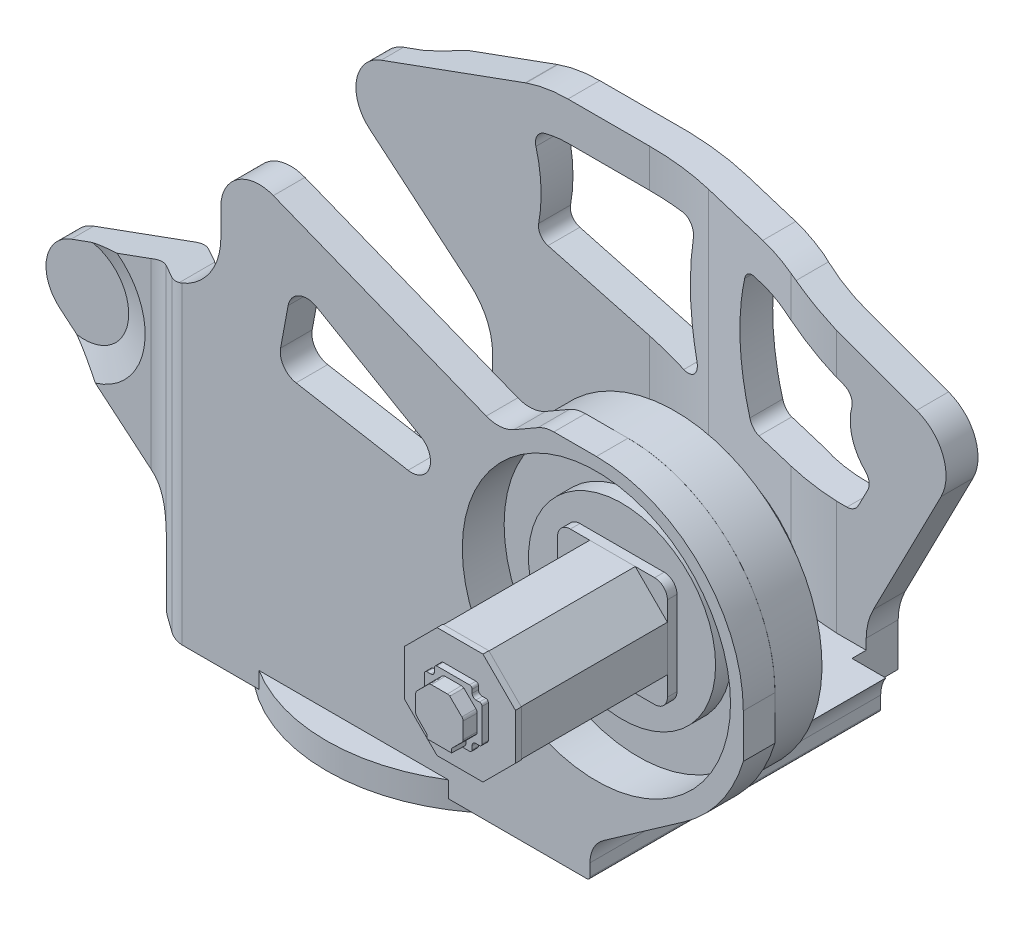
SolidWorks part; units mm, degrees
ref_plane "Front view" through (0, 0, 0) normal (0, 0, 1) x (1, 0, 0)
ref_plane "Top view" through (0, 0, 0) normal (0, 1, 0) x (1, 0, 0)
ref_plane "Side view" through (0, 0, 0) normal (1, 0, 0) x (0, 0, -1)
sketch "Sketch1" plane through (-3843.2967, -4923.9691, 0) normal (0, 0, 1) x (1, 0, 0)
  line L1 (3127.0246, 5479.197) -> (3104.5687, 5456.7412)
  line L2 (3104.5687, 5121.197) -> (3127.0246, 5098.7412)
  line L3 (3087.0969, 5241.5431) -> (3086.697, 5242.2358)
  line L4 (3086.6967, 5250.8502) -> (3087.0967, 5251.5431)
  line L5 (3087.0968, 5241.5427) -> (3087.0968, 5251.5427)
  line L6 (3087.0968, 5241.5427) -> (3092.6967, 5241.5427)
  line L7 (3087.0968, 5251.5427) -> (3092.6967, 5251.5427)
  line L8 (3086.6967, 5242.2356) -> (3086.6967, 5250.8501)
  line L9 (3087.0969, 5326.3959) -> (3086.697, 5327.0886)
  line L10 (3086.6967, 5335.703) -> (3087.0967, 5336.3959)
  line L11 (3087.0968, 5326.3955) -> (3087.0968, 5336.3955)
  line L12 (3087.0968, 5326.3955) -> (3092.6967, 5326.3955)
  line L13 (3087.0968, 5336.3955) -> (3092.6967, 5336.3955)
  line L14 (3086.6967, 5327.0884) -> (3086.6967, 5335.7029)
  line L15 (3094.2967, 5362.9691) -> (3092.6967, 5362.9691)
  line L16 (3094.2967, 5214.9691) -> (3092.6967, 5214.9691)
  line L17 (3099.2967, 5444.0133) -> (3099.2967, 5133.9249)
  line L18 (3094.2967, 5363.9691) -> (3094.2967, 5213.9691)
  line L19 (3094.2967, 5362.9691) -> (3094.2967, 5214.9691)
  line L20 (3092.6967, 5362.9691) -> (3092.6967, 5214.9691)
  line L21 (3843.2967, 4923.9691) -> (3843.2967, 5238.4017)
  line L22 (4003.2967, 4993.9691) -> (4003.2967, 5163.9691)
  line L23 (4234.6156, 5003.8985) -> (4360.9657, 5092.3801)
  line L24 (3723.2967, 5053.9691) -> (3723.2967, 5163.9691)
  line L25 (3833.2967, 5163.9691) -> (3833.2967, 4993.9691)
  line L27 (4273.2967, 4923.9691) -> (4143.2967, 4923.9691)
  line L28 (4273.2967, 4893.9691) -> (4143.2967, 4893.9691)
  line L34 (3523.2967, 4938.9691) -> (3695.7975, 4938.9691)
  line L35 (3563.2967, 4923.9691) -> (4213.2967, 4923.9691)
  line L36 (4101.7967, 4894.9691) -> (3584.7967, 4894.9691)
  line L76 (3605.7967, 4909.1693) -> (3605.7967, 4923.9691)
  line L81 (3563.2967, 4923.9691) -> (3563.2967, 4933.9691)
  line L95 (3518.2967, 5034.7926) -> (3518.2967, 4943.9691)
  line L99 (3705.5251, 4963.9691) -> (3981.0682, 4963.9691)
  line L101 (3838.2967, 4988.9691) -> (3998.2967, 4988.9691)
  line L102 (3809.7409, 5026.4688) -> (3811.1843, 5028.9688)
  line L103 (3806.8543, 5026.469) -> (3809.741, 5026.469)
  line L104 (3805.4103, 5028.9687) -> (3806.8537, 5026.4687)
  line L105 (3806.8539, 5031.4688) -> (3805.4106, 5028.9689)
  line L106 (3809.7403, 5031.4694) -> (3806.8533, 5031.4694)
  line L107 (3811.1838, 5028.9686) -> (3809.7405, 5031.4686)
  line L108 (3824.7409, 5056.4688) -> (3826.1843, 5058.9688)
  line L109 (3821.8543, 5056.469) -> (3824.741, 5056.469)
  line L110 (3820.4103, 5058.9687) -> (3821.8537, 5056.4687)
  line L111 (3821.8539, 5061.4688) -> (3820.4106, 5058.9689)
  line L112 (3824.7403, 5061.4694) -> (3821.8533, 5061.4694)
  line L113 (3826.1838, 5058.9686) -> (3824.7405, 5061.4686)
  line L114 (3844.7409, 4996.4688) -> (3846.1843, 4998.9688)
  line L115 (3841.8543, 4996.469) -> (3844.741, 4996.469)
  line L116 (3840.4103, 4998.9687) -> (3841.8537, 4996.4687)
  line L117 (3841.8539, 5001.4688) -> (3840.4106, 4998.9689)
  line L118 (3844.7403, 5001.4694) -> (3841.8533, 5001.4694)
  line L119 (3846.1838, 4998.9686) -> (3844.7405, 5001.4686)
  line L120 (3734.7409, 5056.4688) -> (3736.1843, 5058.9688)
  line L121 (3731.8543, 5056.469) -> (3734.741, 5056.469)
  line L122 (3730.4103, 5058.9687) -> (3731.8537, 5056.4687)
  line L123 (3731.8539, 5061.4688) -> (3730.4106, 5058.9689)
  line L124 (3734.7403, 5061.4694) -> (3731.8533, 5061.4694)
  line L125 (3736.1838, 5058.9686) -> (3734.7405, 5061.4686)
  line L195 (3828.2967, 5048.9691) -> (3833.2967, 5053.9691)
  line L196 (3723.2967, 5053.9691) -> (3728.2967, 5048.9691)
  line L197 (3728.2967, 5048.9691) -> (3828.2967, 5048.9691)
  line L198 (3833.2967, 4993.9691) -> (3838.2967, 4988.9691)
  line L202 (3695.7975, 4923.9691) -> (3695.7975, 4958.9691)
  line L205 (3768.2967, 4988.9691) -> (3838.2967, 4988.9691)
  line L207 (3763.2967, 4993.9691) -> (3763.2967, 5043.9691)
  line L211 (3994.7409, 4996.4688) -> (3996.1843, 4998.9688)
  line L212 (3991.8543, 4996.469) -> (3994.741, 4996.469)
  line L213 (3990.4103, 4998.9687) -> (3991.8537, 4996.4687)
  line L214 (3991.8539, 5001.4688) -> (3990.4106, 4998.9689)
  line L215 (3994.7403, 5001.4694) -> (3991.8533, 5001.4694)
  line L216 (3996.1838, 4998.9686) -> (3994.7405, 5001.4686)
  line L245 (4213.2967, 4923.9691) -> (4213.2967, 4962.9425)
  line L247 (4153.2967, 4893.9691) -> (4153.2967, 4923.9691)
  line L248 (4143.2967, 4893.9691) -> (4143.2967, 4923.9691)
  line L249 (4080.7967, 4909.1693) -> (4080.7967, 4923.9691)
  line L254 (4121.1005, 4923.9691) -> (4121.1005, 4938.9691)
  line L255 (3998.2967, 4988.9691) -> (4003.2967, 4993.9691)
  line L256 (3990.7958, 4923.9691) -> (3990.7958, 4958.9691)
  line L266 (3990.7958, 4938.9691) -> (4208.2967, 4938.9691)
  line L267 (4268.2967, 4893.9691) -> (4268.2967, 4923.9691)
  line L268 (4273.2967, 4893.9691) -> (4273.2967, 4923.9691)
  line L274 (4241.9467, 5196.9691) -> (4204.6467, 5196.9691)
  line L275 (4236.2967, 5199.9691) -> (4210.2967, 5199.9691)
  line L276 (4262.2967, 5377.9691) -> (4154.2967, 5377.9691)
  line L277 (4157.2967, 5374.9691) -> (4289.2967, 5374.9691)
  line L279 (4191.4022, 5365.9691) -> (4255.1911, 5365.9691)
  line L280 (4157.2967, 5202.9691) -> (4289.2967, 5202.9691)
  line L281 (4191.4022, 5211.9691) -> (4255.1911, 5211.9691)
  line L282 (4204.2467, 5199.9691) -> (4242.3467, 5199.9691)
  line L283 (3760.2967, 5353.9691) -> (3630.2967, 5353.9691)
  line L284 (3630.2967, 5323.9691) -> (3760.2967, 5323.9691)
  line L285 (3657.2967, 5353.9691) -> (3733.2967, 5353.9691)
  line L286 (3657.2967, 5323.9691) -> (3733.2966, 5323.9691)
  line L287 (3664.5467, 5356.9691) -> (3726.0467, 5356.9691)
  line L288 (3664.5467, 5320.9691) -> (3726.0467, 5320.9691)
  line L289 (3434.2967, 5484.4691) -> (3434.2967, 5378.2977)
  line L290 (3434.7967, 5439.4511) -> (3434.7967, 5455.4732)
  line L291 (3364.2967, 5479.4691) -> (3364.2967, 5357.7514)
  line L292 (3132.2967, 5482.8523) -> (3132.2967, 5095.0859)
  line L293 (3434.2967, 5389.8638) -> (3369.2967, 5389.8638)
  line L294 (3569.4987, 5427.5072) -> (3343.7754, 5345.3507)
  line L295 (3325.7294, 5243.0064) -> (3482.5754, 5111.397)
  line L296 (3434.2967, 5093.4691) -> (3139.7525, 5093.4691)
  line L297 (3364.2967, 5231.4873) -> (3364.2967, 5346.4508)
  line L298 (3362.5638, 5246.9696) -> (3360.8316, 5243.9694)
  line L299 (3366.0286, 5246.9691) -> (3362.5645, 5246.9691)
  line L300 (3367.7604, 5243.9695) -> (3366.0282, 5246.9697)
  line L301 (3366.0285, 5240.9691) -> (3367.7605, 5243.9691)
  line L302 (3362.5645, 5240.9689) -> (3366.0286, 5240.9689)
  line L303 (3360.832, 5243.9697) -> (3362.5642, 5240.9695)
  line L304 (3341.7962, 5253.4629) -> (3338.796, 5251.7307)
  line L305 (3344.7966, 5251.7301) -> (3341.7965, 5253.4621)
  line L306 (3344.7965, 5248.2664) -> (3344.7965, 5251.7308)
  line L307 (3341.7964, 5246.534) -> (3344.7964, 5248.266)
  line L308 (3338.7964, 5248.2658) -> (3341.7964, 5246.5337)
  line L309 (3338.7965, 5251.7308) -> (3338.7965, 5248.2664)
  line L310 (3383.7957, 5251.73) -> (3383.7957, 5248.2657)
  line L311 (3386.7966, 5253.462) -> (3383.7965, 5251.7299)
  line L312 (3389.7962, 5251.7301) -> (3386.7959, 5253.4623)
  line L313 (3389.7965, 5248.2658) -> (3389.7965, 5251.7299)
  line L314 (3386.7967, 5246.5336) -> (3389.7967, 5248.2656)
  line L315 (3383.7959, 5248.2662) -> (3386.7961, 5246.534)
  line L316 (3368.2762, 5286.6669) -> (3368.2762, 5291.2711)
  line L317 (3360.3172, 5286.6669) -> (3360.3172, 5291.2711)
  line L318 (3360.3163, 5286.6671) -> (3364.2965, 5284.3692)
  line L319 (3364.2967, 5284.3691) -> (3368.2769, 5286.667)
  line L320 (3364.2969, 5293.569) -> (3368.2771, 5291.2711)
  line L321 (3360.3171, 5291.2716) -> (3364.2963, 5293.5689)
  line L322 (3386.7971, 5324.4753) -> (3389.7973, 5326.2075)
  line L323 (3383.7968, 5326.2081) -> (3386.7968, 5324.4761)
  line L324 (3383.7968, 5329.6718) -> (3383.7968, 5326.2075)
  line L325 (3386.7969, 5331.4042) -> (3383.7969, 5329.6722)
  line L326 (3389.7969, 5329.6724) -> (3386.7969, 5331.4045)
  line L327 (3389.7968, 5326.2074) -> (3389.7968, 5329.6718)
  line L328 (3322.2971, 5290.702) -> (3319.2969, 5292.4341)
  line L329 (3322.2967, 5287.2372) -> (3322.2967, 5290.7013)
  line L330 (3319.297, 5285.5054) -> (3322.2972, 5287.2376)
  line L331 (3316.2966, 5287.2373) -> (3319.2966, 5285.5053)
  line L332 (3316.2964, 5290.7013) -> (3316.2964, 5287.2372)
  line L333 (3319.2972, 5292.4337) -> (3316.297, 5290.7015)
  line L334 (3327.0576, 5269.47) -> (3323.5932, 5269.47)
  line L335 (3328.7896, 5266.4692) -> (3327.0575, 5269.4692)
  line L336 (3327.0577, 5263.4696) -> (3328.7898, 5266.4698)
  line L337 (3323.5933, 5263.4693) -> (3327.0574, 5263.4693)
  line L338 (3321.8611, 5266.4691) -> (3323.5932, 5263.4691)
  line L339 (3323.5937, 5269.4698) -> (3321.8615, 5266.4696)
  line L340 (3328.7904, 5311.4696) -> (3327.0583, 5314.4698)
  line L341 (3327.0576, 5308.4692) -> (3328.7897, 5311.4692)
  line L342 (3323.5939, 5308.4693) -> (3327.0583, 5308.4693)
  line L343 (3321.8615, 5311.4693) -> (3323.5936, 5308.4693)
  line L344 (3323.5933, 5314.4693) -> (3321.8613, 5311.4693)
  line L345 (3327.0583, 5314.4693) -> (3323.594, 5314.4693)
  line L346 (3344.7976, 5326.2082) -> (3344.7976, 5329.6725)
  line L347 (3341.7968, 5324.4762) -> (3344.7968, 5326.2083)
  line L348 (3338.7972, 5326.2081) -> (3341.7974, 5324.4759)
  line L349 (3338.7969, 5329.6724) -> (3338.7969, 5326.2083)
  line L350 (3341.7966, 5331.4046) -> (3338.7966, 5329.6726)
  line L351 (3344.7974, 5329.672) -> (3341.7972, 5331.4042)
  line L352 (3366.0295, 5330.9686) -> (3367.7617, 5333.9688)
  line L353 (3362.5647, 5330.9691) -> (3366.0288, 5330.9691)
  line L354 (3360.8329, 5333.9688) -> (3362.5651, 5330.9685)
  line L355 (3362.5649, 5336.9691) -> (3360.8328, 5333.9691)
  line L356 (3366.0288, 5336.9694) -> (3362.5647, 5336.9694)
  line L357 (3367.7613, 5333.9685) -> (3366.0291, 5336.9687)
  line L358 (3391.1949, 5188.0744) -> (3369.2967, 5188.0744)
  line L359 (3364.2967, 5220.1868) -> (3364.2967, 5098.4691)
  line L360 (3668.9972, 5338.9689) -> (3666.6471, 5343.0394)
  line L361 (3666.6472, 5334.8989) -> (3668.9971, 5338.969)
  line L362 (3661.947, 5334.8989) -> (3666.6472, 5334.8992)
  line L363 (3659.5973, 5338.9683) -> (3661.9473, 5334.8981)
  line L364 (3661.9471, 5343.0395) -> (3659.5971, 5338.969)
  line L365 (3666.6468, 5343.0397) -> (3661.9468, 5343.0397)
  line L366 (3636.7409, 5336.4688) -> (3638.1843, 5338.9688)
  line L367 (3633.8543, 5336.469) -> (3636.741, 5336.469)
  line L368 (3632.4103, 5338.9687) -> (3633.8537, 5336.4687)
  line L369 (3633.8539, 5341.4688) -> (3632.4106, 5338.9689)
  line L370 (3636.7403, 5341.4694) -> (3633.8533, 5341.4694)
  line L371 (3638.1838, 5338.9686) -> (3636.7405, 5341.4686)
  line L372 (3406.2962, 5287.2363) -> (3409.2964, 5285.5041)
  line L373 (3406.2967, 5290.701) -> (3406.2967, 5287.2369)
  line L374 (3409.2963, 5292.4328) -> (3406.2961, 5290.7006)
  line L375 (3412.2967, 5290.7009) -> (3409.2967, 5292.433)
  line L376 (3412.2969, 5287.2369) -> (3412.2969, 5290.701)
  line L377 (3409.2961, 5285.5045) -> (3412.2963, 5287.2367)
  line L378 (3399.8029, 5266.4687) -> (3401.535, 5263.4684)
  line L379 (3401.5357, 5269.469) -> (3399.8036, 5266.469)
  line L380 (3404.9994, 5269.4689) -> (3401.535, 5269.4689)
  line L381 (3406.7318, 5266.4689) -> (3404.9997, 5269.4689)
  line L382 (3405, 5263.4689) -> (3406.7321, 5266.4689)
  line L383 (3401.535, 5263.469) -> (3404.9993, 5263.469)
  line L384 (3401.5357, 5308.4682) -> (3405.0001, 5308.4682)
  line L385 (3399.8038, 5311.469) -> (3401.5358, 5308.469)
  line L386 (3401.5356, 5314.4686) -> (3399.8035, 5311.4684)
  line L387 (3405, 5314.4689) -> (3401.5359, 5314.4689)
  line L388 (3406.7322, 5311.4691) -> (3405.0001, 5314.4691)
  line L389 (3404.9996, 5308.4684) -> (3406.7318, 5311.4686)
  line L390 (3625.2967, 5348.9691) -> (3625.2967, 5328.9691)
  line L391 (3645.2967, 5323.9691) -> (3645.2967, 5353.9691)
  line L392 (3625.2967, 5328.9692) -> (3630.2967, 5323.9693)
  line L393 (3630.2967, 5353.969) -> (3625.2967, 5348.9691)
  line L394 (3652.2967, 5348.9691) -> (3652.2967, 5328.9691)
  line L395 (3657.2967, 5353.9691) -> (3652.2967, 5348.9691)
  line L396 (3652.2966, 5328.9691) -> (3657.2967, 5323.9691)
  line L397 (3664.5467, 5320.9691) -> (3664.5467, 5323.9691)
  line L398 (3664.5467, 5353.9691) -> (3664.5467, 5356.9691)
  line L399 (3434.7967, 5397.7191) -> (3434.7967, 5423.4511)
  line L400 (3434.2967, 5381.7191) -> (3443.6969, 5381.7191)
  line L401 (3434.7967, 5378.4797) -> (3434.7967, 5381.7191)
  line L402 (3592.4967, 5439.4511) -> (3434.2967, 5439.4511)
  line L403 (3558.3547, 5423.4511) -> (3434.2967, 5423.4511)
  line L404 (3487.6565, 5397.7191) -> (3434.2967, 5397.7191)
  line L405 (3434.7967, 5106.465) -> (3434.7967, 5099.4691)
  line L406 (3435.7967, 5098.4691) -> (3434.7967, 5099.4691)
  line L407 (3434.7967, 5122.465) -> (3434.7967, 5138.4871)
  line L408 (3434.2967, 5151.9077) -> (3434.2967, 5093.4691)
  line L409 (3495.4024, 5098.4691) -> (3435.7967, 5098.4691)
  line L410 (3488.0323, 5106.465) -> (3434.2967, 5106.465)
  line L411 (3469.3851, 5122.465) -> (3434.2967, 5122.465)
  line L412 (3450.2907, 5138.4871) -> (3434.2967, 5138.4871)
  line L413 (3434.2967, 5484.4691) -> (3175.2967, 5484.4691)
  line L414 (3155.2967, 5505.5914) -> (3155.2967, 5473.235)
  line L415 (3140.2967, 5494.469) -> (3170.2967, 5494.469)
  line L416 (3170.2967, 5484.4691) -> (3140.2967, 5484.4691)
  line L417 (3140.2967, 5494.469) -> (3140.2967, 5489.0334)
  line L418 (3170.2967, 5494.469) -> (3170.2967, 5489.4691)
  line L419 (3637.3485, 5563.969) -> (3648.0731, 5547.7045)
  line L420 (3673.0495, 5603.9365) -> (3668.7897, 5605.9229)
  line L421 (3673.459, 5599.2546) -> (3673.0494, 5603.9364)
  line L422 (3669.6087, 5596.5587) -> (3673.4588, 5599.2548)
  line L423 (3665.3499, 5598.5444) -> (3669.6095, 5596.5582)
  line L424 (3664.9396, 5603.2272) -> (3665.3493, 5598.5449)
  line L425 (3668.7892, 5605.9229) -> (3664.9393, 5603.2271)
  line L426 (3635.2967, 5529.3281) -> (3635.2967, 5521.4765)
  line L427 (3648.9575, 5546.3503) -> (3649.5193, 5544.8068)
  line L428 (3649.5193, 5544.8072) -> (3649.998, 5544.7228)
  line L429 (3434.7967, 5478.4691) -> (3434.7967, 5471.4732)
  line L430 (3435.7967, 5479.4691) -> (3434.7967, 5478.4691)
  line L431 (3610.4204, 5455.4732) -> (3434.2967, 5455.4732)
  line L432 (3626.0457, 5479.4691) -> (3435.7967, 5479.4691)
  line L433 (3621.8973, 5471.4732) -> (3434.2967, 5471.4732)
  line L434 (3816.2967, 5372.5707) -> (3816.2967, 5477.9691)
  line L435 (3840.2967, 5368.3388) -> (3840.2967, 5456.9691)
  line L436 (3764.2967, 5381.7397) -> (3764.2967, 5482.9691)
  line L437 (3740.5659, 5482.2232) -> (3728.8064, 5418.7217)
  line L438 (3763.7967, 5439.4511) -> (3763.7967, 5455.4732)
  line L441 (3785.0644, 5502.7412) -> (3948.5835, 5408.3334)
  line L442 (3805.2967, 5168.9691) -> (3998.2967, 5168.9691)
  line L443 (3824.7409, 5156.4688) -> (3826.1843, 5158.9688)
  line L444 (3821.8543, 5156.469) -> (3824.741, 5156.469)
  line L445 (3820.4103, 5158.9687) -> (3821.8537, 5156.4687)
  line L446 (3821.8539, 5161.4688) -> (3820.4106, 5158.9689)
  line L447 (3824.7403, 5161.4694) -> (3821.8533, 5161.4694)
  line L448 (3826.1838, 5158.9686) -> (3824.7405, 5161.4686)
  line L449 (3844.7409, 5156.4688) -> (3846.1843, 5158.9688)
  line L450 (3841.8543, 5156.469) -> (3844.741, 5156.469)
  line L451 (3840.4103, 5158.9687) -> (3841.8537, 5156.4687)
  line L452 (3841.8539, 5161.4688) -> (3840.4106, 5158.9689)
  line L453 (3844.7403, 5161.4694) -> (3841.8533, 5161.4694)
  line L454 (3846.1838, 5158.9686) -> (3844.7405, 5161.4686)
  line L455 (3816.7409, 5096.4688) -> (3818.1843, 5098.9688)
  line L456 (3813.8543, 5096.469) -> (3816.741, 5096.469)
  line L457 (3812.4103, 5098.9687) -> (3813.8537, 5096.4687)
  line L458 (3813.8539, 5101.4688) -> (3812.4106, 5098.9689)
  line L459 (3816.7403, 5101.4694) -> (3813.8533, 5101.4694)
  line L460 (3818.1838, 5098.9686) -> (3816.7405, 5101.4686)
  line L461 (3816.7409, 5132.4688) -> (3818.1843, 5134.9688)
  line L462 (3813.8543, 5132.469) -> (3816.741, 5132.469)
  line L463 (3812.4103, 5134.9687) -> (3813.8537, 5132.4687)
  line L464 (3813.8539, 5137.4688) -> (3812.4106, 5134.9689)
  line L465 (3816.7403, 5137.4694) -> (3813.8533, 5137.4694)
  line L466 (3818.1838, 5134.9686) -> (3816.7405, 5137.4686)
  line L467 (3762.7409, 5096.4688) -> (3764.1843, 5098.9688)
  line L468 (3759.8543, 5096.469) -> (3762.741, 5096.469)
  line L469 (3758.4103, 5098.9687) -> (3759.8537, 5096.4687)
  line L470 (3759.8539, 5101.4688) -> (3758.4106, 5098.9689)
  line L471 (3762.7403, 5101.4694) -> (3759.8533, 5101.4694)
  line L472 (3764.1838, 5098.9686) -> (3762.7405, 5101.4686)
  line L473 (3762.7409, 5132.4688) -> (3764.1843, 5134.9688)
  line L474 (3759.8543, 5132.469) -> (3762.741, 5132.469)
  line L475 (3758.4103, 5134.9687) -> (3759.8537, 5132.4687)
  line L476 (3759.8539, 5137.4688) -> (3758.4106, 5134.9689)
  line L477 (3762.7403, 5137.4694) -> (3759.8533, 5137.4694)
  line L478 (3764.1838, 5134.9686) -> (3762.7405, 5137.4686)
  line L479 (3730.9972, 5338.9689) -> (3728.6471, 5343.0394)
  line L480 (3728.6472, 5334.8989) -> (3730.9971, 5338.969)
  line L481 (3723.947, 5334.8989) -> (3728.6472, 5334.8992)
  line L482 (3721.5973, 5338.9683) -> (3723.9473, 5334.8981)
  line L483 (3723.9471, 5343.0395) -> (3721.5971, 5338.969)
  line L484 (3728.6468, 5343.0397) -> (3723.9468, 5343.0397)
  line L485 (3756.7409, 5336.4688) -> (3758.1843, 5338.9688)
  line L486 (3753.8543, 5336.469) -> (3756.741, 5336.469)
  line L487 (3752.4103, 5338.9687) -> (3753.8537, 5336.4687)
  line L488 (3753.8539, 5341.4688) -> (3752.4106, 5338.9689)
  line L489 (3756.7403, 5341.4694) -> (3753.8533, 5341.4694)
  line L490 (3758.1838, 5338.9686) -> (3756.7405, 5341.4686)
  line L491 (3734.7409, 5156.4688) -> (3736.1843, 5158.9688)
  line L492 (3731.8543, 5156.469) -> (3734.741, 5156.469)
  line L493 (3730.4103, 5158.9687) -> (3731.8537, 5156.4687)
  line L494 (3731.8539, 5161.4688) -> (3730.4106, 5158.9689)
  line L495 (3734.7403, 5161.4694) -> (3731.8533, 5161.4694)
  line L496 (3736.1838, 5158.9686) -> (3734.7405, 5161.4686)
  line L497 (3840.2967, 5408.9691) -> (3843.2967, 5408.9691)
  line L498 (3840.2967, 5438.9691) -> (3895.521, 5438.9691)
  line L499 (3863.2967, 5364.2833) -> (3863.2967, 5388.9691)
  line L500 (3763.7967, 5423.4511) -> (3763.7967, 5397.7191)
  line L501 (3764.2967, 5397.7191) -> (3732.6434, 5397.7191)
  line L502 (3764.2967, 5439.4511) -> (3732.6452, 5439.4511)
  line L503 (3764.2967, 5423.4511) -> (3729.6822, 5423.4511)
  line L504 (3745.2968, 5323.9691) -> (3745.2968, 5353.9691)
  line L505 (3726.0467, 5320.9691) -> (3726.0467, 5323.9691)
  line L506 (3726.0467, 5353.9691) -> (3726.0467, 5356.9691)
  line L507 (3738.2967, 5348.9691) -> (3738.2967, 5328.9691)
  line L508 (3738.2967, 5348.9691) -> (3733.2967, 5353.9691)
  line L509 (3738.2967, 5328.9691) -> (3733.2966, 5323.9691)
  line L511 (3765.2967, 5348.9689) -> (3765.2967, 5328.9691)
  line L512 (3760.2967, 5323.9689) -> (3765.2967, 5328.9689)
  line L513 (3760.2967, 5353.9688) -> (3765.2965, 5348.9688)
  line L515 (3753.0954, 5383.7148) -> (3928.3741, 5352.8084)
  line L516 (3828.2967, 5168.9691) -> (3833.2967, 5163.9691)
  line L517 (3805.2967, 5173.93) -> (3805.2967, 5155.9691)
  line L518 (3838.2967, 5168.9691) -> (3833.2967, 5163.9691)
  line L519 (3809.7967, 5099.4691) -> (3809.7967, 5155.9691)
  line L520 (3821.7967, 5088.4691) -> (3821.7967, 5145.4691)
  line L521 (3728.2967, 5168.9691) -> (3723.2967, 5163.9691)
  line L522 (3771.2967, 5173.93) -> (3771.2967, 5155.9691)
  line L523 (3728.2967, 5168.9691) -> (3771.2967, 5168.9691)
  line L525 (3766.7967, 5099.4691) -> (3766.7967, 5155.9691)
  line L526 (3754.7967, 5088.4691) -> (3754.7967, 5145.4691)
  line L527 (3809.7967, 5155.9691) -> (3766.7957, 5155.9691)
  line L536 (4105.9114, 5410.4921) -> (4104.3973, 5416.1426)
  line L537 (4101.7746, 5406.3553) -> (4105.9113, 5410.4919)
  line L541 (4158.4362, 5359.6796) -> (4155.5113, 5364.7459)
  line L542 (4155.5114, 5354.6137) -> (4158.4363, 5359.6798)
  line L543 (4149.661, 5354.6137) -> (4155.5111, 5354.6137)
  line L544 (4146.7366, 5359.6794) -> (4149.6614, 5354.6135)
  line L545 (4149.6618, 5364.7459) -> (4146.7367, 5359.6796)
  line L546 (4149.6611, 5364.7462) -> (4155.511, 5364.7462)
  line L547 (4158.4367, 5218.2577) -> (4155.5117, 5223.324)
  line L548 (4155.5118, 5213.1918) -> (4158.4367, 5218.2579)
  line L549 (4149.6615, 5213.1918) -> (4155.5116, 5213.1918)
  line L550 (4146.737, 5218.2575) -> (4149.6619, 5213.1915)
  line L551 (4149.6622, 5223.324) -> (4146.7372, 5218.2577)
  line L552 (4149.6616, 5223.3243) -> (4155.5115, 5223.3243)
  line L571 (4210.2967, 5199.9691) -> (4210.2967, 5196.9691)
  line L572 (4204.6467, 5196.9691) -> (4204.6467, 5168.9691)
  line L598 (3994.7409, 5156.4688) -> (3996.1843, 5158.9688)
  line L599 (3991.8543, 5156.469) -> (3994.741, 5156.469)
  line L600 (3990.4103, 5158.9687) -> (3991.8537, 5156.4687)
  line L601 (3991.8539, 5161.4688) -> (3990.4106, 5158.9689)
  line L602 (3994.7403, 5161.4694) -> (3991.8533, 5161.4694)
  line L603 (3996.1838, 5158.9686) -> (3994.7405, 5161.4686)
  line L616 (4179.2967, 5377.9691) -> (4159.2967, 5377.9691)
  line L625 (4146.2967, 5257.0747) -> (4146.2967, 5320.8635)
  line L630 (4146.2967, 5320.8635) -> (4191.4022, 5365.9691)
  line L654 (4137.2967, 5324.5915) -> (4187.6743, 5374.9691)
  line L655 (4154.2967, 5199.9691) -> (4201.0467, 5199.9691)
  line L656 (4137.2967, 5253.3467) -> (4187.6743, 5202.9691)
  line L657 (4201.0467, 5185.9691) -> (4201.0467, 5202.9691)
  line L658 (4201.0467, 5185.9691) -> (4204.6467, 5185.9691)
  line L659 (4201.0467, 5188.9691) -> (4204.6467, 5188.9691)
  line L660 (4204.2467, 5199.9691) -> (4204.2467, 5202.9691)
  line L661 (4207.4217, 5196.9691) -> (4207.4217, 5199.9691)
  line L662 (4208.1267, 5196.9691) -> (4207.4217, 5197.6741)
  line L663 (3998.2967, 5168.9691) -> (4003.2967, 5163.9691)
  line L668 (4134.2967, 5357.9691) -> (4134.2967, 5219.9691)
  line L669 (4137.2967, 5222.9691) -> (4137.2967, 5354.9691)
  line L670 (4146.2967, 5257.0747) -> (4191.4022, 5211.9691)
  line L671 (4050.8679, 5487.6069) -> (3736.816, 5612.0555)
  line L672 (3790.2967, 5499.0914) -> (3790.2967, 5466.735)
  line L673 (3805.297, 5487.969) -> (3775.297, 5487.969)
  line L674 (3717.5438, 5524.0017) -> (3721.8036, 5522.0153)
  line L675 (3717.1343, 5528.6836) -> (3717.544, 5524.0018)
  line L676 (3720.9846, 5531.3795) -> (3717.1345, 5528.6834)
  line L677 (3725.2435, 5529.3938) -> (3720.9838, 5531.38)
  line L678 (3725.6537, 5524.711) -> (3725.244, 5529.3933)
  line L679 (3721.8041, 5522.0153) -> (3725.654, 5524.7111)
  line L680 (3736.4448, 5543.9902) -> (3741.0736, 5544.8063)
  line L681 (3733.424, 5547.5905) -> (3736.4449, 5543.9903)
  line L682 (3735.0316, 5552.0072) -> (3733.4243, 5547.5904)
  line L683 (3739.6592, 5552.8234) -> (3735.0307, 5552.0072)
  line L684 (3742.6812, 5549.2229) -> (3739.6599, 5552.8234)
  line L685 (3741.074, 5544.8066) -> (3742.6814, 5549.2231)
  line L686 (3739.6602, 5575.1139) -> (3742.6814, 5578.7144)
  line L687 (3735.0319, 5575.9301) -> (3739.6602, 5575.114)
  line L688 (3733.4243, 5580.3469) -> (3735.0321, 5575.9303)
  line L689 (3736.4447, 5583.9467) -> (3733.4237, 5580.3463)
  line L690 (3741.074, 5583.131) -> (3736.4452, 5583.9472)
  line L691 (3742.6815, 5578.7149) -> (3741.074, 5583.1314)
  line L692 (3699.9972, 5609.4689) -> (3697.6471, 5613.5394)
  line L693 (3697.6472, 5605.3989) -> (3699.9971, 5609.469)
  line L694 (3692.947, 5605.3989) -> (3697.6472, 5605.3992)
  line L695 (3690.5973, 5609.4683) -> (3692.9473, 5605.3981)
  line L696 (3692.9471, 5613.5395) -> (3690.5971, 5609.469)
  line L697 (3697.6468, 5613.5397) -> (3692.9468, 5613.5397)
  line L698 (3725.2447, 5598.5442) -> (3725.6544, 5603.2266)
  line L699 (3720.9853, 5596.5582) -> (3725.2446, 5598.5444)
  line L700 (3717.1351, 5599.2542) -> (3720.9854, 5596.5585)
  line L701 (3717.5444, 5603.9354) -> (3717.1349, 5599.2533)
  line L702 (3721.8044, 5605.9225) -> (3717.5446, 5603.936)
  line L703 (3725.6542, 5603.227) -> (3721.8043, 5605.9228)
  line L704 (3835.2967, 5461.9691) -> (3831.2967, 5461.9691)
  line L705 (3762.7967, 5479.4691) -> (3740.0559, 5479.4691)
  line L706 (3764.2967, 5471.4732) -> (3738.5752, 5471.4732)
  line L707 (3764.2967, 5455.4732) -> (3735.6122, 5455.4732)
  line L708 (3763.7967, 5471.4732) -> (3763.7967, 5478.4691)
  line L709 (3762.7967, 5479.4691) -> (3763.7967, 5478.4691)
  line L710 (3811.2967, 5482.9691) -> (3764.2967, 5482.9691)
  line L723 (4223.2967, 5518.9691) -> (4156.6468, 5518.9691)
  line L724 (4131.7233, 5512.3144) -> (4094.2113, 5490.745)
  line L767 (4299.8575, 5359.6796) -> (4296.9326, 5364.7459)
  line L768 (4296.9327, 5354.6136) -> (4299.8576, 5359.6798)
  line L769 (4291.0823, 5354.6136) -> (4296.9324, 5354.6136)
  line L770 (4288.1579, 5359.6793) -> (4291.0827, 5354.6134)
  line L771 (4291.0831, 5364.7459) -> (4288.158, 5359.6795)
  line L772 (4291.0824, 5364.7462) -> (4296.9323, 5364.7462)
  line L786 (4236.2967, 5199.9691) -> (4236.2967, 5196.9691)
  line L787 (4241.9467, 5196.9691) -> (4241.9467, 5168.9691)
  line L788 (4299.8575, 5218.2582) -> (4296.9326, 5223.3245)
  line L789 (4296.9327, 5213.1923) -> (4299.8576, 5218.2584)
  line L790 (4291.0823, 5213.1923) -> (4296.9324, 5213.1923)
  line L791 (4288.1579, 5218.258) -> (4291.0827, 5213.192)
  line L792 (4291.0831, 5223.3245) -> (4288.158, 5218.2582)
  line L793 (4291.0824, 5223.3248) -> (4296.9323, 5223.3248)
  line L800 (4278.7409, 5390.4688) -> (4280.1843, 5392.9688)
  line L801 (4275.8543, 5390.469) -> (4278.741, 5390.469)
  line L802 (4274.4103, 5392.9686) -> (4275.8537, 5390.4687)
  line L803 (4275.8539, 5395.4688) -> (4274.4106, 5392.9688)
  line L804 (4278.7403, 5395.4693) -> (4275.8533, 5395.4693)
  line L805 (4280.1838, 5392.9686) -> (4278.7405, 5395.4686)
  line L806 (4300.2967, 5257.0747) -> (4300.2967, 5320.8635)
  line L807 (4287.2967, 5382.9691) -> (4287.2967, 5392.9691)
  line L808 (4267.2967, 5382.9691) -> (4267.2967, 5392.9691)
  line L809 (4262.2967, 5377.9691) -> (4292.2971, 5377.9691)
  line L816 (4258.919, 5374.9691) -> (4309.2967, 5324.5915)
  line L817 (4255.1911, 5365.9691) -> (4300.2967, 5320.8635)
  line L818 (4245.5467, 5199.9691) -> (4262.2967, 5199.9691)
  line L819 (4241.9466, 5185.9691) -> (4245.5467, 5185.9691)
  line L820 (4241.9466, 5188.9691) -> (4245.5467, 5188.9691)
  line L821 (4245.5467, 5185.9691) -> (4245.5467, 5202.9691)
  line L822 (4242.3467, 5199.9691) -> (4242.3467, 5202.9691)
  line L823 (4238.4667, 5196.9691) -> (4239.1716, 5197.6741)
  line L824 (4239.1717, 5196.9691) -> (4239.1717, 5199.9691)
  line L825 (4267.2967, 5194.9691) -> (4267.2967, 5184.9691)
  line L826 (4287.2967, 5194.9691) -> (4287.2967, 5184.9691)
  line L827 (4262.2967, 5199.9691) -> (4292.2971, 5199.9691)
  line L828 (4258.919, 5202.9691) -> (4309.2967, 5253.3467)
  line L830 (4309.2967, 5222.9691) -> (4309.2967, 5354.9691)
  line L831 (4255.1911, 5211.9691) -> (4300.2967, 5257.0747)
  line L832 (4453.2967, 5220.4126) -> (4453.2967, 5288.9691)
  line L839 (4301.9613, 5505.0984) -> (4303.6532, 5509.7469)
  line L840 (4371.1378, 5465.1593) -> (4374.3175, 5468.9488)
  arc A0 (3104.5687, 5456.7412) -> (3099.2967, 5444.0133) centre (3117.2967, 5444.0133) ccw
  arc A1 (3094.2967, 5363.9691) -> (3099.2967, 5368.9691) centre (3094.2967, 5368.9691) ccw
  arc A2 (3099.2967, 5208.9691) -> (3094.2967, 5213.9691) centre (3094.2967, 5208.9691) ccw
  arc A3 (3099.2967, 5133.9249) -> (3104.5687, 5121.197) centre (3117.2967, 5133.9249) ccw
  arc A4 (3518.2967, 5034.7926) -> (3482.5754, 5111.397) centre (3418.2967, 5034.7926) ccw
  arc A8 (3563.2967, 4933.9691) -> (3558.2967, 4938.9691) centre (3558.2967, 4933.9691) ccw
  arc A9 (3518.2967, 4943.9691) -> (3523.2967, 4938.9691) centre (3523.2967, 4943.9691) ccw
  circle A18 centre (3808.2967, 5028.9691) radius 5
  circle A19 centre (3823.2967, 5058.9691) radius 5
  circle A20 centre (3843.2967, 4998.9691) radius 5
  circle A21 centre (3733.2967, 5058.9691) radius 5
  arc A24 (3763.2967, 5043.9691) -> (3758.2967, 5048.9691) centre (3758.2967, 5043.9691) ccw
  arc A25 (3723.2967, 5053.9691) -> (3728.2967, 5048.9691) centre (3728.2967, 5053.9691) ccw
  arc A28 (3763.2967, 4993.9691) -> (3768.2967, 4988.9691) centre (3768.2967, 4993.9691) ccw
  circle A35 centre (3993.2967, 4998.9691) radius 5
  arc A36 (4234.6156, 5003.8985) -> (4213.2967, 4962.9425) centre (4263.2967, 4962.9425) ccw
  arc A37 (4208.2967, 4938.9691) -> (4213.2967, 4943.9691) centre (4208.2967, 4943.9691) ccw
  arc A39 (3998.2967, 4988.9691) -> (4003.2967, 4993.9691) centre (3998.2967, 4993.9691) ccw
  arc A51 (4453.2967, 5288.969) -> (4223.2967, 5518.969) centre (4223.2967, 5288.969) ccw
  arc A52 (4235.8939, 5143.0125) -> (4178.5967, 5149.4559) centre (4223.2967, 5288.969) ccw
  arc A53 (4112.0294, 5110.869) -> (4068.3092, 5147.269) centre (4223.2967, 5288.969) ccw
  arc A54 (4157.7482, 5118.8096) -> (4099.9153, 5155.2096) centre (4229.4727, 5296.9096) ccw
  arc A55 (3678.051, 5563.969) -> (3676.4578, 5566.4211) centre (3495.2967, 5446.9655) ccw
  arc A56 (3703.7978, 5507.101) -> (3652.646, 5602.533) centre (3695.2967, 5563.9691) ccw
  arc A57 (3704.4819, 5504.6763) -> (3651.2266, 5604.6856) centre (3695.2967, 5563.9691) ccw
  arc A58 (3704.4819, 5504.6763) -> (3651.2266, 5604.6856) centre (3695.2967, 5563.9691) ccw
  arc A61 (3569.4987, 5427.5072) -> (3635.2967, 5521.4765) centre (3535.2967, 5521.4765) ccw
  circle A62 centre (3364.2967, 5288.9691) radius 60
  arc A63 (3353.3495, 5219.8304) -> (3377.6565, 5357.6824) centre (3364.2967, 5288.9691) ccw
  arc A64 (3396.3552, 5183.7444) -> (3430.4108, 5376.8834) centre (3364.2967, 5288.9691) ccw
  circle A65 centre (3364.2967, 5288.9691) radius 54
  circle A66 centre (3364.2967, 5243.9691) radius 6.5
  circle A67 centre (3364.2967, 5288.9691) radius 3.5012
  circle A68 centre (3364.2967, 5288.9691) radius 0.9995
  circle A69 centre (3364.2967, 5288.9691) radius 3.8999
  circle A70 centre (3319.2967, 5288.9691) radius 6.5
  circle A71 centre (3364.2967, 5333.9691) radius 6.5
  arc A72 (3364.2967, 5394.8638) -> (3369.2967, 5389.8638) centre (3369.2967, 5394.8638) ccw
  arc A73 (3369.2967, 5389.8638) -> (3364.2967, 5384.8638) centre (3369.2967, 5384.8638) ccw
  arc A74 (3363.1443, 5352.4003) -> (3364.2967, 5357.7514) centre (3351.2967, 5357.7514) ccw
  arc A75 (3369.2967, 5188.0744) -> (3364.2967, 5183.0744) centre (3369.2967, 5183.0744) ccw
  arc A76 (3364.2967, 5193.0744) -> (3369.2967, 5188.0744) centre (3369.2967, 5193.0744) ccw
  arc A77 (3364.2967, 5098.4691) -> (3369.2967, 5093.4691) centre (3369.2967, 5098.4691) ccw
  arc A78 (3127.0246, 5098.7412) -> (3139.7525, 5093.4691) centre (3139.7525, 5111.4691) ccw
  circle A79 centre (3664.2967, 5338.9691) radius 8
  circle A80 centre (3635.2967, 5338.9691) radius 5
  circle A81 centre (3409.2967, 5288.9691) radius 6.5
  arc A82 (3630.2967, 5353.9691) -> (3625.2967, 5348.9691) centre (3630.2967, 5348.9691) ccw
  arc A83 (3625.2967, 5328.9691) -> (3630.2967, 5323.9691) centre (3630.2967, 5328.9691) ccw
  arc A84 (3434.7967, 5099.9691) -> (3434.2967, 5100.8351) centre (3433.7967, 5099.9691) ccw
  arc A85 (3369.2967, 5484.4691) -> (3364.2967, 5479.4691) centre (3369.2967, 5479.4691) ccw
  arc A86 (3136.2653, 5484.1281) -> (3127.0246, 5479.197) centre (3139.7525, 5466.4691) ccw
  arc A87 (3136.2653, 5484.1281) -> (3140.2967, 5489.0334) centre (3135.2967, 5489.0334) ccw
  arc A88 (3170.2967, 5489.4691) -> (3175.2967, 5484.4691) centre (3175.2967, 5489.4691) ccw
  arc A89 (3637.8007, 5563.2831) -> (3665.1867, 5514.983) centre (3695.2967, 5563.9691) ccw
  arc A90 (3635.3716, 5566.9671) -> (3666.6302, 5511.2601) centre (3695.2967, 5563.9691) ccw
  arc A91 (3645.3279, 5551.8678) -> (3652.6419, 5540.4078) centre (3652.5406, 5548.4072) ccw
  arc A92 (3434.2967, 5477.1031) -> (3434.7967, 5477.9691) centre (3433.7967, 5477.9691) ccw
  arc A94 (3962.5286, 5378.9691) -> (3943.2124, 5364.1543) centre (3962.5286, 5358.9691) ccw
  arc A95 (3928.3741, 5352.8084) -> (3948.5835, 5408.3334) centre (3933.5835, 5382.3526) ccw
  circle A96 centre (3823.2967, 5158.9691) radius 5
  circle A97 centre (3843.2967, 5158.9691) radius 5
  circle A98 centre (3815.2967, 5098.9691) radius 5
  circle A99 centre (3815.2967, 5134.9691) radius 5
  circle A100 centre (3761.2967, 5098.9691) radius 5
  circle A101 centre (3761.2967, 5134.9691) radius 5
  circle A102 centre (3726.2967, 5338.9691) radius 8
  circle A103 centre (3755.2967, 5338.9691) radius 5
  circle A104 centre (3733.2967, 5158.9691) radius 5
  arc A105 (3863.2967, 5388.9691) -> (3843.2967, 5408.9691) centre (3843.2967, 5388.9691) ccw
  arc A106 (3943.2124, 5364.1543) -> (3940.4898, 5353.1584) centre (4223.2967, 5288.9691) ccw
  arc A107 (3728.8064, 5418.7217) -> (3753.0954, 5383.7148) centre (3758.3048, 5413.259) ccw
  arc A109 (3765.2967, 5348.9691) -> (3760.2967, 5353.9691) centre (3760.2967, 5348.9691) ccw
  arc A110 (3760.2967, 5323.9691) -> (3765.2967, 5328.9691) centre (3760.2967, 5328.9691) ccw
  arc A111 (3821.7957, 5145.4691) -> (3809.7957, 5151.8893) centre (3788.2957, 5097.2787) ccw
  arc A113 (3728.2967, 5168.9691) -> (3723.2967, 5163.9691) centre (3728.2967, 5163.9691) ccw
  arc A114 (3766.7966, 5151.8893) -> (3754.7966, 5145.4691) centre (3788.2967, 5097.2787) ccw
  arc A116 (3766.7967, 5099.4691) -> (3809.7967, 5099.4691) centre (3788.2967, 5099.4691) ccw
  arc A117 (3754.7967, 5088.4691) -> (3821.7967, 5088.4691) centre (3788.2967, 5136.6595) ccw
  circle A118 centre (4152.586, 5359.6798) radius 9
  circle A119 centre (4152.5865, 5218.2579) radius 9
  circle A123 centre (3993.2967, 5158.9691) radius 5
  arc A124 (4154.2967, 5377.9691) -> (4134.2967, 5357.9691) centre (4154.2967, 5357.9691) ccw
  arc A125 (4157.2967, 5374.9691) -> (4137.2967, 5354.9691) centre (4157.2967, 5354.9691) ccw
  circle A126 centre (4100.261, 5412.0047) radius 10
  circle A127 centre (4049.2976, 5288.969) radius 10
  arc A131 (4134.2967, 5219.9691) -> (4154.2967, 5199.9691) centre (4154.2967, 5219.9691) ccw
  arc A132 (4137.2967, 5222.9691) -> (4157.2967, 5202.9691) centre (4157.2967, 5222.9691) ccw
  arc A143 (4003.2967, 5163.9691) -> (3998.2967, 5168.9691) centre (3998.2967, 5163.9691) ccw
  arc A148 (3770.297, 5482.9691) -> (3775.297, 5487.969) centre (3770.297, 5487.9691) ccw
  arc A149 (3805.297, 5487.969) -> (3810.297, 5482.9691) centre (3810.297, 5487.9691) ccw
  circle A150 centre (3695.2967, 5563.969) radius 15
  circle A151 centre (3738.0527, 5548.4072) radius 8
  circle A152 centre (3738.0527, 5579.531) radius 8
  circle A153 centre (3695.2967, 5609.4691) radius 8
  arc A154 (3701.7618, 5513.7572) -> (3697.309, 5526.2119) centre (3695.2967, 5518.4691) ccw
  arc A155 (3816.2967, 5477.9691) -> (3811.2967, 5482.9691) centre (3811.2967, 5477.9691) ccw
  arc A156 (3816.2967, 5476.9691) -> (3831.2967, 5461.9691) centre (3831.2967, 5476.9691) ccw
  arc A157 (3840.2967, 5456.9691) -> (3835.2967, 5461.9691) centre (3835.2967, 5456.9691) ccw
  arc A158 (3763.7967, 5477.9691) -> (3764.2967, 5477.1031) centre (3764.7967, 5477.9691) ccw
  arc A159 (3785.0644, 5502.7412) -> (3740.5659, 5482.2232) centre (3770.0644, 5476.7605) ccw
  arc A161 (4156.6468, 5518.9691) -> (4131.7233, 5512.3144) centre (4156.6468, 5468.9691) ccw
  arc A164 (4050.8679, 5487.6069) -> (4094.2113, 5490.745) centre (4069.2877, 5534.0903) ccw
  circle A167 centre (4294.0073, 5359.6798) radius 9
  circle A168 centre (4294.0073, 5218.2584) radius 9
  circle A169 centre (4277.2967, 5392.9691) radius 5
  arc A174 (4287.2967, 5392.9691) -> (4267.2967, 5392.9691) centre (4277.2967, 5392.9691) ccw
  arc A175 (4262.2967, 5377.9691) -> (4267.2967, 5382.9691) centre (4262.2967, 5382.9691) ccw
  arc A176 (4287.2967, 5382.9691) -> (4292.2967, 5377.9691) centre (4292.2967, 5382.9691) ccw
  arc A198 (4312.2967, 5357.9691) -> (4292.2967, 5377.9691) centre (4292.2967, 5357.9691) ccw
  arc A199 (4309.2967, 5354.9691) -> (4289.2967, 5374.9691) centre (4289.2967, 5354.9691) ccw
  arc A203 (4360.9657, 5092.3801) -> (4453.2967, 5220.4125) centre (4223.2967, 5288.969) ccw
  arc A204 (4267.2967, 5184.9691) -> (4287.2967, 5184.9691) centre (4277.2967, 5184.9691) ccw
  arc A205 (4267.2967, 5194.9691) -> (4262.2967, 5199.9691) centre (4262.2967, 5194.9691) ccw
  arc A206 (4292.2967, 5199.9691) -> (4287.2967, 5194.9691) centre (4292.2967, 5194.9691) ccw
  circle A207 centre (4277.2967, 5184.9691) radius 6
  arc A209 (4292.2967, 5199.9691) -> (4312.2967, 5219.9691) centre (4292.2967, 5219.9691) ccw
  arc A210 (4289.2967, 5202.9691) -> (4309.2967, 5222.9691) centre (4289.2967, 5222.9691) ccw
  arc A212 (4310.1613, 5512.6978) -> (4303.6532, 5509.7469) centre (4308.3517, 5508.0368) ccw
  arc A213 (4374.3175, 5468.9488) -> (4373.619, 5476.0605) centre (4370.4873, 5472.1627) ccw
  arc A214 (4373.619, 5476.0605) -> (4310.1613, 5512.6978) centre (4223.2967, 5288.9691) ccw
  ellipse E2 centre (3705.5251, 4958.9691) end of major axis (3715.2527, 4958.9691) minor radius 5 (3705.5251, 4963.9691) -> (3695.7975, 4958.9691) ccw
  ellipse E3 centre (3981.0682, 4958.9691) end of major axis (3990.7958, 4958.9691) minor radius 5 (3990.7958, 4958.9691) -> (3981.0682, 4963.9691) ccw
  ellipse E4 centre (3403.2678, 5266.4691) end of major axis (3398.6716, 5271.0653) minor radius 6.5
  ellipse E5 centre (3403.2678, 5311.4691) end of major axis (3407.864, 5316.0653) minor radius 6.5
  ellipse E6 centre (3341.7967, 5249.998) end of major axis (3337.2005, 5254.5942) minor radius 6.5
  ellipse E7 centre (3386.7967, 5249.998) end of major axis (3391.3929, 5254.5942) minor radius 6.5
  ellipse E8 centre (3386.7967, 5327.9402) end of major axis (3382.2005, 5332.5364) minor radius 6.5
  ellipse E9 centre (3325.3255, 5266.4691) end of major axis (3329.9217, 5271.0653) minor radius 6.5
  ellipse E10 centre (3325.3255, 5311.4691) end of major axis (3320.7293, 5316.0653) minor radius 6.5
  ellipse E11 centre (3341.7967, 5327.9402) end of major axis (3346.3929, 5332.5364) minor radius 6.5
  ellipse E12 centre (3669.1989, 5601.2405) end of major axis (3663.5421, 5606.8974) minor radius 8
  ellipse E14 centre (4100.2606, 5412.0059) end of major axis (4106.6245, 5418.3698) minor radius 9
  ellipse E20 centre (3721.3944, 5526.6977) end of major axis (3715.7375, 5532.3545) minor radius 8
  ellipse E21 centre (3721.3944, 5601.2405) end of major axis (3715.7375, 5606.8974) minor radius 8
sketch "Sketch2" plane through (0, -4923.969, 5794.039) normal (1, 0, 0) x (0, 0, -1)
  line L0 (5666.9076, 5563.969) -> (5451.9553, 5563.969)
  line L1 (5556.039, 5202.969) -> (5225.039, 5202.969)
  line L2 (5556.039, 5374.969) -> (5225.039, 5374.969)
  line L3 (5551.039, 5253.469) -> (5225.039, 5253.469)
  line L4 (5551.039, 5324.469) -> (5225.039, 5324.469)
  line L5 (6251.9709, 5288.969) -> (5146.1537, 5288.969)
  line L6 (5183.039, 5211.969) -> (5183.039, 5365.969)
  line L7 (5225.039, 5202.969) -> (5225.039, 5374.969)
  line L8 (5233.039, 5202.969) -> (5233.039, 5374.969)
  line L9 (5302.039, 5202.969) -> (5302.039, 5374.969)
  line L10 (5188.989, 5199.969) -> (5227.089, 5199.969)
  line L11 (5225.039, 5211.969) -> (5183.039, 5211.969)
  line L12 (5192.869, 5196.969) -> (5192.164, 5197.674)
  line L13 (5188.989, 5199.969) -> (5188.989, 5211.969)
  line L14 (5192.164, 5196.969) -> (5192.164, 5199.969)
  line L15 (5227.089, 5199.969) -> (5227.089, 5202.969)
  line L16 (5223.209, 5196.969) -> (5223.914, 5197.674)
  line L17 (5223.914, 5196.969) -> (5223.914, 5199.969)
  line L18 (5225.039, 5257.0746) -> (5183.039, 5257.0746)
  line L19 (5225.039, 5320.8635) -> (5183.039, 5320.8635)
  line L20 (5225.039, 5365.969) -> (5183.039, 5365.969)
  line L21 (5221.039, 5199.969) -> (5195.039, 5199.969)
  line L22 (5226.689, 5196.969) -> (5189.389, 5196.969)
  line L23 (5221.039, 5199.969) -> (5221.039, 5196.969)
  line L24 (5195.039, 5199.969) -> (5195.039, 5196.969)
  line L25 (5450.039, 5202.969) -> (5450.039, 5374.969)
  line L26 (6015.0006, 5073.5844) -> (5992.8861, 5055.3725)
  line L27 (6131.039, 5151.969) -> (6131.039, 5061.969)
  line L28 (6124.039, 5048.969) -> (6124.039, 5171.969)
  line L29 (6126.039, 5048.969) -> (6126.039, 5171.969)
  line L30 (6124.039, 5048.969) -> (6124.039, 5168.969)
  line L31 (6039.039, 5130.1455) -> (6007.699, 5056.4042)
  line L32 (5534.039, 5110.869) -> (5534.039, 4988.969)
  line L33 (5532.039, 5110.869) -> (5532.039, 4988.969)
  line L34 (5556.039, 5619.7432) -> (5556.039, 4943.969)
  line L35 (6089.039, 4943.969) -> (6089.039, 5256.9546)
  line L36 (5735.039, 5079.1724) -> (5680.039, 5044.7551)
  line L37 (5514.039, 4923.969) -> (6074.039, 4923.969)
  line L38 (5834.039, 4938.969) -> (6144.039, 4938.969)
  line L39 (6052.539, 4894.969) -> (5824.039, 4894.969)
  line L40 (6018.2543, 5064.004) -> (5927.1269, 4998.3923)
  line L41 (5556.039, 4988.969) -> (5897.9117, 4988.969)
  line L42 (5764.039, 4894.969) -> (5535.539, 4894.969)
  line L43 (5561.039, 4938.969) -> (5754.039, 4938.969)
  line L44 (5727.229, 5043.969) -> (5961.1008, 5043.969)
  line L45 (5680.039, 5040.969) -> (5706.039, 4988.969)
  line L46 (5519.039, 4963.969) -> (5546.039, 4963.969)
  line L47 (5514.039, 4923.969) -> (5514.039, 4958.969)
  line L48 (5556.539, 4909.1692) -> (5556.539, 4923.969)
  line L49 (5532.039, 4988.969) -> (5546.039, 4988.969)
  line L50 (5680.039, 5044.7551) -> (5680.039, 5008.969)
  line L51 (5526.039, 5054.6619) -> (5526.039, 5063.2764)
  line L52 (5526.4392, 5063.969) -> (5532.039, 5063.969)
  line L53 (5526.4392, 5053.969) -> (5532.039, 5053.969)
  line L54 (5526.4392, 5053.969) -> (5526.4392, 5063.969)
  line L55 (5526.4393, 5053.9695) -> (5526.0394, 5054.6621)
  line L56 (5526.039, 4994.6619) -> (5526.039, 5003.2764)
  line L57 (5526.4392, 5003.969) -> (5532.039, 5003.969)
  line L58 (5526.4392, 4993.969) -> (5532.039, 4993.969)
  line L59 (5526.4392, 4993.969) -> (5526.4392, 5003.969)
  line L60 (5526.0391, 5003.2765) -> (5526.4391, 5003.9694)
  line L61 (5526.4393, 4993.9695) -> (5526.0394, 4994.6621)
  line L62 (5764.039, 4893.969) -> (5824.039, 4893.969)
  line L63 (5769.039, 4893.969) -> (5769.039, 4923.969)
  line L64 (5764.039, 4893.969) -> (5764.039, 4923.969)
  line L65 (5759.039, 4923.969) -> (5759.039, 4933.969)
  line L66 (5819.039, 4893.969) -> (5819.039, 4923.969)
  line L67 (5824.039, 4893.969) -> (5824.039, 4923.969)
  line L68 (5829.039, 4923.969) -> (5829.039, 4933.969)
  line L69 (6031.539, 4909.1692) -> (6031.539, 4923.969)
  line L70 (6074.039, 4923.969) -> (6074.039, 4933.969)
  line L71 (6079.039, 4938.969) -> (6084.039, 4938.969)
  line L72 (6089.039, 5008.969) -> (6117.539, 5046.969)
  line L73 (6149.039, 4943.969) -> (6149.039, 5059.1251)
  line L74 (6132.039, 5059.1251) -> (6169.5388, 5059.1251)
  line L75 (6124.039, 5048.969) -> (6126.039, 5048.969)
  line L76 (6121.539, 5048.969) -> (6124.039, 5048.969)
  line L77 (6133.6694, 5056.969) -> (6123.405, 5056.969)
  line L78 (6132.039, 5061.2762) -> (6132.039, 5052.6617)
  line L79 (6131.6389, 5051.969) -> (6126.039, 5051.969)
  line L80 (6131.6389, 5061.969) -> (6126.039, 5061.969)
  line L81 (6131.6389, 5061.969) -> (6131.6389, 5051.969)
  line L82 (6132.039, 5052.6615) -> (6131.639, 5051.9687)
  line L83 (6131.6387, 5061.9686) -> (6132.0386, 5061.276)
  line L84 (6014.039, 5731.1943) -> (6014.039, 5108.969)
  line L85 (5680.039, 5513.969) -> (5680.039, 5087.7767)
  line L86 (5690.039, 5509.4953) -> (5690.039, 5424.1966)
  line L87 (5774.039, 5424.1966) -> (5774.039, 5509.4953)
  line L88 (5729.039, 5317.4473) -> (5744.039, 5317.4473)
  line L89 (5729.039, 5261.2397) -> (5744.039, 5261.2397)
  line L90 (5695.039, 5419.1966) -> (5769.039, 5419.1966)
  line L91 (5685.039, 5084.9086) -> (5730.039, 5084.9086)
  line L92 (5726.039, 5125.219) -> (5680.039, 5125.219)
  line L93 (5527.039, 5077.969) -> (5527.039, 5110.869)
  line L94 (5551.039, 5324.469) -> (5551.039, 5374.969)
  line L95 (5486.039, 5202.969) -> (5486.039, 5374.969)
  line L96 (5551.039, 5202.969) -> (5551.039, 5253.469)
  line L97 (5523.039, 5155.969) -> (5523.039, 5170.8909)
  line L98 (5527.039, 5126.869) -> (5527.039, 5131.269)
  line L99 (5527.039, 5147.269) -> (5527.039, 5153.969)
  line L100 (5527.039, 5129.969) -> (5527.039, 5131.269)
  line L101 (5513.564, 5189.569) -> (5513.564, 5191.569)
  line L102 (5517.934, 5191.569) -> (5517.934, 5202.969)
  line L103 (5490.144, 5191.569) -> (5490.144, 5202.969)
  line L104 (5494.514, 5189.569) -> (5494.514, 5191.569)
  line L105 (5490.144, 5193.969) -> (5517.934, 5193.969)
  line L106 (5490.144, 5191.569) -> (5517.934, 5191.569)
  line L107 (5534.039, 5148.969) -> (5551.039, 5148.969)
  line L108 (5532.039, 5168.969) -> (5546.039, 5168.969)
  line L109 (5532.039, 5168.969) -> (5532.039, 5147.269)
  line L110 (5534.039, 5168.969) -> (5534.039, 5147.269)
  line L111 (5534.039, 5108.969) -> (5551.039, 5108.969)
  line L112 (5685.039, 5109.4823) -> (5685.039, 5123.8228)
  line L113 (5494.929, 5191.569) -> (5494.929, 5189.569)
  line L114 (5513.149, 5191.569) -> (5513.149, 5189.569)
  line L115 (5492.929, 5189.569) -> (5515.149, 5189.569)
  line L116 (5494.929, 5191.569) -> (5513.149, 5191.569)
  line L117 (5536.8391, 5226.0464) -> (5537.5389, 5227.2585)
  line L118 (5537.539, 5209.2585) -> (5536.839, 5210.471)
  line L119 (5537.539, 5209.2583) -> (5537.539, 5227.2583)
  line L120 (5536.8388, 5210.4707) -> (5536.8388, 5226.046)
  line L121 (5537.539, 5209.2583) -> (5551.039, 5209.2583)
  line L122 (5537.5388, 5227.2583) -> (5551.039, 5227.2583)
  line L123 (5548.8388, 5209.2583) -> (5548.8388, 5227.2583)
  line L124 (5524.4087, 5158.969) -> (5534.6731, 5158.969)
  line L125 (5532.039, 5153.969) -> (5532.039, 5163.969)
  line L126 (5526.039, 5154.6619) -> (5526.039, 5163.2764)
  line L127 (5526.4392, 5163.969) -> (5532.039, 5163.969)
  line L128 (5526.4392, 5153.969) -> (5532.039, 5153.969)
  line L129 (5526.4392, 5153.969) -> (5526.4392, 5163.969)
  line L130 (5526.0391, 5163.2765) -> (5526.4391, 5163.9694)
  line L131 (5526.4393, 5153.9695) -> (5526.0394, 5154.6621)
  line L132 (5536.8391, 5367.4675) -> (5537.5389, 5368.6796)
  line L133 (5537.539, 5350.6795) -> (5536.839, 5351.8921)
  line L134 (5537.539, 5350.6793) -> (5537.539, 5368.6793)
  line L135 (5536.8388, 5351.8917) -> (5536.8388, 5367.4671)
  line L136 (5537.539, 5350.6793) -> (5551.039, 5350.6793)
  line L137 (5537.5388, 5368.6793) -> (5551.039, 5368.6793)
  line L138 (5548.8388, 5350.6793) -> (5548.8388, 5368.6793)
  line L139 (5735.039, 5079.1724) -> (5735.039, 5138.9189)
  line L140 (5726.039, 5419.1966) -> (5726.039, 5125.219)
  line L141 (5729.039, 5138.969) -> (5729.039, 5419.1966)
  line L142 (5729.039, 5151.469) -> (5726.039, 5151.469)
  line L143 (5729.039, 5138.969) -> (5734.039, 5138.969)
  line L144 (5731.6938, 5134.0559) -> (5735.039, 5134.0559)
  line L145 (5726.039, 5142.6602) -> (5729.039, 5142.6602)
  line L146 (5726.039, 5150.8514) -> (5729.039, 5150.8514)
  line L147 (5984.039, 5120.3856) -> (5984.039, 5108.969)
  line L148 (5989.039, 5103.969) -> (6009.039, 5103.969)
  line L149 (5744.039, 5108.969) -> (5744.039, 5419.1966)
  line L150 (5774.039, 5120.3856) -> (5774.039, 5108.969)
  line L151 (5749.039, 5103.969) -> (5769.039, 5103.969)
  line L152 (5824.039, 5147.2508) -> (5934.039, 5147.2508)
  line L153 (5824.039, 5147.2508) -> (5934.039, 5147.2508)
  line L154 (5824.039, 5321.2962) -> (5824.039, 5256.4872)
  line L155 (5924.039, 5256.4873) -> (5924.039, 5321.4348)
  line L156 (5695.039, 5514.4953) -> (5769.039, 5514.4953)
  line L157 (5695.039, 5472.8197) -> (5769.039, 5472.8197)
  line L158 (5498.1389, 5571.531) -> (5498.1389, 5587.531)
  line L159 (5488.739, 5571.531) -> (5500.039, 5571.531)
  line L160 (5488.739, 5587.531) -> (5500.039, 5587.531)
  line L161 (5488.1389, 5572.5703) -> (5488.1389, 5586.4919)
  line L162 (5488.739, 5571.531) -> (5488.739, 5587.531)
  line L163 (5488.1391, 5586.4922) -> (5488.739, 5587.5312)
  line L164 (5488.7391, 5571.5312) -> (5488.1392, 5572.5704)
  line L165 (5498.1389, 5518.6976) -> (5498.1389, 5534.6976)
  line L166 (5488.739, 5518.6976) -> (5500.039, 5518.6976)
  line L167 (5488.739, 5534.6976) -> (5500.039, 5534.6976)
  line L168 (5488.1389, 5519.7369) -> (5488.1389, 5533.6586)
  line L169 (5488.739, 5518.6976) -> (5488.739, 5534.6976)
  line L170 (5488.1391, 5533.6589) -> (5488.739, 5534.6979)
  line L171 (5488.7391, 5518.6979) -> (5488.1392, 5519.7371)
  line L172 (5498.1389, 5540.4071) -> (5498.1389, 5556.4071)
  line L173 (5488.739, 5540.4071) -> (5500.039, 5540.4071)
  line L174 (5488.739, 5556.4071) -> (5500.039, 5556.4071)
  line L175 (5488.1389, 5541.4464) -> (5488.1389, 5555.3681)
  line L176 (5488.739, 5540.4071) -> (5488.739, 5556.4071)
  line L177 (5488.1391, 5555.3684) -> (5488.739, 5556.4074)
  line L178 (5488.7391, 5540.4074) -> (5488.1392, 5541.4466)
  line L179 (5498.1389, 5593.2405) -> (5498.1389, 5609.2405)
  line L180 (5488.739, 5593.2405) -> (5500.039, 5593.2405)
  line L181 (5488.739, 5609.2405) -> (5500.039, 5609.2405)
  line L182 (5488.1389, 5594.2798) -> (5488.1389, 5608.2014)
  line L183 (5488.739, 5593.2405) -> (5488.739, 5609.2405)
  line L184 (5488.1391, 5608.2017) -> (5488.739, 5609.2407)
  line L185 (5488.7391, 5593.2407) -> (5488.1392, 5594.2799)
  line L186 (5680.039, 5489.644) -> (5690.5234, 5489.644)
  line L187 (5616.039, 5618.969) -> (5616.039, 5518.969)
  line L188 (5508.039, 5623.969) -> (5508.039, 5503.969)
  line L189 (5500.039, 5620.469) -> (5500.039, 5507.469)
  line L190 (5508.039, 5620.969) -> (5508.039, 5506.9691)
  line L191 (5606.039, 5619.7432) -> (5606.039, 5518.969)
  line L192 (5546.039, 5623.9643) -> (5546.039, 5503.9738)
  line L193 (5675.039, 5518.969) -> (5561.039, 5518.969)
  line L194 (5498.1389, 5510.469) -> (5498.1389, 5518.6976)
  line L195 (5488.739, 5510.469) -> (5500.039, 5510.469)
  line L196 (5488.1389, 5511.5083) -> (5488.1389, 5519.7369)
  line L197 (5488.739, 5510.469) -> (5488.739, 5518.6981)
  line L198 (5488.7391, 5510.4693) -> (5488.1392, 5511.5085)
  line L199 (5508.039, 5503.969) -> (5528.039, 5503.969)
  line L200 (5507.539, 5506.4691) -> (5508.039, 5506.9691)
  line L201 (5501.039, 5506.4691) -> (5500.0391, 5507.469)
  line L202 (5501.039, 5506.469) -> (5507.539, 5506.469)
  line L203 (5546.039, 5527.969) -> (5533.4721, 5527.969)
  line L204 (5533.039, 5527.719) -> (5533.472, 5527.969)
  line L205 (5546.039, 5503.969) -> (5551.039, 5503.969)
  line L206 (5690.039, 5452.719) -> (5680.039, 5452.719)
  line L207 (5616.5391, 5546.669) -> (5629.039, 5546.669)
  line L208 (5685.039, 5463.6369) -> (5685.039, 5476.0986)
  line L209 (5619.039, 5623.4583) -> (5613.2404, 5623.4583)
  line L210 (5507.5391, 5621.469) -> (5508.0391, 5620.969)
  line L211 (5500.039, 5620.4691) -> (5501.0392, 5621.4691)
  line L212 (5507.539, 5621.469) -> (5501.0393, 5621.469)
  line L213 (5498.1389, 5609.2405) -> (5498.1389, 5617.469)
  line L214 (5488.739, 5617.469) -> (5500.039, 5617.469)
  line L215 (5488.1389, 5608.2014) -> (5488.1389, 5616.43)
  line L216 (5488.739, 5609.2407) -> (5488.739, 5617.469)
  line L217 (5488.1391, 5616.4303) -> (5488.739, 5617.4693)
  line L218 (5611.039, 5623.969) -> (5546.039, 5623.969)
  line L219 (5546.039, 5623.4583) -> (5543.039, 5623.4583)
  line L220 (5533.4721, 5599.969) -> (5546.039, 5599.969)
  line L221 (5533.0391, 5600.219) -> (5533.4721, 5599.969)
  line L222 (5616.5391, 5581.269) -> (5629.039, 5581.269)
  line L223 (5844.039, 5638.969) -> (5844.039, 5678.969)
  line L224 (5924.039, 5638.969) -> (5924.039, 5678.969)
  line L225 (6202.039, 5166.5374) -> (6202.039, 5092.9688)
  line L226 (6090.3788, 5173.969) -> (6124.039, 5173.969)
  line L227 (6091.8976, 5171.969) -> (6124.039, 5171.969)
  line L228 (6099.039, 5168.969) -> (6124.039, 5168.969)
  line L229 (6086.6133, 5438.969) -> (6140.4593, 5438.969)
  line L230 (6102.8454, 5435.8481) -> (6135.2327, 5438.969)
  line L231 (6101.039, 5352.969) -> (6101.039, 5224.969)
  line L232 (6116.039, 5224.969) -> (6116.039, 5352.969)
  line L233 (6101.039, 5358.9635) -> (6101.039, 5218.969)
  line L234 (6029.039, 5223.969) -> (6029.039, 5353.969)
  line L235 (6039.039, 5104.5807) -> (6039.039, 5256.9546)
  line L236 (6094.039, 5218.969) -> (6101.039, 5218.969)
  line L237 (6023.0392, 5324.469) -> (6023.0392, 5253.469)
  line L238 (6024.0392, 5252.469) -> (6029.039, 5252.469)
  line L239 (6024.0392, 5252.4691) -> (6023.0391, 5253.4692)
  line L240 (6019.039, 5261.4691) -> (6020.0392, 5261.4691)
  line L241 (6020.0392, 5316.4691) -> (6019.039, 5316.4691)
  line L242 (6024.0383, 5325.469) -> (6029.039, 5325.469)
  line L243 (6024.0393, 5325.469) -> (6023.0393, 5324.469)
  line L244 (6019.039, 5333.969) -> (6019.039, 5243.969)
  line L245 (6102.039, 5223.969) -> (6115.039, 5223.969)
  line L246 (6115.0392, 5223.9691) -> (6116.0392, 5224.9691)
  line L247 (6102.0392, 5223.9691) -> (6101.0392, 5224.9691)
  line L248 (6054.226, 5437.5806) -> (6086.6133, 5438.969)
  line L249 (6111.292, 5378.969) -> (6115.6234, 5378.969)
  line L250 (6102.039, 5353.969) -> (6115.039, 5353.969)
  line L251 (6116.0391, 5352.9692) -> (6115.0393, 5353.969)
  line L252 (6102.0392, 5353.969) -> (6101.0392, 5352.969)
  line L253 (6099.2583, 5358.969) -> (6102.7884, 5370.526)
  line L254 (6094.039, 5358.969) -> (6101.039, 5358.969)
  line L255 (6039.039, 5396.5245) -> (6039.039, 5354.7475)
  line L256 (6089.039, 5396.5245) -> (6089.039, 5354.7475)
  line L257 (6142.539, 5166.5374) -> (6142.539, 5394.6621)
  line L258 (6196.539, 5166.5374) -> (6196.539, 5394.6621)
  line L259 (6137.039, 5166.5374) -> (6137.039, 5154.2108)
  line L260 (6131.039, 5171.1371) -> (6131.039, 5161.969)
  line L261 (6132.039, 5154.2108) -> (6137.039, 5154.2108)
  line L262 (6126.039, 5171.1371) -> (6131.039, 5171.1371)
  line L263 (6131.039, 5121.7098) -> (6169.539, 5121.7098)
  line L264 (6137.039, 5086.7762) -> (6137.039, 5078.1617)
  line L265 (6136.6389, 5077.469) -> (6131.039, 5077.469)
  line L266 (6136.6389, 5087.469) -> (6131.039, 5087.469)
  line L267 (6136.6389, 5087.469) -> (6136.6389, 5077.469)
  line L268 (6137.039, 5078.1615) -> (6136.639, 5077.4687)
  line L269 (6136.6387, 5087.4686) -> (6137.0386, 5086.776)
  line L270 (6132.039, 5161.2762) -> (6132.039, 5152.6617)
  line L271 (6131.6389, 5151.969) -> (6126.039, 5151.969)
  line L272 (6131.6389, 5161.969) -> (6126.039, 5161.969)
  line L273 (6131.6389, 5161.969) -> (6131.6389, 5151.969)
  line L274 (6132.039, 5152.6615) -> (6131.639, 5151.9687)
  line L275 (6131.6387, 5161.9686) -> (6132.0386, 5161.276)
  line L276 (6137.039, 5112.7569) -> (6137.039, 5104.1424)
  line L277 (6136.6389, 5103.4498) -> (6131.039, 5103.4498)
  line L278 (6136.6389, 5113.4498) -> (6131.039, 5113.4498)
  line L279 (6136.6389, 5113.4498) -> (6136.6389, 5103.4498)
  line L280 (6137.039, 5104.1423) -> (6136.639, 5103.4494)
  line L281 (6136.6387, 5113.4494) -> (6137.0386, 5112.7567)
  line L282 (6130.239, 5251.2039) -> (6129.5391, 5249.9917)
  line L283 (6129.539, 5267.9918) -> (6130.2391, 5266.7792)
  line L284 (6129.539, 5267.992) -> (6129.539, 5249.992)
  line L285 (6130.2392, 5266.7796) -> (6130.2392, 5251.2042)
  line L286 (6129.539, 5267.992) -> (6116.039, 5267.992)
  line L287 (6129.5393, 5249.992) -> (6116.039, 5249.992)
  line L288 (6118.2392, 5267.992) -> (6118.2392, 5249.992)
  line L289 (6130.239, 5232.6771) -> (6129.5391, 5231.4649)
  line L290 (6129.539, 5249.465) -> (6130.2391, 5248.2524)
  line L291 (6129.539, 5249.4652) -> (6129.539, 5231.4652)
  line L292 (6130.2392, 5248.2528) -> (6130.2392, 5232.6774)
  line L293 (6129.539, 5249.4652) -> (6116.039, 5249.4652)
  line L294 (6129.5393, 5231.4652) -> (6116.039, 5231.4652)
  line L295 (6118.2392, 5249.4652) -> (6118.2392, 5231.4652)
  line L296 (6130.239, 5329.6848) -> (6129.5391, 5328.4727)
  line L297 (6129.539, 5346.4727) -> (6130.2391, 5345.2602)
  line L298 (6129.539, 5346.4729) -> (6129.539, 5328.4729)
  line L299 (6130.2392, 5345.2605) -> (6130.2392, 5329.6852)
  line L300 (6129.539, 5346.4729) -> (6116.039, 5346.4729)
  line L301 (6129.5393, 5328.4729) -> (6116.039, 5328.4729)
  line L302 (6118.2392, 5346.4729) -> (6118.2392, 5328.4729)
  line L303 (6130.239, 5311.158) -> (6129.5391, 5309.9458)
  line L304 (6129.539, 5327.9459) -> (6130.2391, 5326.7333)
  line L305 (6129.539, 5327.9461) -> (6129.539, 5309.9461)
  line L306 (6130.2392, 5326.7337) -> (6130.2392, 5311.1583)
  line L307 (6129.539, 5327.9461) -> (6116.039, 5327.9461)
  line L308 (6129.5393, 5309.9461) -> (6116.039, 5309.9461)
  line L309 (6118.2392, 5327.9461) -> (6118.2392, 5309.9461)
  line L310 (6130.239, 5281.1809) -> (6129.5391, 5279.9688)
  line L311 (6129.539, 5297.9688) -> (6130.2391, 5296.7563)
  line L312 (6129.539, 5297.969) -> (6129.539, 5279.969)
  line L313 (6130.2392, 5296.7566) -> (6130.2392, 5281.1813)
  line L314 (6129.539, 5297.969) -> (6116.039, 5297.969)
  line L315 (6129.5393, 5279.969) -> (6116.039, 5279.969)
  line L316 (6118.2392, 5297.969) -> (6118.2392, 5279.969)
  line L317 (6164.757, 5574.9067) -> (6137.682, 5649.2947)
  line L318 (6114.0136, 5556.4377) -> (6086.9386, 5630.8256)
  line L319 (6131.0074, 5685.1758) -> (6068.9877, 5662.6025)
  line L320 (6143.3202, 5651.3469) -> (6081.3005, 5628.7735)
  line L321 (6059.3288, 5623.969) -> (6034.039, 5623.969)
  line L322 (6034.039, 5653.969) -> (6054.039, 5653.969)
  line L323 (6034.039, 5623.969) -> (6034.039, 5653.969)
  line L324 (6034.039, 5653.969) -> (6034.039, 5623.969)
  line L325 (6034.039, 5623.969) -> (6024.039, 5623.969)
  line L326 (6034.039, 5653.969) -> (6024.039, 5653.969)
  line L327 (6083.0935, 5632.6187) -> (6072.8329, 5660.8094)
  line L328 (6059.3288, 5623.969) -> (6083.0935, 5632.6187)
  line L329 (6037.239, 5623.969) -> (6037.239, 5653.969)
  line L330 (6074.6259, 5664.6546) -> (6071.221, 5674.0094)
  line L331 (6070.0138, 5659.7834) -> (6068.9877, 5662.6025)
  line L332 (6054.039, 5653.969) -> (6072.8329, 5660.8094)
  line L333 (6104.4439, 5661.6731) -> (6099.9976, 5673.8891)
  line L334 (6112.3103, 5640.0602) -> (6107.8641, 5652.2762)
  line L335 (6081.3005, 5628.7735) -> (6080.2744, 5631.5926)
  line L336 (6130.9245, 5676.6322) -> (6135.1531, 5678.1713)
  line L337 (6137.7649, 5657.8383) -> (6141.9936, 5659.3774)
  line L338 (6125.3693, 5683.1237) -> (6121.9644, 5692.4785)
  line L339 (6132.0335, 5682.3567) -> (6131.0074, 5685.1758)
  line L340 (6139.475, 5653.1399) -> (6143.7037, 5654.679)
  line L341 (6129.2144, 5681.3307) -> (6133.443, 5682.8697)
  line L342 (6143.7037, 5654.679) -> (6133.443, 5682.8697)
  line L343 (6139.475, 5653.1399) -> (6129.2144, 5681.3307)
  line L344 (6143.3202, 5651.3469) -> (6142.2941, 5654.1659)
  line L345 (6045.239, 5644.6028) -> (6045.239, 5633.335)
  line L346 (6044.739, 5645.469) -> (6044.739, 5632.469)
  line L347 (6044.739, 5632.469) -> (6037.239, 5632.469)
  line L348 (6044.739, 5645.469) -> (6037.239, 5645.469)
  line L349 (6044.7388, 5645.4687) -> (6045.2388, 5644.6027)
  line L350 (6045.239, 5633.3346) -> (6044.739, 5632.4686)
  line L351 (6144.6701, 5679.5066) -> (6145.5893, 5678.7353)
  line L352 (6150.3509, 5665.653) -> (6150.1426, 5664.4715)
  line L353 (6144.6702, 5679.5069) -> (6150.1425, 5664.4718)
  line L354 (6145.5896, 5678.7355) -> (6150.351, 5665.6534)
  line L355 (6150.1425, 5664.4718) -> (6141.3095, 5661.2568)
  line L356 (6144.6702, 5679.5069) -> (6135.8372, 5676.2919)
  line L357 (5794.039, 4756.969) -> (5794.039, 4923.969)
  arc A0 (6018.2543, 5064.004) -> (6039.039, 5104.5807) centre (5989.039, 5104.5807) ccw
  arc A1 (5680.039, 5008.969) -> (5700.039, 4988.969) centre (5700.039, 5008.969) ccw
  arc A2 (5556.039, 4978.969) -> (5546.039, 4988.969) centre (5546.039, 4978.969) ccw
  arc A3 (5519.039, 4963.969) -> (5514.039, 4958.969) centre (5519.039, 4958.969) ccw
  arc A4 (5556.039, 4943.969) -> (5561.039, 4938.969) centre (5561.039, 4943.969) ccw
  arc A5 (5546.039, 4963.969) -> (5556.039, 4973.969) centre (5546.039, 4973.969) ccw
  arc A6 (5696.1251, 5054.8213) -> (5727.229, 5043.969) centre (5727.229, 5093.969) ccw
  arc A7 (5961.1008, 5043.969) -> (5992.8861, 5055.3725) centre (5961.1008, 5093.969) ccw
  arc A8 (5759.039, 4933.969) -> (5754.039, 4938.969) centre (5754.039, 4933.969) ccw
  arc A9 (5834.039, 4938.969) -> (5829.039, 4933.969) centre (5834.039, 4933.969) ccw
  arc A10 (5897.9117, 4988.969) -> (5927.1269, 4998.3923) centre (5897.9117, 5038.969) ccw
  arc A11 (6121.539, 5048.969) -> (6117.539, 5046.969) centre (6121.539, 5043.969) ccw
  arc A12 (6079.039, 4938.969) -> (6074.039, 4933.969) centre (6079.039, 4933.969) ccw
  arc A13 (6084.039, 4938.969) -> (6089.039, 4943.969) centre (6084.039, 4943.969) ccw
  arc A14 (6144.039, 4938.969) -> (6149.039, 4943.969) centre (6144.039, 4943.969) ccw
  arc A15 (6014.039, 5338.969) -> (6019.039, 5333.969) centre (6019.039, 5338.969) ccw
  arc A16 (6019.039, 5243.969) -> (6014.039, 5238.969) centre (6019.039, 5238.969) ccw
  arc A17 (6014.039, 5663.969) -> (6024.039, 5653.969) centre (6024.039, 5663.969) ccw
  arc A18 (6024.039, 5623.969) -> (6014.039, 5613.969) centre (6024.039, 5613.969) ccw
  arc A19 (5744.039, 5128.969) -> (5734.039, 5138.969) centre (5734.039, 5128.969) ccw
  arc A20 (5690.039, 5424.1966) -> (5695.039, 5419.1966) centre (5695.039, 5424.1966) ccw
  arc A21 (5556.039, 5143.969) -> (5551.039, 5148.969) centre (5551.039, 5143.969) ccw
  arc A22 (5546.039, 5168.969) -> (5556.039, 5178.969) centre (5546.039, 5178.969) ccw
  arc A23 (5551.039, 5108.969) -> (5556.039, 5113.969) centre (5551.039, 5113.969) ccw
  arc A24 (6009.039, 5103.969) -> (6014.039, 5108.969) centre (6009.039, 5108.969) ccw
  arc A25 (5984.039, 5108.969) -> (5989.039, 5103.969) centre (5989.039, 5108.969) ccw
  arc A26 (5744.039, 5108.969) -> (5749.039, 5103.969) centre (5749.039, 5108.969) ccw
  arc A27 (5769.039, 5103.969) -> (5774.039, 5108.969) centre (5769.039, 5108.969) ccw
  arc A28 (5769.039, 5419.1966) -> (5774.039, 5424.1966) centre (5769.039, 5424.1966) ccw
  circle A29 centre (5874.039, 5288.969) radius 60
  arc A30 (5695.039, 5514.4953) -> (5690.039, 5509.4953) centre (5695.039, 5509.4953) ccw
  arc A31 (5695.039, 5472.8197) -> (5690.039, 5467.8197) centre (5695.039, 5467.8197) ccw
  arc A32 (5528.039, 5503.969) -> (5533.039, 5508.969) centre (5528.039, 5508.969) ccw
  arc A33 (5561.039, 5518.969) -> (5556.039, 5513.969) centre (5561.039, 5513.969) ccw
  arc A34 (5556.039, 5498.969) -> (5551.039, 5503.969) centre (5551.039, 5498.969) ccw
  arc A35 (5680.039, 5513.969) -> (5675.039, 5518.969) centre (5675.039, 5513.969) ccw
  arc A36 (5616.5391, 5546.669) -> (5616.039, 5546.6055) centre (5616.5391, 5544.669) ccw
  arc A37 (5616.039, 5618.969) -> (5611.039, 5623.969) centre (5611.039, 5618.969) ccw
  arc A38 (5508.039, 5623.969) -> (5513.039, 5628.969) centre (5508.039, 5628.969) ccw
  arc A39 (5616.039, 5581.3326) -> (5616.5391, 5581.269) centre (5616.5391, 5583.269) ccw
  arc A40 (5739.039, 5514.4953) -> (5744.039, 5519.4953) centre (5739.039, 5519.4953) ccw
  arc A41 (5774.039, 5509.4953) -> (5769.039, 5514.4953) centre (5769.039, 5509.4953) ccw
  arc A42 (5774.039, 5467.8197) -> (5769.039, 5472.8197) centre (5769.039, 5467.8197) ccw
  arc A43 (5924.039, 5678.969) -> (5844.039, 5678.969) centre (5884.039, 5678.969) ccw
  arc A44 (5844.039, 5638.969) -> (5924.039, 5638.969) centre (5884.039, 5638.969) ccw
  arc A45 (6142.539, 5394.6621) -> (6114.0136, 5556.4377) centre (5669.539, 5394.6621) ccw
  arc A46 (6196.539, 5394.6621) -> (6164.757, 5574.9067) centre (5669.539, 5394.6621) ccw
  arc A47 (6029.039, 5223.969) -> (6034.039, 5218.969) centre (6034.039, 5223.969) ccw
  arc A48 (6039.039, 5213.969) -> (6034.039, 5218.969) centre (6034.039, 5213.969) ccw
  arc A49 (6094.039, 5218.969) -> (6089.039, 5213.969) centre (6094.039, 5213.969) ccw
  arc A50 (6089.039, 5178.969) -> (6099.039, 5168.969) centre (6099.039, 5178.969) ccw
  arc A51 (6023.0392, 5258.4691) -> (6020.0392, 5261.4691) centre (6020.0392, 5258.4691) ccw
  arc A52 (6020.0392, 5316.4691) -> (6023.0392, 5319.4691) centre (6020.0392, 5319.4691) ccw
  arc A53 (6034.039, 5358.969) -> (6029.039, 5353.969) centre (6034.039, 5353.969) ccw
  arc A54 (6126.039, 5171.969) -> (6124.039, 5173.969) centre (6124.039, 5171.969) ccw
  ellipse E0 centre (6169.539, 5092.9688) end of major axis (6169.539, 5126.8123) minor radius 32.5 (6169.539, 5059.1253) -> (6202.039, 5092.9688) ccw
  ellipse E1 centre (5710.039, 5109.4823) end of major axis (5735.039, 5109.4823) minor radius 20.478 (5685.039, 5109.4823) -> (5735.039, 5109.4823) ccw
  ellipse E2 centre (5710.039, 5123.8228) end of major axis (5735.039, 5123.8228) minor radius 20.478 (5685.0972, 5125.219) -> (5726.039, 5139.5576) ccw
  ellipse E3 centre (5685.039, 5087.7767) end of major axis (5690.039, 5087.7767) minor radius 2.8681 (5680.039, 5087.7767) -> (5685.039, 5084.9086) ccw
  ellipse E4 centre (5730.039, 5082.0405) end of major axis (5735.039, 5082.0405) minor radius 2.8681 (5735.039, 5082.0405) -> (5730.039, 5084.9086) ccw
  ellipse E5 centre (5934.039, 5120.3856) end of major axis (5984.039, 5120.3856) minor radius 26.8653 (5984.039, 5120.3856) -> (5934.039, 5147.2508) ccw
  ellipse E6 centre (5824.039, 5120.3856) end of major axis (5874.039, 5120.3856) minor radius 26.8653 (5824.039, 5147.2508) -> (5774.039, 5120.3856) ccw
  ellipse E7 centre (5619.039, 5616.0984) end of major axis (5609.039, 5616.0984) minor radius 7.3599 (5629.039, 5616.0984) -> (5619.039, 5623.4583) ccw
  ellipse E8 centre (5710.039, 5463.6369) end of major axis (5735.039, 5463.6369) minor radius 21.6727 (5685.039, 5463.6369) -> (5688.4429, 5452.719) ccw
  ellipse E9 centre (5710.039, 5476.0986) end of major axis (5735.039, 5476.0986) minor radius 21.6727 (5690.039, 5489.1022) -> (5690.039, 5463.095) ccw
  ellipse E10 centre (5543.039, 5616.0984) end of major axis (5533.039, 5616.0984) minor radius 7.3599 (5543.039, 5623.4583) -> (5533.039, 5616.0984) ccw
  ellipse E11 centre (6115.8522, 5175.4346) end of major axis (6114.6549, 5168.9856) minor radius 2.533 (6118.1247, 5173.969) -> (6118.4719, 5175.7751) ccw
  ellipse E12 centre (6116.4831, 5364.1542) end of major axis (6115.5318, 5378.9661) minor radius 4.5997 (6121.0914, 5364.1542) -> (6115.5318, 5378.9661) ccw
  ellipse E13 centre (6115.8522, 5175.4346) end of major axis (6114.6549, 5168.9856) minor radius 2.533 (6114.6549, 5168.9856) -> (6117.477, 5171.969) ccw
  ellipse E14 centre (6034.039, 5363.4615) end of major axis (6039.039, 5363.4615) minor radius 4.4924 (6034.039, 5358.969) -> (6039.039, 5363.4615) ccw
  ellipse E15 centre (6054.226, 5397.1756) end of major axis (6054.5109, 5437.5857) minor radius 15.1847 (6054.226, 5437.5806) -> (6039.039, 5396.5245) ccw
  ellipse E16 centre (6102.8454, 5397.855) end of major axis (6103.4018, 5435.8709) minor radius 13.7966 (6102.8454, 5435.8481) -> (6089.039, 5396.5245) ccw
  ellipse E17 centre (6094.039, 5363.4615) end of major axis (6099.039, 5363.4615) minor radius 4.4924 (6089.039, 5363.4615) -> (6094.039, 5358.969) ccw
  ellipse E18 centre (6108.713, 5370.526) end of major axis (6104.4505, 5362.485) minor radius 5.4963 (6111.292, 5378.969) -> (6102.7884, 5370.526) ccw
  ellipse E19 centre (6116.4008, 5288.969) end of major axis (6116.4008, 5408.969) minor radius 6.2382 (6118.4719, 5175.7751) -> (6121.8761, 5231.4652) ccw
  ellipse E20 centre (6169.539, 5166.5374) end of major axis (6196.539, 5166.5374) minor radius 13.5005 (6142.539, 5166.5374) -> (6196.539, 5166.5374) ccw
  ellipse E21 centre (6169.539, 5166.5374) end of major axis (6202.039, 5166.5374) minor radius 16.2506 (6142.539, 5175.5828) -> (6196.539, 5175.5828) ccw
  ellipse E22 centre (6116.4008, 5288.969) end of major axis (6116.4008, 5408.969) minor radius 6.2382 (6122.543, 5267.992) -> (6122.6214, 5279.969) ccw
  ellipse E23 centre (6119.2025, 5288.969) end of major axis (6119.2025, 5378.969) minor radius 3.4366 (6122.3, 5327.9461) -> (6122.2903, 5328.4729) ccw
  ellipse E24 centre (6119.2025, 5288.969) end of major axis (6119.2025, 5378.969) minor radius 3.4366 (6122.6218, 5297.969) -> (6122.5444, 5309.9461) ccw
  ellipse E25 centre (6116.4008, 5288.969) end of major axis (6116.4008, 5408.969) minor radius 6.2382 (6122.2913, 5249.4652) -> (6122.3008, 5249.992) ccw
  ellipse E26 centre (6119.2025, 5288.969) end of major axis (6119.2025, 5378.969) minor radius 3.4366 (6121.8461, 5346.4729) -> (6121.0914, 5364.1542) ccw
  spline S0 degree 3 poles (6137.039, 5154.2108) (6137.039, 5138.8899) (6154.2181, 5121.7098) (6169.539, 5121.7098) knots 0 0 0 0 1 1 1 1
sketch "Sketch4" plane through (-3843.2967, 0, 6583.1981) normal (0, 1, 0) x (1, 0, 0)
  line L0 (3843.2967, 6084.286) -> (3843.2967, 6583.1981)
  line L1 (4665.0457, 6583.1981) -> (3866.3351, 6583.1981)
  line L2 (3811.2967, 6857.1981) -> (3764.2967, 6857.1981)
  line L3 (3816.2967, 6557.3444) -> (3764.2967, 6557.3444)
  line L4 (3816.2967, 6763.6365) -> (3764.2967, 6763.6365)
  line L5 (3781.5337, 6444.4762) -> (3786.3239, 6437.883)
  line L6 (3783.0091, 6430.4374) -> (3786.3238, 6437.883)
  line L7 (3765.2967, 6323.1981) -> (3851.7667, 6323.1981)
  line L8 (3765.2967, 6321.1981) -> (3851.7667, 6321.1981)
  line L9 (3818.2967, 6321.1981) -> (3765.2967, 6321.1981)
  line L10 (3783.2967, 6410.1981) -> (3833.2967, 6410.1981)
  line L11 (3713.9234, 6340.1981) -> (3925.2514, 6340.1981)
  line L12 (3811.2967, 6469.1981) -> (3764.2967, 6469.1981)
  line L13 (3040.1244, 6663.1981) -> (3908.4904, 6663.1981)
  line L14 (3304.2967, 6928.1981) -> (3395.2413, 6928.1981)
  line L15 (3343.7754, 6923.1981) -> (3376.2625, 6923.1981)
  line L16 (3311.2972, 6936.1981) -> (3417.2959, 6936.1981)
  line L17 (3421.2967, 6881.1981) -> (3307.2967, 6881.1981)
  line L18 (3309.2967, 6888.1981) -> (3764.1366, 6888.1981)
  line L19 (3395.2413, 6398.1981) -> (3304.2967, 6398.1981)
  line L20 (3343.7754, 6403.1981) -> (3376.2625, 6403.1981)
  line L21 (3421.2967, 6445.1981) -> (3307.2967, 6445.1981)
  line L22 (3417.2961, 6390.1981) -> (3311.2972, 6390.1981)
  line L23 (3309.2967, 6438.1981) -> (3508.2967, 6438.1981)
  line L24 (3132.2967, 6857.0813) -> (3132.2967, 6469.3149)
  line L25 (3094.2967, 6738.1981) -> (3094.2967, 6588.1981)
  line L26 (3094.2967, 6737.1981) -> (3094.2967, 6589.1981)
  line L27 (3092.6967, 6737.1981) -> (3092.6967, 6589.1981)
  line L28 (3099.2967, 6818.2423) -> (3099.2967, 6508.1539)
  line L29 (3294.2967, 6467.6981) -> (3139.7525, 6467.6981)
  line L30 (3087.0969, 6615.7721) -> (3086.697, 6616.4648)
  line L31 (3086.6967, 6625.0792) -> (3087.0967, 6625.7721)
  line L32 (3087.0968, 6615.7717) -> (3087.0968, 6625.7717)
  line L33 (3087.0968, 6615.7717) -> (3092.6967, 6615.7717)
  line L34 (3087.0968, 6625.7717) -> (3092.6967, 6625.7717)
  line L35 (3086.6967, 6616.4646) -> (3086.6967, 6625.0791)
  line L36 (3094.2967, 6589.1981) -> (3092.6967, 6589.1981)
  line L37 (3127.0246, 6472.9702) -> (3104.5687, 6495.426)
  line L38 (3331.8255, 6388.6481) -> (3318.8255, 6388.6481)
  line L39 (3330.9593, 6380.6481) -> (3319.6915, 6380.6481)
  line L40 (3331.8255, 6381.1481) -> (3318.8255, 6381.1481)
  line L41 (3318.8255, 6381.1481) -> (3318.8255, 6390.1981)
  line L42 (3331.8255, 6381.1481) -> (3331.8255, 6390.1981)
  line L43 (3331.8252, 6381.1483) -> (3330.9591, 6380.6483)
  line L44 (3319.6911, 6380.6481) -> (3318.825, 6381.1481)
  line L45 (3348.2967, 6388.6481) -> (3335.2967, 6388.6481)
  line L46 (3347.4304, 6380.6481) -> (3336.1626, 6380.6481)
  line L47 (3348.2967, 6381.1481) -> (3335.2967, 6381.1481)
  line L48 (3335.2967, 6381.1481) -> (3335.2967, 6390.1981)
  line L49 (3348.2967, 6381.1481) -> (3348.2967, 6390.1981)
  line L50 (3348.2963, 6381.1483) -> (3347.4303, 6380.6483)
  line L51 (3336.1622, 6380.6481) -> (3335.2962, 6381.1481)
  line L52 (3307.2967, 6454.6981) -> (3307.2967, 6445.1981)
  line L53 (3329.2967, 6438.1981) -> (3329.2967, 6444.198)
  line L54 (3329.297, 6444.1983) -> (3330.2969, 6445.1982)
  line L55 (3328.2967, 6438.1981) -> (3328.2967, 6445.1981)
  line L56 (3311.2972, 6398.1985) -> (3310.2971, 6397.1985)
  line L57 (3311.2971, 6390.1985) -> (3310.2972, 6391.1983)
  line L58 (3310.2967, 6391.1986) -> (3310.2967, 6397.1981)
  line L59 (3313.6622, 6380.6481) -> (3312.7962, 6381.1481)
  line L60 (3312.7967, 6381.1481) -> (3312.7967, 6390.1981)
  line L61 (3318.8251, 6381.1481) -> (3312.7967, 6381.1481)
  line L62 (3319.6915, 6380.6481) -> (3313.6626, 6380.6481)
  line L63 (3318.8255, 6388.6481) -> (3312.7967, 6388.6481)
  line L64 (3304.2967, 6433.1981) -> (3304.2967, 6398.1981)
  line L65 (3353.2967, 6603.4481) -> (3353.2967, 6562.9481)
  line L66 (3294.2967, 6858.6981) -> (3139.7525, 6858.6981)
  line L67 (3140.2967, 6673.1981) -> (3140.2967, 6653.1981)
  line L68 (3087.0969, 6700.6249) -> (3086.697, 6701.3176)
  line L69 (3086.6967, 6709.932) -> (3087.0967, 6710.6249)
  line L70 (3087.0968, 6700.6245) -> (3087.0968, 6710.6245)
  line L71 (3087.0968, 6700.6245) -> (3092.6967, 6700.6245)
  line L72 (3087.0968, 6710.6245) -> (3092.6967, 6710.6245)
  line L73 (3086.6967, 6701.3174) -> (3086.6967, 6709.9319)
  line L74 (3094.2967, 6737.1981) -> (3092.6967, 6737.1981)
  line L75 (3104.5687, 6830.9702) -> (3127.0246, 6853.426)
  line L76 (3155.2967, 6672.3731) -> (3155.2967, 6654.0231)
  line L77 (3165.2967, 6678.1981) -> (3145.2967, 6678.1981)
  line L78 (3165.2967, 6648.1981) -> (3145.2967, 6648.1981)
  line L79 (3170.2967, 6673.1981) -> (3170.2967, 6653.1981)
  line L80 (3318.8255, 6937.7482) -> (3331.8255, 6937.7482)
  line L81 (3319.6917, 6945.7482) -> (3330.9595, 6945.7482)
  line L82 (3318.8255, 6945.2482) -> (3331.8255, 6945.2482)
  line L83 (3331.8255, 6945.2482) -> (3331.8255, 6936.1981)
  line L84 (3318.8255, 6945.2482) -> (3318.8255, 6936.1981)
  line L85 (3318.8258, 6945.2479) -> (3319.6919, 6945.7479)
  line L86 (3330.9599, 6945.7481) -> (3331.826, 6945.2481)
  line L87 (3335.2967, 6937.7482) -> (3348.2967, 6937.7482)
  line L88 (3336.1629, 6945.7482) -> (3347.4307, 6945.7482)
  line L89 (3335.2967, 6945.2482) -> (3348.2967, 6945.2482)
  line L90 (3348.2967, 6945.2482) -> (3348.2967, 6936.1981)
  line L91 (3335.2967, 6945.2482) -> (3335.2967, 6936.1981)
  line L92 (3335.297, 6945.2479) -> (3336.163, 6945.7479)
  line L93 (3347.4311, 6945.7481) -> (3348.2971, 6945.2481)
  line L94 (3310.297, 6929.1979) -> (3311.297, 6928.1978)
  line L95 (3310.2971, 6935.198) -> (3311.2969, 6936.1979)
  line L96 (3310.2967, 6929.1981) -> (3310.2967, 6935.1976)
  line L97 (3312.797, 6945.2479) -> (3313.663, 6945.7479)
  line L98 (3312.7967, 6945.2482) -> (3312.7967, 6936.1981)
  line L99 (3312.7967, 6945.2482) -> (3318.8255, 6945.2482)
  line L100 (3313.6629, 6945.7482) -> (3319.6917, 6945.7482)
  line L101 (3312.7967, 6937.7482) -> (3318.8255, 6937.7482)
  line L102 (3307.2967, 6881.1981) -> (3307.2967, 6871.6981)
  line L103 (3329.2967, 6888.1981) -> (3329.2967, 6882.1981)
  line L104 (3330.2966, 6881.1981) -> (3329.2965, 6882.1982)
  line L105 (3328.2967, 6881.1981) -> (3328.2967, 6888.1981)
  line L106 (3304.2967, 6893.1981) -> (3304.2967, 6928.1981)
  line L107 (3763.7967, 6755.9481) -> (3763.7967, 6570.4481)
  line L108 (3434.7967, 6755.9481) -> (3434.7967, 6570.4481)
  line L109 (3434.2967, 6858.6981) -> (3434.2967, 6467.6981)
  line L110 (3364.2967, 6853.6981) -> (3364.2967, 6472.6981)
  line L111 (3764.2967, 6857.1981) -> (3764.2967, 6469.1981)
  line L112 (3764.2967, 6554.4481) -> (3434.2967, 6554.4481)
  line L113 (3764.2967, 6570.4481) -> (3434.2967, 6570.4481)
  line L114 (3764.2967, 6512.7161) -> (3434.2967, 6512.7161)
  line L115 (3764.2967, 6528.7161) -> (3434.2967, 6528.7161)
  line L116 (3764.2967, 6496.694) -> (3434.2967, 6496.694)
  line L117 (3750.2967, 6322.1981) -> (3490.2967, 6322.1981)
  line L118 (3750.2967, 6418.1981) -> (3490.2967, 6418.1981)
  line L119 (3750.2967, 6438.1981) -> (3480.2967, 6438.1981)
  line L120 (3762.7967, 6472.6981) -> (3435.7967, 6472.6981)
  line L121 (3764.2967, 6480.694) -> (3434.2967, 6480.694)
  line L122 (3548.2967, 6472.6981) -> (3548.2967, 6438.1981)
  line L123 (3458.735, 6452.4694) -> (3484.4904, 6472.6981)
  line L124 (3498.2967, 6472.6981) -> (3498.2967, 6458.1981)
  line L125 (3518.2967, 6472.6981) -> (3518.2967, 6448.1981)
  line L126 (3413.2967, 6328.1981) -> (3470.2967, 6328.1981)
  line L127 (3415.7967, 6388.1981) -> (3470.2967, 6388.1981)
  line L128 (3398.2967, 6445.1981) -> (3399.2968, 6444.198)
  line L129 (3409.7678, 6381.1481) -> (3409.7678, 6390.1981)
  line L130 (3409.7675, 6381.1483) -> (3408.9014, 6380.6483)
  line L131 (3403.2967, 6438.1981) -> (3403.2967, 6445.1981)
  line L132 (3399.2967, 6438.1981) -> (3399.2967, 6444.1981)
  line L133 (3421.2967, 6448.1981) -> (3446.3815, 6448.1981)
  line L134 (3421.2967, 6454.6981) -> (3421.2967, 6445.1981)
  line L135 (3418.2962, 6391.1982) -> (3417.2964, 6390.1983)
  line L136 (3418.2967, 6391.6426) -> (3418.2967, 6391.1986)
  line L137 (3415.7963, 6381.1483) -> (3414.9303, 6380.6483)
  line L138 (3415.7967, 6381.1481) -> (3415.7967, 6390.1981)
  line L139 (3415.7967, 6381.1481) -> (3409.7678, 6381.1481)
  line L140 (3414.9304, 6380.6481) -> (3408.9016, 6380.6481)
  line L141 (3415.7967, 6388.6481) -> (3409.7678, 6388.6481)
  line L142 (3364.2967, 6360.3158) -> (3364.2967, 6459.3117)
  line L143 (3396.7678, 6381.1481) -> (3396.7678, 6390.1981)
  line L144 (3397.6334, 6380.6481) -> (3396.7673, 6381.1481)
  line L145 (3393.2967, 6388.6481) -> (3380.2967, 6388.6481)
  line L146 (3392.4304, 6380.6481) -> (3381.1626, 6380.6481)
  line L147 (3393.2967, 6381.1481) -> (3380.2967, 6381.1481)
  line L148 (3380.2967, 6381.1481) -> (3380.2967, 6390.1981)
  line L149 (3393.2967, 6381.1481) -> (3393.2967, 6390.1981)
  line L150 (3393.2963, 6381.1483) -> (3392.4303, 6380.6483)
  line L151 (3381.1622, 6380.6481) -> (3380.2962, 6381.1481)
  line L152 (3370.7967, 6388.6481) -> (3357.7967, 6388.6481)
  line L153 (3369.9304, 6380.6481) -> (3358.6626, 6380.6481)
  line L154 (3370.7967, 6381.1481) -> (3357.7967, 6381.1481)
  line L155 (3357.7967, 6381.1481) -> (3357.7967, 6390.1981)
  line L156 (3370.7967, 6381.1481) -> (3370.7967, 6390.1981)
  line L157 (3370.7963, 6381.1483) -> (3369.9303, 6380.6483)
  line L158 (3358.6622, 6380.6481) -> (3357.7962, 6381.1481)
  line L159 (3394.7558, 6388.756) -> (3393.2967, 6389.2649)
  line L160 (3409.7678, 6388.6481) -> (3396.7678, 6388.6481)
  line L161 (3408.9016, 6380.6481) -> (3397.6338, 6380.6481)
  line L162 (3409.7678, 6381.1481) -> (3396.7678, 6381.1481)
  line L163 (3429.0699, 6388.5794) -> (3378.9974, 6402.8168)
  line L164 (3570.2967, 6393.1981) -> (3570.2967, 6347.1981)
  line L165 (3480.2967, 6408.1981) -> (3480.2967, 6332.1981)
  line L166 (3518.2967, 6453.1981) -> (3503.2967, 6453.1981)
  line L167 (3503.2967, 6453.1981) -> (3498.2967, 6458.1981)
  line L168 (3568.2967, 6338.1981) -> (3568.2967, 6346.4382)
  line L169 (3566.3041, 6404.5572) -> (3547.2703, 6418.1981)
  line L170 (3480.2967, 6388.1981) -> (3487.23, 6388.1981)
  line L171 (3481.1315, 6328.1981) -> (3558.2967, 6328.1981)
  line L172 (3550.2374, 6354.5572) -> (3516.3559, 6378.839)
  line L173 (3434.7967, 6512.7161) -> (3434.7967, 6496.694)
  line L174 (3434.7967, 6554.4481) -> (3434.7967, 6528.7161)
  line L175 (3434.2967, 6562.3034) -> (3369.2967, 6562.3034)
  line L176 (3435.7967, 6472.6981) -> (3434.7967, 6473.6981)
  line L177 (3434.7967, 6480.694) -> (3434.7967, 6473.6981)
  line L178 (3434.2967, 6467.6981) -> (3369.2967, 6467.6981)
  line L179 (3510.0456, 6472.6981) -> (3507.4473, 6468.1979)
  line L180 (3507.4472, 6468.1977) -> (3510.3721, 6463.1317)
  line L181 (3510.3717, 6463.132) -> (3516.2218, 6463.132)
  line L182 (3516.222, 6463.1319) -> (3518.2967, 6466.7254)
  line L183 (3518.2967, 6469.6705) -> (3516.5487, 6472.6981)
  line L184 (3745.6894, 6466.8743) -> (3748.4767, 6459.2161)
  line L185 (3735.212, 6454.3877) -> (3732.4243, 6462.0466)
  line L186 (3713.2967, 6472.6981) -> (3713.2967, 6438.1981)
  line L187 (3643.2967, 6467.0086) -> (3643.2967, 6438.1981)
  line L188 (3663.2967, 6472.6981) -> (3663.2967, 6438.1981)
  line L189 (3625.2967, 6335.1981) -> (3755.2967, 6335.1981)
  line L190 (3677.9966, 6405.6981) -> (3677.9966, 6418.1981)
  line L191 (3619.6969, 6342.1985) -> (3619.297, 6342.8912)
  line L192 (3619.2967, 6351.5056) -> (3619.6967, 6352.1985)
  line L193 (3619.6968, 6342.1981) -> (3619.6968, 6352.1981)
  line L194 (3619.6968, 6342.1981) -> (3625.2967, 6342.1981)
  line L195 (3619.6968, 6352.1981) -> (3625.2967, 6352.1981)
  line L196 (3619.2967, 6342.891) -> (3619.2967, 6351.5055)
  line L197 (3590.2967, 6383.1981) -> (3590.2967, 6357.1981)
  line L198 (3659.0467, 6322.1981) -> (3659.2967, 6322.6311)
  line L199 (3625.2967, 6405.1981) -> (3625.2967, 6322.1981)
  line L200 (3635.2967, 6400.1981) -> (3635.2967, 6335.1981)
  line L201 (3635.2967, 6335.1981) -> (3635.2967, 6400.1981)
  line L202 (3640.2967, 6405.1981) -> (3625.2967, 6405.1981)
  line L203 (3643.2967, 6418.1981) -> (3643.2967, 6405.1981)
  line L204 (3659.2967, 6322.6311) -> (3659.2967, 6335.1981)
  line L205 (3663.2967, 6418.1981) -> (3663.2967, 6405.1981)
  line L206 (3592.4181, 6345.1981) -> (3619.2967, 6345.1981)
  line L207 (3625.2967, 6395.1981) -> (3595.43, 6395.1981)
  line L208 (3770.1133, 6436.1791) -> (3773.4281, 6443.6244)
  line L209 (3781.5338, 6444.4764) -> (3773.4283, 6443.6246)
  line L210 (3783.0093, 6430.4375) -> (3774.904, 6429.5856)
  line L211 (3774.9039, 6429.5854) -> (3770.1132, 6436.1792)
  line L212 (3696.7409, 6344.6978) -> (3698.1843, 6347.1978)
  line L213 (3693.8543, 6344.698) -> (3696.741, 6344.698)
  line L214 (3692.4103, 6347.1977) -> (3693.8537, 6344.6977)
  line L215 (3693.8539, 6349.6978) -> (3692.4106, 6347.1979)
  line L216 (3696.7403, 6349.6984) -> (3693.8533, 6349.6984)
  line L217 (3698.1838, 6347.1976) -> (3696.7405, 6349.6976)
  line L218 (3755.2967, 6433.1981) -> (3755.2967, 6423.1981)
  line L219 (3743.238, 6452.9726) -> (3748.4766, 6459.2161)
  line L220 (3743.2382, 6452.9726) -> (3735.2121, 6454.3878)
  line L221 (3765.2967, 6340.1981) -> (3765.2967, 6316.1981)
  line L222 (3731.2967, 6335.1981) -> (3731.2967, 6322.6311)
  line L223 (3731.5467, 6322.1981) -> (3731.2967, 6322.6311)
  line L224 (3765.2967, 6316.1981) -> (3755.2967, 6316.1981)
  line L225 (3755.2967, 6316.1981) -> (3765.2967, 6316.1981)
  line L226 (3765.2967, 6316.1981) -> (3765.2967, 6312.9982)
  line L227 (3760.2968, 6316.1981) -> (3760.2968, 6312.9982)
  line L228 (3755.2967, 6312.9982) -> (3765.2967, 6312.9982)
  line L229 (3760.2967, 6312.9982) -> (3755.2967, 6312.9982)
  line L230 (3781.739, 6316.1981) -> (3765.2967, 6316.1981)
  line L231 (3766.2967, 6316.1981) -> (3765.2967, 6316.1981)
  line L232 (3765.6038, 6310.1981) -> (3760.2967, 6310.1981)
  line L233 (3766.2967, 6310.5982) -> (3766.2967, 6316.1981)
  line L234 (3766.2967, 6310.5982) -> (3760.2967, 6310.5982)
  line L235 (3766.2962, 6310.5984) -> (3765.6036, 6310.1985)
  line L236 (3712.5967, 6405.6981) -> (3712.5967, 6418.1981)
  line L237 (3713.2967, 6418.1981) -> (3713.2967, 6405.1981)
  line L238 (3684.3879, 6335.1981) -> (3684.3879, 6405.1981)
  line L239 (3706.2054, 6335.1981) -> (3706.2054, 6405.1981)
  line L240 (3763.7967, 6512.7161) -> (3763.7967, 6496.694)
  line L241 (3763.7967, 6554.4481) -> (3763.7967, 6528.7161)
  line L242 (3732.4243, 6462.0465) -> (3737.663, 6468.2897)
  line L243 (3745.6895, 6466.8744) -> (3737.6632, 6468.2898)
  line L244 (3762.7967, 6472.6981) -> (3763.7967, 6473.6981)
  line L245 (3763.7967, 6480.694) -> (3763.7967, 6473.6981)
  line L246 (3415.7967, 6938.1981) -> (3764.1366, 6938.1981)
  line L247 (3762.7967, 6853.6981) -> (3435.7967, 6853.6981)
  line L248 (3764.2967, 6771.9481) -> (3434.2967, 6771.9481)
  line L249 (3764.2967, 6755.9481) -> (3434.2967, 6755.9481)
  line L250 (3764.2967, 6813.6801) -> (3434.2967, 6813.6801)
  line L251 (3764.2967, 6797.6801) -> (3434.2967, 6797.6801)
  line L252 (3764.2967, 6829.7022) -> (3434.2967, 6829.7022)
  line L253 (3764.2967, 6845.7022) -> (3434.2967, 6845.7022)
  line L254 (3434.7967, 6797.6801) -> (3434.7967, 6771.9481)
  line L255 (3434.2967, 6764.0928) -> (3369.2967, 6764.0928)
  line L256 (3399.2963, 6882.1979) -> (3398.2964, 6881.198)
  line L257 (3409.7678, 6945.2482) -> (3409.7678, 6936.1981)
  line L258 (3408.9022, 6945.7481) -> (3409.7683, 6945.2481)
  line L259 (3417.2962, 6936.1977) -> (3418.2961, 6935.1979)
  line L260 (3418.2967, 6934.7536) -> (3418.2967, 6935.1976)
  line L261 (3414.9311, 6945.7481) -> (3415.7971, 6945.2481)
  line L262 (3415.7967, 6945.2482) -> (3415.7967, 6936.1981)
  line L263 (3409.7678, 6945.2482) -> (3415.7967, 6945.2482)
  line L264 (3408.9018, 6945.7482) -> (3414.9307, 6945.7482)
  line L265 (3409.7678, 6937.7482) -> (3415.7967, 6937.7482)
  line L266 (3399.2967, 6888.1981) -> (3399.2967, 6882.1982)
  line L267 (3421.2967, 6881.1981) -> (3421.2967, 6871.6981)
  line L268 (3396.7678, 6945.2482) -> (3396.7678, 6936.1981)
  line L269 (3396.7681, 6945.2479) -> (3397.6342, 6945.7479)
  line L270 (3380.2967, 6937.7482) -> (3393.2967, 6937.7482)
  line L271 (3381.1629, 6945.7482) -> (3392.4307, 6945.7482)
  line L272 (3380.2967, 6945.2482) -> (3393.2967, 6945.2482)
  line L273 (3393.2967, 6945.2482) -> (3393.2967, 6936.1981)
  line L274 (3380.2967, 6945.2482) -> (3380.2967, 6936.1981)
  line L275 (3380.297, 6945.2479) -> (3381.163, 6945.7479)
  line L276 (3392.4311, 6945.7481) -> (3393.2971, 6945.2481)
  line L277 (3357.7967, 6937.7482) -> (3370.7967, 6937.7482)
  line L278 (3358.6629, 6945.7482) -> (3369.9307, 6945.7482)
  line L279 (3357.7967, 6945.2482) -> (3370.7967, 6945.2482)
  line L280 (3370.7967, 6945.2482) -> (3370.7967, 6936.1981)
  line L281 (3357.7967, 6945.2482) -> (3357.7967, 6936.1981)
  line L282 (3357.797, 6945.2479) -> (3358.663, 6945.7479)
  line L283 (3369.9311, 6945.7481) -> (3370.7971, 6945.2481)
  line L284 (3394.7558, 6937.6402) -> (3390.6211, 6936.1981)
  line L285 (3396.7678, 6937.7482) -> (3409.7678, 6937.7482)
  line L286 (3397.634, 6945.7482) -> (3408.9018, 6945.7482)
  line L287 (3396.7678, 6945.2482) -> (3409.7678, 6945.2482)
  line L288 (3429.0699, 6937.8168) -> (3378.9974, 6923.5794)
  line L289 (3434.7967, 6829.7022) -> (3434.7967, 6813.6801)
  line L290 (3435.7967, 6853.6981) -> (3434.7967, 6852.6981)
  line L291 (3434.7967, 6852.6981) -> (3434.7967, 6845.7022)
  line L292 (3434.2967, 6858.6981) -> (3369.2967, 6858.6981)
  line L293 (3548.2967, 6878.1981) -> (3548.2967, 6853.6981)
  line L294 (3518.2967, 6878.1981) -> (3518.2967, 6853.6981)
  line L295 (3763.7967, 6797.6801) -> (3763.7967, 6771.9481)
  line L296 (3763.7967, 6829.7022) -> (3763.7967, 6813.6801)
  line L297 (3764.2967, 6855.6981) -> (3764.2967, 6852.1981)
  line L298 (3763.7967, 6852.6981) -> (3763.7967, 6845.7022)
  line L299 (3762.7967, 6853.6981) -> (3763.7967, 6852.6981)
  line L300 (4300.2967, 5902.1981) -> (4146.2967, 5902.1981)
  line L301 (4309.2967, 6021.1981) -> (4137.2967, 6021.1981)
  line L302 (4309.2967, 5952.1981) -> (4137.2967, 5952.1981)
  line L303 (4309.2967, 5944.1981) -> (4137.2967, 5944.1981)
  line L304 (4357.7957, 6293.1981) -> (4088.7977, 6293.1981)
  line L305 (4309.2967, 6169.1981) -> (4137.2967, 6169.1981)
  line L306 (4309.2967, 6205.1981) -> (4137.2967, 6205.1981)
  line L307 (4312.2967, 6288.1981) -> (4134.2967, 6288.1981)
  line L308 (4187.7967, 6270.1981) -> (4187.7967, 5944.1981)
  line L309 (4137.2967, 6288.1981) -> (4137.2967, 5944.1981)
  line L310 (4146.2967, 5944.1981) -> (4146.2967, 5902.1981)
  line L311 (4134.2967, 5908.1481) -> (4134.2967, 5946.2481)
  line L312 (4134.2967, 5908.1481) -> (4146.2967, 5908.1481)
  line L313 (4134.2967, 5946.2481) -> (4137.2967, 5946.2481)
  line L314 (4134.2967, 5914.1981) -> (4134.2967, 5940.1981)
  line L315 (4191.4022, 5944.1981) -> (4191.4022, 5902.1981)
  line L316 (4131.2967, 5912.0281) -> (4132.0016, 5911.3231)
  line L317 (4131.2967, 5942.3681) -> (4132.0016, 5943.0731)
  line L318 (4131.2967, 5908.5481) -> (4131.2967, 5945.8481)
  line L319 (4131.2967, 5911.3231) -> (4134.2967, 5911.3231)
  line L320 (4131.2967, 5943.0731) -> (4134.2967, 5943.0731)
  line L321 (4134.2967, 5940.1981) -> (4131.2967, 5940.1981)
  line L322 (4134.2967, 5914.1981) -> (4131.2967, 5914.1981)
  line L323 (4161.5859, 6267.9979) -> (4143.5859, 6267.9979)
  line L324 (4143.5859, 6256.6979) -> (4143.5859, 6270.1981)
  line L325 (4161.5859, 6256.6981) -> (4161.5859, 6270.1981)
  line L326 (4160.3735, 6255.9979) -> (4144.7981, 6255.9979)
  line L327 (4161.5859, 6256.6981) -> (4143.5859, 6256.6981)
  line L328 (4161.5857, 6256.6981) -> (4160.3731, 6255.9981)
  line L329 (4144.7978, 6255.9982) -> (4143.5856, 6256.698)
  line L330 (4187.7967, 6270.1981) -> (4137.2967, 6270.1981)
  line L331 (4129.2217, 6171.1401) -> (4137.2967, 6171.1404)
  line L332 (4129.2218, 6185.2565) -> (4137.2967, 6185.2565)
  line L333 (4309.2967, 6288.1981) -> (4309.2967, 5944.1981)
  line L334 (4258.7967, 6270.1981) -> (4258.7967, 5944.1981)
  line L335 (4223.2967, 5902.1981) -> (4223.2967, 6129.0016)
  line L336 (4255.1911, 5944.1981) -> (4255.1911, 5902.1981)
  line L337 (4300.2967, 5944.1981) -> (4300.2967, 5902.1981)
  line L338 (4328.2967, 6194.6195) -> (4328.2967, 6113.9088)
  line L339 (4358.2967, 6043.1981) -> (4358.2967, 6293.2086)
  line L340 (4313.0467, 6068.1981) -> (4353.5467, 6068.1981)
  line L341 (4309.2967, 6092.8377) -> (4326.8322, 6110.3732)
  line L342 (4310.2967, 6043.1981) -> (4358.2967, 6043.1981)
  line L343 (4311.4467, 6118.1981) -> (4309.2967, 6114.4742)
  line L344 (4311.4468, 6118.1981) -> (4309.2967, 6121.9224)
  line L345 (4333.2967, 6088.4481) -> (4333.2967, 6047.9481)
  line L346 (4326.8322, 6198.155) -> (4309.2967, 6215.6905)
  line L347 (4303.008, 6267.9979) -> (4285.008, 6267.9979)
  line L348 (4285.008, 6256.6979) -> (4285.008, 6270.1981)
  line L349 (4303.008, 6256.6981) -> (4303.008, 6270.1981)
  line L350 (4301.7956, 6255.9979) -> (4286.2202, 6255.9979)
  line L351 (4303.008, 6256.6981) -> (4285.008, 6256.6981)
  line L352 (4303.0078, 6256.6981) -> (4301.7952, 6255.9981)
  line L353 (4286.2199, 6255.9982) -> (4285.0077, 6256.698)
  line L354 (4309.2967, 6270.1981) -> (4258.7967, 6270.1981)
  line L355 (4210.8224, 6501.1981) -> (4243.7709, 6501.1981)
  line L356 (4210.8224, 6665.1981) -> (4243.7709, 6665.1981)
  line L357 (4185.2967, 6920.1665) -> (4261.2967, 6920.1665)
  line L358 (4177.7967, 6922.6021) -> (4268.7967, 6922.6021)
  line L359 (4185.2967, 6921.1926) -> (4261.2967, 6921.1926)
  line L360 (4189.7967, 6932.8627) -> (4256.7967, 6932.8627)
  line L361 (4438.2967, 6753.1981) -> (3973.4129, 6753.1981)
  line L362 (4096.8055, 6823.1981) -> (4349.7878, 6823.1981)
  line L363 (4439.2967, 6889.6981) -> (4007.2967, 6889.6981)
  line L364 (4083.2967, 6748.1981) -> (4363.2967, 6748.1981)
  line L365 (4324.5253, 6823.1981) -> (4122.0681, 6823.1981)
  line L366 (4324.5253, 6824.3981) -> (4122.0681, 6824.3981)
  line L367 (4059.5467, 6445.1981) -> (4278.7113, 6445.1981)
  line L368 (4068.2967, 6448.1981) -> (4282.3119, 6448.1981)
  line L369 (4068.2967, 6463.1981) -> (4357.3544, 6463.1981)
  line L370 (4232.2967, 6304.6981) -> (4214.2967, 6304.6981)
  line L371 (4231.0843, 6303.9979) -> (4215.5089, 6303.9979)
  line L372 (4415.2957, 6338.1981) -> (4031.2977, 6338.1981)
  line L373 (4033.2977, 6316.1981) -> (4413.2957, 6316.1981)
  line L374 (3856.2967, 6703.1981) -> (3856.2967, 6623.1981)
  line L375 (3840.2967, 6831.1981) -> (3840.2967, 6495.1981)
  line L376 (3816.2967, 6852.1981) -> (3816.2967, 6474.1981)
  line L377 (4043.809, 6490.2389) -> (4043.809, 6712.5025)
  line L378 (4088.704, 6488.1981) -> (4088.704, 6733.1981)
  line L379 (4043.809, 6613.1981) -> (3973.2967, 6613.1981)
  line L380 (4043.809, 6530.1981) -> (3966.2967, 6530.1981)
  line L381 (4043.809, 6533.1981) -> (3973.2967, 6533.1981)
  line L382 (4043.809, 6623.1981) -> (3856.2967, 6623.1981)
  line L383 (3993.2967, 6469.1981) -> (4031.6132, 6469.1981)
  line L384 (3985.5515, 6323.1981) -> (4003.2967, 6323.1981)
  line L385 (3986.9657, 6321.1981) -> (4003.2967, 6321.1981)
  line L386 (3999.2218, 6315.2565) -> (4007.3717, 6315.2565)
  line L387 (3999.2217, 6301.1401) -> (4007.3718, 6301.1404)
  line L388 (3940.9038, 6466.8744) -> (3938.1162, 6459.2158)
  line L389 (3954.1688, 6462.0463) -> (3951.3813, 6454.3879)
  line L390 (3854.0295, 6325.1981) -> (3920.4976, 6325.1981)
  line L391 (3828.2962, 6315.5984) -> (3827.6036, 6315.1985)
  line L392 (3818.9892, 6315.1981) -> (3818.2963, 6315.5982)
  line L393 (3828.2967, 6315.5983) -> (3818.2967, 6315.5983)
  line L394 (3828.2967, 6315.5983) -> (3828.2967, 6321.1981)
  line L395 (3818.2967, 6315.5983) -> (3818.2967, 6321.1981)
  line L396 (3827.6038, 6315.1981) -> (3818.9893, 6315.1981)
  line L397 (3848.2962, 6315.5984) -> (3847.6036, 6315.1985)
  line L398 (3838.9892, 6315.1981) -> (3838.2963, 6315.5982)
  line L399 (3848.2967, 6315.5983) -> (3838.2967, 6315.5983)
  line L400 (3848.2967, 6315.5983) -> (3848.2967, 6321.1981)
  line L401 (3838.2967, 6315.5983) -> (3838.2967, 6321.1981)
  line L402 (3847.6038, 6315.1981) -> (3838.9893, 6315.1981)
  line L403 (3813.4722, 6421.7023) -> (3814.6064, 6429.7729)
  line L404 (3822.1632, 6432.8261) -> (3814.6065, 6429.7731)
  line L405 (3822.1632, 6432.8259) -> (3828.5852, 6427.8085)
  line L406 (3827.4511, 6419.7376) -> (3828.5851, 6427.8085)
  line L407 (3827.4513, 6419.7377) -> (3819.8948, 6416.6847)
  line L408 (3819.8947, 6416.6845) -> (3813.4721, 6421.7024)
  line L409 (3859.1418, 6419.7377) -> (3858.0076, 6427.8082)
  line L410 (3864.4301, 6432.8261) -> (3858.0076, 6427.8084)
  line L411 (3864.4301, 6432.8259) -> (3871.9863, 6429.773)
  line L412 (3873.1207, 6421.7022) -> (3871.9862, 6429.773)
  line L413 (3873.1209, 6421.7023) -> (3866.6987, 6416.6847)
  line L414 (3866.6987, 6416.6846) -> (3859.1417, 6419.7377)
  line L415 (3818.2967, 6316.1981) -> (3794.8543, 6316.1981)
  line L416 (3819.6038, 6310.1981) -> (3810.9893, 6310.1981)
  line L417 (3810.2967, 6310.5982) -> (3810.2967, 6316.1981)
  line L418 (3820.2967, 6310.5982) -> (3820.2967, 6315.1981)
  line L419 (3820.2967, 6310.5982) -> (3810.2967, 6310.5982)
  line L420 (3810.9892, 6310.1981) -> (3810.2963, 6310.5982)
  line L421 (3820.2962, 6310.5984) -> (3819.6036, 6310.1985)
  line L422 (3835.2967, 6335.1981) -> (3875.2967, 6335.1981)
  line L423 (3841.3019, 6331.9981) -> (3841.3019, 6335.1981)
  line L424 (3841.3019, 6331.9981) -> (3851.7667, 6331.9981)
  line L425 (3875.2427, 6325.1981) -> (3875.2427, 6331.9981)
  line L426 (3851.7667, 6331.9981) -> (3850.2967, 6331.9981)
  line L427 (3851.7667, 6325.9981) -> (3850.9893, 6325.9981)
  line L428 (3850.2967, 6326.3982) -> (3850.2967, 6331.9981)
  line L429 (3851.7667, 6326.3982) -> (3850.2967, 6326.3982)
  line L430 (3850.9892, 6325.9981) -> (3850.2963, 6326.3982)
  line L431 (3833.2967, 6321.1981) -> (3833.2967, 6323.1981)
  line L432 (3988.9892, 6315.1981) -> (3988.2963, 6315.5982)
  line L433 (3998.2967, 6315.5983) -> (3988.2967, 6315.5983)
  line L434 (3988.2967, 6315.5983) -> (3988.2967, 6321.1981)
  line L435 (3997.6038, 6315.1981) -> (3988.9893, 6315.1981)
  line L436 (3984.1373, 6325.1981) -> (3987.6728, 6320.1981)
  line L437 (3983.2967, 6459.1981) -> (3983.2967, 6405.1981)
  line L438 (3945.2962, 6326.3984) -> (3944.6036, 6325.9985)
  line L439 (3935.9892, 6325.9981) -> (3935.2963, 6326.3982)
  line L440 (3945.2967, 6326.3983) -> (3935.2967, 6326.3983)
  line L441 (3945.2967, 6326.3983) -> (3945.2967, 6331.9981)
  line L442 (3935.2967, 6326.3983) -> (3935.2967, 6331.9981)
  line L443 (3944.6038, 6325.9981) -> (3935.9893, 6325.9981)
  line L444 (3903.5838, 6430.4373) -> (3900.2689, 6437.8826)
  line L445 (3905.0595, 6444.4764) -> (3900.2689, 6437.8829)
  line L446 (3905.0596, 6444.4762) -> (3913.1646, 6443.6243)
  line L447 (3916.4797, 6436.1789) -> (3913.1645, 6443.6243)
  line L448 (3916.4798, 6436.1791) -> (3911.6894, 6429.5856)
  line L449 (3911.6895, 6429.5855) -> (3903.5837, 6430.4374)
  line L450 (3943.3549, 6452.9724) -> (3938.1163, 6459.2156)
  line L451 (3951.3814, 6454.3878) -> (3943.3549, 6452.9724)
  line L452 (3933.2248, 6331.9981) -> (3933.2248, 6335.1981)
  line L453 (3940.2972, 6331.9981) -> (3940.2972, 6335.1981)
  line L454 (3954.439, 6331.9981) -> (3954.439, 6335.1981)
  line L455 (3922.7604, 6331.9981) -> (3954.439, 6331.9981)
  line L456 (3920.2967, 6335.1981) -> (3960.2967, 6335.1981)
  line L457 (3943.9736, 6325.1981) -> (3984.1373, 6325.1981)
  line L458 (3998.2962, 6315.5984) -> (3997.6036, 6315.1985)
  line L459 (3998.2967, 6315.5983) -> (3998.2967, 6321.1981)
  line L460 (3999.2218, 6301.14) -> (3995.1468, 6308.198)
  line L461 (3995.1467, 6308.1981) -> (3999.2218, 6315.2565)
  line L462 (3928.2967, 6530.1981) -> (3874.9954, 6530.1981)
  line L463 (3845.2967, 6495.1981) -> (3845.2967, 6525.1981)
  line L464 (3874.9954, 6530.1981) -> (3866.3351, 6540.1981)
  line L465 (3845.2967, 6495.1981) -> (3843.9568, 6495.1981)
  line L466 (3866.3351, 6623.1981) -> (3866.3351, 6540.1981)
  line L467 (3835.2967, 6490.1981) -> (3831.2967, 6490.1981)
  line L468 (3990.9967, 6623.1981) -> (3990.9967, 6614.2751)
  line L469 (3966.2967, 6508.1981) -> (3966.2967, 6530.1981)
  line L470 (3966.2967, 6508.1981) -> (3961.2967, 6503.1981)
  line L471 (3968.2967, 6608.1981) -> (3968.2967, 6538.1981)
  line L472 (3928.2967, 6508.1981) -> (3933.2967, 6503.1981)
  line L473 (3928.2967, 6508.1981) -> (3928.2967, 6530.1981)
  line L474 (3918.2967, 6623.1981) -> (3918.2967, 6530.1981)
  line L475 (3961.2967, 6503.1981) -> (3933.2967, 6503.1981)
  line L476 (3966.2967, 6524.1981) -> (3928.2967, 6524.1981)
  line L477 (3940.904, 6466.8743) -> (3948.9298, 6468.2894)
  line L478 (3954.1687, 6462.0462) -> (3948.9297, 6468.2894)
  line L479 (3923.2967, 6513.1981) -> (3923.2967, 6485.091)
  line L480 (4068.2967, 6463.1981) -> (4068.2967, 6448.1981)
  line L481 (4109.4662, 6304.6981) -> (4108.2536, 6303.9981)
  line L482 (4109.4664, 6304.6981) -> (4091.4664, 6304.6981)
  line L483 (4085.7967, 6448.1981) -> (4085.7967, 6445.1981)
  line L484 (4059.5467, 6405.2702) -> (4059.4377, 6405.1981)
  line L485 (4059.5467, 6445.1981) -> (4059.5467, 6405.1981)
  line L486 (4064.6746, 6303.9982) -> (4063.4625, 6304.698)
  line L487 (4081.4625, 6304.6981) -> (4080.25, 6303.9981)
  line L488 (4081.4627, 6304.6981) -> (4063.4627, 6304.6981)
  line L489 (4080.2503, 6303.9979) -> (4064.6749, 6303.9979)
  line L490 (4081.4627, 6304.6981) -> (4081.4627, 6316.1981)
  line L491 (4063.4627, 6304.6979) -> (4063.4627, 6316.1981)
  line L492 (4092.6782, 6303.9982) -> (4091.4661, 6304.698)
  line L493 (4108.254, 6303.9979) -> (4092.6786, 6303.9979)
  line L494 (4091.4664, 6304.6979) -> (4091.4664, 6316.1981)
  line L495 (4003.2967, 6340.1981) -> (4003.2967, 6321.1981)
  line L496 (4038.2967, 6340.1981) -> (4038.2967, 6338.1981)
  line L497 (4031.2977, 6318.1981) -> (4031.2977, 6338.1981)
  line L498 (4003.2967, 6329.1981) -> (4023.2967, 6329.1981)
  line L499 (4063.8816, 6304.456) -> (4063.0885, 6303.9981)
  line L500 (4047.5135, 6303.9979) -> (4041.5091, 6303.9979)
  line L501 (4046.3012, 6304.6981) -> (4040.2969, 6304.6981)
  line L502 (4041.5088, 6303.9982) -> (4040.2966, 6304.698)
  line L503 (4047.5131, 6303.9982) -> (4046.301, 6304.698)
  line L504 (4011.4467, 6308.1981) -> (4007.3718, 6301.1403)
  line L505 (4063.0888, 6303.9979) -> (4047.5135, 6303.9979)
  line L506 (4063.4627, 6304.6981) -> (4046.3012, 6304.6981)
  line L507 (4040.2969, 6304.6979) -> (4040.2969, 6316.1981)
  line L508 (4046.3012, 6304.6979) -> (4046.3012, 6316.1981)
  line L509 (4011.4468, 6308.1981) -> (4007.3719, 6315.2564)
  line L510 (4128.7611, 6303.9982) -> (4127.549, 6304.698)
  line L511 (4145.549, 6304.6981) -> (4144.3365, 6303.9981)
  line L512 (4145.5492, 6304.6981) -> (4127.5492, 6304.6981)
  line L513 (4144.3368, 6303.9979) -> (4128.7614, 6303.9979)
  line L514 (4145.5492, 6304.6981) -> (4145.5492, 6316.1981)
  line L515 (4127.5492, 6304.6979) -> (4127.5492, 6316.1981)
  line L516 (4109.4664, 6304.6981) -> (4109.4664, 6316.1981)
  line L517 (4215.5085, 6303.9982) -> (4214.2964, 6304.698)
  line L518 (4214.2967, 6304.6979) -> (4214.2967, 6316.1981)
  line L519 (4170.7556, 6303.9982) -> (4169.5435, 6304.698)
  line L520 (4187.5435, 6304.6981) -> (4186.331, 6303.9981)
  line L521 (4187.5437, 6304.6981) -> (4169.5437, 6304.6981)
  line L522 (4186.3313, 6303.9979) -> (4170.756, 6303.9979)
  line L523 (4187.5437, 6304.6981) -> (4187.5437, 6316.1981)
  line L524 (4169.5437, 6304.6979) -> (4169.5437, 6316.1981)
  line L525 (4043.2967, 6613.1981) -> (4043.2967, 6623.1981)
  line L526 (4025.5967, 6623.1981) -> (4025.5967, 6614.2751)
  line L527 (4043.2967, 6530.1981) -> (4043.2967, 6533.1981)
  line L528 (4031.6132, 6469.1981) -> (4046.7461, 6485.1996)
  line L529 (4068.2967, 6463.1981) -> (4045.2371, 6486.7402)
  line L530 (4147.0159, 6463.1981) -> (4177.4284, 6463.1981)
  line L531 (3998.7967, 6925.798) -> (4008.7967, 6925.798)
  line L532 (3999.4895, 6926.1981) -> (4008.104, 6926.1981)
  line L533 (4128.2967, 6915.1981) -> (3973.2967, 6915.1981)
  line L534 (4098.783, 6915.1981) -> (3987.4109, 6915.1981)
  line L535 (4098.783, 6920.1981) -> (3987.4109, 6920.1981)
  line L536 (4015.7702, 6892.0045) -> (3880.8231, 6924.3918)
  line L537 (4043.809, 6703.1981) -> (3856.2967, 6703.1981)
  line L538 (4043.8171, 6713.1981) -> (3953.2967, 6713.1981)
  line L539 (4003.2967, 6798.1981) -> (3948.2967, 6798.1981)
  line L540 (3951.2967, 6798.1981) -> (4003.2967, 6798.1981)
  line L541 (3951.2967, 6806.1981) -> (4003.2967, 6806.1981)
  line L542 (4003.2967, 6843.5783) -> (3869.1545, 6875.7724)
  line L543 (3933.2967, 6860.3783) -> (3933.2967, 6768.1981)
  line L544 (3948.2967, 6798.1981) -> (3948.2967, 6718.1981)
  line L545 (3883.2967, 6872.3783) -> (3883.2967, 6768.1981)
  line L546 (3895.2324, 6725.8904) -> (3889.9939, 6732.1334)
  line L547 (3892.7811, 6739.7921) -> (3900.8072, 6741.2073)
  line L548 (3790.2967, 6672.3731) -> (3790.2967, 6654.0231)
  line L549 (3892.7813, 6739.7921) -> (3889.994, 6732.1334)
  line L550 (3851.2967, 6690.6981) -> (3856.2967, 6690.6981)
  line L551 (3856.2967, 6690.6981) -> (3856.2967, 6695.6981)
  line L552 (3856.2967, 6695.6981) -> (3851.2967, 6690.6981)
  line L553 (3856.2967, 6690.6981) -> (3840.2967, 6690.6981)
  line L554 (3873.2967, 6743.1981) -> (3873.2967, 6718.934)
  line L555 (3863.2967, 6753.1981) -> (3840.2967, 6753.1981)
  line L556 (3879.5467, 6703.1981) -> (3876.3367, 6708.334)
  line L557 (3856.2967, 6630.6981) -> (3856.2967, 6635.6981)
  line L558 (3856.2967, 6635.6981) -> (3851.2967, 6635.6981)
  line L559 (3851.2967, 6635.6981) -> (3856.2967, 6630.6981)
  line L560 (3856.2967, 6635.6981) -> (3840.2967, 6635.6981)
  line L561 (3980.7967, 6710.1981) -> (3980.7967, 6703.1981)
  line L562 (3906.0463, 6734.964) -> (3903.2588, 6727.3056)
  line L563 (3895.2324, 6725.8903) -> (3903.2587, 6727.3054)
  line L564 (3900.8073, 6741.2074) -> (3906.0463, 6734.9639)
  line L565 (3932.5517, 6706.0472) -> (3940.6572, 6705.1951)
  line L566 (3945.4478, 6711.7887) -> (3940.6574, 6705.1953)
  line L567 (3942.1327, 6719.2343) -> (3945.4478, 6711.7886)
  line L568 (3934.0273, 6720.0861) -> (3942.1326, 6719.2342)
  line L569 (3934.0275, 6720.0861) -> (3929.2372, 6713.4924)
  line L570 (3932.5518, 6706.0473) -> (3929.2371, 6713.4924)
  line L571 (3845.2967, 6831.1981) -> (3845.2967, 6801.1981)
  line L572 (3845.2967, 6831.1981) -> (3843.9568, 6831.1981)
  line L573 (3835.2967, 6836.1981) -> (3831.2967, 6836.1981)
  line L574 (3863.2967, 6877.1783) -> (3863.2967, 6822.9897)
  line L575 (3976.2971, 6920.7978) -> (3976.9897, 6921.1977)
  line L576 (3985.6042, 6921.1981) -> (3986.297, 6920.7981)
  line L577 (3976.2967, 6920.798) -> (3986.2967, 6920.798)
  line L578 (3976.2967, 6920.798) -> (3976.2967, 6915.1981)
  line L579 (3986.2967, 6920.798) -> (3986.2967, 6915.1981)
  line L580 (3976.9895, 6921.1981) -> (3985.604, 6921.1981)
  line L581 (3998.7971, 6925.7978) -> (3999.4897, 6926.1977)
  line L582 (3998.7967, 6925.798) -> (3998.7967, 6920.1981)
  line L583 (3987.4109, 6919.0838) -> (3986.2967, 6920.1981)
  line L584 (3973.2967, 6908.5401) -> (3973.2967, 6915.1981)
  line L585 (3993.2967, 6913.1981) -> (3973.2967, 6913.1981)
  line L586 (3985.2967, 6921.1981) -> (3976.2256, 6930.2692)
  line L587 (3987.4109, 6920.1981) -> (3987.4109, 6915.1981)
  line L588 (3997.655, 6958.6981) -> (3997.655, 6920.1981)
  line L589 (3993.2967, 6897.3981) -> (3993.2967, 6915.1981)
  line L590 (3988.2967, 6898.5981) -> (3988.2967, 6913.1981)
  line L591 (3960.2274, 6807.7482) -> (3973.2274, 6807.7482)
  line L592 (3961.0936, 6815.7482) -> (3972.3615, 6815.7482)
  line L593 (3960.2274, 6815.2482) -> (3973.2274, 6815.2482)
  line L594 (3973.2274, 6815.2482) -> (3973.2274, 6806.1981)
  line L595 (3960.2274, 6815.2482) -> (3960.2274, 6806.1981)
  line L596 (3960.2278, 6815.2479) -> (3961.0938, 6815.7479)
  line L597 (3972.3619, 6815.7481) -> (3973.2279, 6815.2481)
  line L598 (3953.2967, 6842.8943) -> (3953.2967, 6806.1981)
  line L599 (3951.2967, 6798.1981) -> (3950.2967, 6799.1981)
  line L600 (3950.2967, 6805.1981) -> (3951.2967, 6806.1981)
  line L601 (3950.2967, 6805.1981) -> (3950.2967, 6799.1981)
  line L602 (4003.2967, 6883.1981) -> (4003.2967, 6758.1981)
  line L603 (4070.3988, 6743.2987) -> (4063.1558, 6740.5473)
  line L604 (4035.7967, 6710.1981) -> (4035.7967, 6703.1981)
  line L605 (4100.7967, 6897.1981) -> (4113.7967, 6897.1981)
  line L606 (4101.6629, 6897.6981) -> (4112.9307, 6897.6981)
  line L607 (4100.797, 6897.1978) -> (4101.663, 6897.6978)
  line L608 (4100.7967, 6897.1981) -> (4100.7967, 6889.6981)
  line L609 (4008.1042, 6926.1981) -> (4008.797, 6925.7981)
  line L610 (4008.7967, 6925.798) -> (4008.7967, 6920.1981)
  line L611 (4013.7961, 6925.7978) -> (4014.4888, 6926.1977)
  line L612 (4023.1032, 6926.1981) -> (4023.796, 6925.7981)
  line L613 (4013.7957, 6925.798) -> (4023.7957, 6925.798)
  line L614 (4013.7957, 6925.798) -> (4013.7957, 6920.1981)
  line L615 (4023.7957, 6925.798) -> (4023.7957, 6920.1981)
  line L616 (4014.4886, 6926.1981) -> (4023.1031, 6926.1981)
  line L617 (4036.9311, 6897.6981) -> (4037.7971, 6897.1981)
  line L618 (4024.797, 6897.1978) -> (4025.663, 6897.6978)
  line L619 (4024.7967, 6897.1981) -> (4024.7967, 6889.6981)
  line L620 (4037.7967, 6897.1981) -> (4037.7967, 6889.6981)
  line L621 (4024.7967, 6897.1981) -> (4037.7967, 6897.1981)
  line L622 (4025.6629, 6897.6981) -> (4036.9307, 6897.6981)
  line L623 (4073.4002, 6931.6981) -> (4093.4002, 6931.6981)
  line L624 (4073.4002, 6926.1981) -> (4056.8992, 6926.1981)
  line L625 (4098.2967, 6915.1981) -> (4098.2967, 6931.6865)
  line L626 (4085.0447, 6920.1981) -> (4087.0144, 6920.1981)
  line L627 (4085.0447, 6926.1981) -> (4086.3218, 6926.1981)
  line L628 (4087.0144, 6925.798) -> (4087.0144, 6920.1981)
  line L629 (4085.0447, 6925.798) -> (4087.0144, 6925.798)
  line L630 (4086.3219, 6926.1981) -> (4087.0148, 6925.798)
  line L631 (4098.783, 6920.1981) -> (4098.783, 6915.1981)
  line L632 (4085.0447, 6929.11) -> (4085.0447, 6920.1981)
  line L633 (4028.7537, 6958.6981) -> (4028.7537, 6920.1981)
  line L634 (4023.909, 6920.1981) -> (4023.909, 6915.1981)
  line L635 (4004.0343, 6883.1981) -> (4004.0343, 6888.1981)
  line L636 (4007.3668, 6883.1981) -> (4003.2967, 6883.1981)
  line L637 (4004.0343, 6888.1981) -> (4007.2914, 6888.1981)
  line L638 (4007.2914, 6884.9612) -> (4007.2914, 6889.6981)
  line L639 (4001.797, 6815.2479) -> (4002.663, 6815.7479)
  line L640 (4001.7967, 6815.2482) -> (4001.7967, 6806.1981)
  line L641 (4001.7967, 6815.2482) -> (4003.2967, 6815.2482)
  line L642 (4002.6629, 6815.7482) -> (4003.2967, 6815.7482)
  line L643 (4001.7967, 6807.7482) -> (4003.2967, 6807.7482)
  line L644 (4173.9311, 6899.3981) -> (4174.7971, 6898.8981)
  line L645 (4161.797, 6898.8978) -> (4162.663, 6899.3978)
  line L646 (4161.7967, 6898.8981) -> (4161.7967, 6891.3981)
  line L647 (4174.7967, 6898.8981) -> (4174.7967, 6891.3981)
  line L648 (4161.7967, 6898.8981) -> (4174.7967, 6898.8981)
  line L649 (4162.6629, 6899.3981) -> (4173.9307, 6899.3981)
  line L650 (4115.2971, 6920.7978) -> (4115.9897, 6921.1977)
  line L651 (4124.6042, 6921.1981) -> (4125.297, 6920.7981)
  line L652 (4115.2967, 6920.798) -> (4125.2967, 6920.798)
  line L653 (4115.2967, 6920.798) -> (4115.2967, 6915.1981)
  line L654 (4125.2967, 6920.798) -> (4125.2967, 6915.1981)
  line L655 (4115.9895, 6921.1981) -> (4124.604, 6921.1981)
  line L656 (4112.9311, 6897.6981) -> (4113.7971, 6897.1981)
  line L657 (4113.7967, 6897.1981) -> (4113.7967, 6889.6981)
  line L658 (4163.2967, 6905.1981) -> (4173.0368, 6905.1981)
  line L659 (4163.2967, 6918.6981) -> (4173.037, 6918.6981)
  line L660 (4164.5091, 6919.3983) -> (4174.2492, 6919.3983)
  line L661 (4163.2967, 6907.3983) -> (4173.0368, 6907.3983)
  line L662 (4185.2967, 6905.1981) -> (4159.2967, 6905.1981)
  line L663 (4163.2969, 6918.6981) -> (4164.5094, 6919.3981)
  line L664 (4163.2967, 6918.6981) -> (4163.2967, 6905.1981)
  line L665 (4177.7967, 6918.3735) -> (4185.2967, 6918.3735)
  line L666 (4172.7967, 6931.1526) -> (4172.7967, 6920.0836)
  line L667 (4177.7967, 6932.8627) -> (4179.7967, 6932.8627)
  line L668 (4177.7967, 6922.6021) -> (4177.7967, 6918.3735)
  line L669 (4172.7967, 6931.1526) -> (4177.7967, 6932.8627)
  line L670 (4172.7967, 6924.3122) -> (4177.7967, 6922.6021)
  line L671 (4172.7967, 6920.0836) -> (4177.7967, 6918.3735)
  line L672 (4189.7967, 6927.7324) -> (4189.7967, 6933.3706)
  line L673 (4179.7967, 6927.7324) -> (4179.7967, 6933.3706)
  line L674 (4173.0368, 6905.1981) -> (4185.2967, 6905.1981)
  line L675 (4173.037, 6918.6981) -> (4174.2495, 6919.3981)
  line L676 (4173.0368, 6918.6981) -> (4176.8476, 6918.6981)
  line L677 (4174.2492, 6919.3983) -> (4174.8004, 6919.3983)
  line L678 (4173.0368, 6918.6981) -> (4173.0368, 6905.1981)
  line L679 (4173.0368, 6907.3983) -> (4185.2967, 6907.3983)
  line L680 (4158.2967, 6891.3981) -> (4185.0967, 6891.3981)
  line L681 (4153.2967, 6889.6981) -> (4153.2967, 6890.1981)
  line L682 (4158.2967, 6891.3981) -> (4158.2967, 6904.1981)
  line L683 (4158.2967, 6890.1981) -> (4153.2967, 6890.1981)
  line L684 (4158.2967, 6891.3981) -> (4158.2967, 6889.6981)
  line L685 (4159.2965, 6905.1982) -> (4158.2966, 6904.1983)
  line L686 (4185.2967, 6921.1926) -> (4185.2967, 6891.3981)
  line L687 (4128.2967, 6915.1981) -> (4128.2967, 6889.6981)
  line L688 (4152.9633, 6889.6981) -> (4130.2967, 6906.6981)
  line L689 (4176.9311, 6832.3981) -> (4177.7971, 6831.8981)
  line L690 (4164.797, 6831.8978) -> (4165.663, 6832.3978)
  line L691 (4164.7967, 6831.8981) -> (4164.7967, 6824.3981)
  line L692 (4177.7967, 6831.8981) -> (4177.7967, 6824.3981)
  line L693 (4164.7967, 6831.8981) -> (4177.7967, 6831.8981)
  line L694 (4165.6629, 6832.3981) -> (4176.9307, 6832.3981)
  line L695 (4177.7967, 6832.879) -> (4177.7967, 6835.7175)
  line L696 (4202.7967, 6832.879) -> (4202.7967, 6835.7175)
  line L697 (4122.0681, 6823.1981) -> (4122.0681, 6824.3981)
  line L698 (4387.436, 6553.1981) -> (4387.436, 6693.1981)
  line L699 (4386.2205, 6553.1981) -> (4386.2205, 6693.1981)
  line L700 (4391.5836, 6552.1981) -> (4391.5836, 6694.1981)
  line L701 (4391.3753, 6552.1981) -> (4391.3753, 6694.1981)
  line L702 (4247.1914, 6533.1981) -> (4247.1914, 6693.1981)
  line L703 (4276.7356, 6533.1981) -> (4276.7356, 6693.1981)
  line L704 (4244.1429, 6533.1981) -> (4244.1429, 6693.1981)
  line L705 (4368.494, 6488.1981) -> (4368.494, 6733.1981)
  line L706 (4361.1847, 6415.1981) -> (4440.7633, 6415.1981)
  line L707 (4338.7128, 6463.1981) -> (4318.9362, 6405.1981)
  line L708 (4345.1407, 6463.1981) -> (4325.3641, 6405.1981)
  line L709 (4306.5734, 6405.1981) -> (4306.5734, 6463.1981)
  line L710 (4410.9775, 6420.1981) -> (4410.9775, 6468.1981)
  line L711 (4237.1072, 6405.1981) -> (4306.5734, 6463.1981)
  line L712 (4300.3153, 6463.1981) -> (4230.7022, 6405.1981)
  line L713 (4316.8224, 6395.1981) -> (4349.7709, 6395.1981)
  line L714 (4260.8245, 6303.9982) -> (4259.6124, 6304.698)
  line L715 (4277.6125, 6304.6981) -> (4276.3999, 6303.9981)
  line L716 (4277.6127, 6304.6981) -> (4259.6127, 6304.6981)
  line L717 (4276.4003, 6303.9979) -> (4260.8249, 6303.9979)
  line L718 (4277.6127, 6304.6981) -> (4277.6127, 6316.1981)
  line L719 (4259.6127, 6304.6979) -> (4259.6127, 6316.1981)
  line L720 (4302.5092, 6303.9982) -> (4301.297, 6304.698)
  line L721 (4319.2971, 6304.6981) -> (4318.0845, 6303.9981)
  line L722 (4319.2973, 6304.6981) -> (4301.2973, 6304.6981)
  line L723 (4318.0849, 6303.9979) -> (4302.5095, 6303.9979)
  line L724 (4319.2973, 6304.6981) -> (4319.2973, 6316.1981)
  line L725 (4301.2973, 6304.6979) -> (4301.2973, 6316.1981)
  line L726 (4232.2965, 6304.6981) -> (4231.0839, 6303.9981)
  line L727 (4232.2967, 6304.6981) -> (4232.2967, 6316.1981)
  line L728 (4333.2967, 6378.7238) -> (4333.2967, 6411.6724)
  line L729 (4350.8868, 6413.1981) -> (4352.6686, 6413.1981)
  line L730 (4387.0467, 6415.1981) -> (4387.0467, 6405.1981)
  line L731 (4350.757, 6415.1981) -> (4350.757, 6458.1981)
  line L732 (4338.7511, 6303.9982) -> (4337.5389, 6304.698)
  line L733 (4355.539, 6304.6981) -> (4354.3264, 6303.9981)
  line L734 (4355.5392, 6304.6981) -> (4337.5392, 6304.6981)
  line L735 (4354.3268, 6303.9979) -> (4338.7514, 6303.9979)
  line L736 (4355.5392, 6304.6981) -> (4355.5392, 6316.1981)
  line L737 (4337.5392, 6304.6979) -> (4337.5392, 6316.1981)
  line L738 (4366.051, 6303.9982) -> (4364.8389, 6304.698)
  line L739 (4382.8389, 6304.6981) -> (4381.6264, 6303.9981)
  line L740 (4382.8391, 6304.6981) -> (4364.8391, 6304.6981)
  line L741 (4381.6267, 6303.9979) -> (4366.0514, 6303.9979)
  line L742 (4382.8391, 6304.6981) -> (4382.8391, 6316.1981)
  line L743 (4364.8391, 6304.6979) -> (4364.8391, 6316.1981)
  line L744 (4408.2967, 6340.1981) -> (4408.2967, 6338.1981)
  line L745 (4415.2957, 6318.1981) -> (4415.2957, 6338.1981)
  line L746 (4405.084, 6303.9979) -> (4399.2305, 6303.9979)
  line L747 (4406.2964, 6304.6981) -> (4400.4427, 6304.6981)
  line L748 (4406.2962, 6304.6981) -> (4405.0837, 6303.9981)
  line L749 (4400.4427, 6304.6981) -> (4399.2302, 6303.9981)
  line L750 (4383.6548, 6303.9982) -> (4382.6407, 6304.5837)
  line L751 (4399.2305, 6303.9979) -> (4383.6552, 6303.9979)
  line L752 (4400.4429, 6304.6981) -> (4382.8391, 6304.6981)
  line L753 (4406.2964, 6304.6981) -> (4406.2964, 6316.1981)
  line L754 (4400.4429, 6304.6981) -> (4400.4429, 6316.1981)
  line L755 (4300.3153, 6463.1981) -> (4347.543, 6463.1981)
  line L756 (4254.5055, 6523.1981) -> (4266.8875, 6523.1981)
  line L757 (4227.2967, 6484.7238) -> (4227.2967, 6517.6724)
  line L758 (4333.2967, 6603.4481) -> (4333.2967, 6562.9481)
  line L759 (4394.5381, 6549.1981) -> (4391.5836, 6552.1981)
  line L760 (4391.3753, 6552.1981) -> (4391.5836, 6552.1981)
  line L761 (4394.3297, 6549.1981) -> (4391.3753, 6552.1981)
  line L762 (4402.4165, 6565.1981) -> (4403.4584, 6565.1981)
  line L763 (4402.4165, 6555.1981) -> (4403.4584, 6555.1981)
  line L764 (4347.543, 6463.1981) -> (4352.6686, 6463.1981)
  line L765 (4357.3544, 6462.1117) -> (4357.3544, 6468.1981)
  line L766 (4453.2967, 6464.1981) -> (4453.2967, 6405.1981)
  line L767 (4445.3421, 6420.1981) -> (4445.3421, 6468.1981)
  line L768 (4445.3421, 6469.1981) -> (4448.2967, 6469.1981)
  line L769 (4316.8224, 6771.1981) -> (4349.7709, 6771.1981)
  line L770 (4254.5055, 6703.1981) -> (4266.8875, 6703.1981)
  line L771 (4227.2967, 6681.6724) -> (4227.2967, 6648.7238)
  line L772 (4333.2967, 6787.6724) -> (4333.2967, 6754.7238)
  line L773 (4391.5836, 6694.1981) -> (4394.5381, 6697.1981)
  line L774 (4391.3753, 6694.1981) -> (4391.5836, 6694.1981)
  line L775 (4394.3297, 6697.1981) -> (4391.3753, 6694.1981)
  line L776 (4402.4165, 6691.1981) -> (4403.4584, 6691.1981)
  line L777 (4402.4165, 6681.1981) -> (4403.4584, 6681.1981)
  line L778 (4408.2967, 6734.3942) -> (4408.2967, 6753.1981)
  line L779 (4379.7728, 6743.144) -> (4379.7728, 6751.6082)
  line L780 (4377.4313, 6743.8622) -> (4412.1957, 6733.1981)
  line L781 (4283.9311, 6899.3981) -> (4284.7971, 6898.8981)
  line L782 (4271.797, 6898.8978) -> (4272.663, 6899.3978)
  line L783 (4271.7967, 6898.8981) -> (4271.7967, 6891.3981)
  line L784 (4284.7967, 6898.8981) -> (4284.7967, 6891.3981)
  line L785 (4271.7967, 6898.8981) -> (4284.7967, 6898.8981)
  line L786 (4272.6629, 6899.3981) -> (4283.9307, 6899.3981)
  line L787 (4287.2967, 6905.1981) -> (4261.2967, 6905.1981)
  line L788 (4273.5565, 6905.1981) -> (4283.2967, 6905.1981)
  line L789 (4282.0848, 6919.3981) -> (4283.2969, 6918.6982)
  line L790 (4273.5565, 6918.6981) -> (4283.2967, 6918.6981)
  line L791 (4272.3443, 6919.3983) -> (4282.0844, 6919.3983)
  line L792 (4283.2967, 6918.6983) -> (4283.2967, 6905.1981)
  line L793 (4273.5565, 6907.3983) -> (4283.2967, 6907.3983)
  line L794 (4273.7967, 6931.1526) -> (4273.7967, 6920.0836)
  line L795 (4261.2967, 6918.3735) -> (4268.7967, 6918.3735)
  line L796 (4268.7967, 6922.6021) -> (4268.7967, 6918.3735)
  line L797 (4268.7967, 6932.8627) -> (4273.7967, 6931.1526)
  line L798 (4273.7967, 6924.3122) -> (4268.7967, 6922.6021)
  line L799 (4268.7967, 6918.3735) -> (4273.7967, 6920.0836)
  line L800 (4266.7967, 6927.7324) -> (4266.7967, 6933.3706)
  line L801 (4256.7967, 6927.7324) -> (4256.7967, 6933.3706)
  line L802 (4266.7967, 6932.8627) -> (4268.7967, 6932.8627)
  line L803 (4261.2967, 6905.1981) -> (4273.5565, 6905.1981)
  line L804 (4272.3446, 6919.3981) -> (4273.5568, 6918.6982)
  line L805 (4269.7457, 6918.6981) -> (4273.5565, 6918.6981)
  line L806 (4271.7929, 6919.3983) -> (4272.3443, 6919.3983)
  line L807 (4273.5565, 6918.6983) -> (4273.5565, 6905.1981)
  line L808 (4261.2967, 6907.3983) -> (4273.5565, 6907.3983)
  line L809 (4293.2967, 6890.1981) -> (4288.2967, 6890.1981)
  line L810 (4293.2967, 6889.6981) -> (4293.2967, 6890.1981)
  line L811 (4288.2967, 6891.3981) -> (4288.2967, 6904.1981)
  line L812 (4261.4967, 6891.3981) -> (4288.2967, 6891.3981)
  line L813 (4288.2967, 6891.3981) -> (4288.2967, 6889.6981)
  line L814 (4288.2966, 6904.1983) -> (4287.2966, 6905.1983)
  line L815 (4261.2967, 6921.1926) -> (4261.2967, 6891.3981)
  line L816 (4280.9311, 6832.3981) -> (4281.7971, 6831.8981)
  line L817 (4268.797, 6831.8978) -> (4269.663, 6832.3978)
  line L818 (4268.7967, 6831.8981) -> (4268.7967, 6824.3981)
  line L819 (4281.7967, 6831.8981) -> (4281.7967, 6824.3981)
  line L820 (4268.7967, 6831.8981) -> (4281.7967, 6831.8981)
  line L821 (4269.6629, 6832.3981) -> (4280.9307, 6832.3981)
  line L822 (4420.9311, 6897.6981) -> (4421.7971, 6897.1981)
  line L823 (4408.797, 6897.1978) -> (4409.663, 6897.6978)
  line L824 (4408.7967, 6897.1981) -> (4408.7967, 6889.6981)
  line L825 (4421.7967, 6897.1981) -> (4421.7967, 6889.6981)
  line L826 (4408.7967, 6897.1981) -> (4421.7967, 6897.1981)
  line L827 (4409.6629, 6897.6981) -> (4420.9307, 6897.6981)
  line L828 (4344.9311, 6897.6981) -> (4345.7971, 6897.1981)
  line L829 (4332.797, 6897.1978) -> (4333.663, 6897.6978)
  line L830 (4332.7967, 6897.1981) -> (4332.7967, 6889.6981)
  line L831 (4345.7967, 6897.1981) -> (4345.7967, 6889.6981)
  line L832 (4332.7967, 6897.1981) -> (4345.7967, 6897.1981)
  line L833 (4333.6629, 6897.6981) -> (4344.9307, 6897.6981)
  line L834 (4324.5253, 6823.1981) -> (4324.5253, 6824.3981)
  line L835 (4443.2967, 6883.1981) -> (4443.2967, 6758.1981)
  line L836 (4442.5591, 6883.1981) -> (4442.5591, 6888.1981)
  line L837 (4443.2967, 6883.1981) -> (4439.2265, 6883.1981)
  line L838 (4439.3019, 6888.1981) -> (4442.5591, 6888.1981)
  line L839 (4439.3019, 6884.9612) -> (4439.3019, 6889.6981)
  line L840 (3843.2967, 6583.1981) -> (2965.7161, 6583.1981)
  line L841 (3843.2967, 6635.6981) -> (3843.2967, 7079.0822)
  arc A0 (3869.1545, 6875.7724) -> (3764.1366, 6888.1981) centre (3764.1366, 6438.1981) ccw
  arc A1 (3880.8231, 6924.3918) -> (3764.1366, 6938.1981) centre (3764.1366, 6438.1981) ccw
  circle A2 centre (3790.2967, 6663.1981) radius 5.1
  circle A3 centre (3790.2967, 6663.1981) radius 6
  circle A4 centre (3790.2967, 6663.1981) radius 15
  circle A5 centre (3778.2188, 6437.0308) radius 13
  arc A6 (3770.9848, 6469.1981) -> (3913.7314, 6468.0289) centre (3843.2967, 6583.1981) ccw
  circle A7 centre (3353.2967, 6583.1981) radius 12
  arc A8 (3127.0246, 6472.9702) -> (3139.7525, 6467.6981) centre (3139.7525, 6485.6981) ccw
  arc A9 (3099.2967, 6583.1981) -> (3094.2967, 6588.1981) centre (3094.2967, 6583.1981) ccw
  arc A10 (3099.2967, 6508.1539) -> (3104.5687, 6495.426) centre (3117.2967, 6508.1539) ccw
  arc A11 (3307.2967, 6454.6981) -> (3294.2967, 6467.6981) centre (3294.2967, 6454.6981) ccw
  arc A12 (3309.2967, 6438.1981) -> (3304.2967, 6433.1981) centre (3309.2967, 6433.1981) ccw
  arc A13 (3145.2967, 6678.1981) -> (3140.2967, 6673.1981) centre (3145.2967, 6673.1981) ccw
  arc A14 (3140.2967, 6653.1981) -> (3145.2967, 6648.1981) centre (3145.2967, 6653.1981) ccw
  arc A15 (3094.2967, 6738.1981) -> (3099.2967, 6743.1981) centre (3094.2967, 6743.1981) ccw
  arc A16 (3139.7525, 6858.6981) -> (3127.0246, 6853.426) centre (3139.7525, 6840.6981) ccw
  arc A17 (3104.5687, 6830.9702) -> (3099.2967, 6818.2423) centre (3117.2967, 6818.2423) ccw
  circle A18 centre (3155.2967, 6663.1981) radius 5.1
  circle A19 centre (3155.2967, 6663.1981) radius 6
  arc A20 (3170.2967, 6673.1981) -> (3165.2967, 6678.1981) centre (3165.2967, 6673.1981) ccw
  arc A21 (3165.2967, 6648.1981) -> (3170.2967, 6653.1981) centre (3165.2967, 6653.1981) ccw
  arc A22 (3304.2967, 6893.1981) -> (3309.2967, 6888.1981) centre (3309.2967, 6893.1981) ccw
  arc A23 (3294.2967, 6858.6981) -> (3307.2967, 6871.6981) centre (3294.2967, 6871.6981) ccw
  arc A24 (3556.8798, 6322.1981) -> (3570.2967, 6347.1981) centre (3540.2967, 6347.1981) ccw
  arc A25 (3570.2967, 6393.1981) -> (3556.8798, 6418.1981) centre (3540.2967, 6393.1981) ccw
  arc A26 (3505.5024, 6472.6981) -> (3518.2967, 6460.7148) centre (3513.2967, 6468.1981) ccw
  arc A27 (3434.2967, 6467.6981) -> (3421.2967, 6454.6981) centre (3434.2967, 6454.6981) ccw
  arc A28 (3458.6735, 6388.1981) -> (3470.2967, 6378.8435) centre (3466.2967, 6385.7717) ccw
  arc A29 (3460.3744, 6388.1981) -> (3470.2967, 6380.7757) centre (3466.2967, 6385.7717) ccw
  circle A30 centre (3458.2967, 6358.1981) radius 8
  circle A31 centre (3458.2967, 6358.1981) radius 10
  arc A32 (3398.2967, 6333.1981) -> (3403.2967, 6338.1981) centre (3398.2967, 6338.1981) ccw
  arc A33 (3406.1552, 6445.1981) -> (3403.2967, 6438.1981) centre (3413.2967, 6438.1981) ccw
  arc A34 (3403.2967, 6338.1981) -> (3413.2967, 6328.1981) centre (3413.2967, 6338.1981) ccw
  arc A35 (3429.0699, 6388.5794) -> (3431.8049, 6388.1981) centre (3431.8049, 6398.1981) ccw
  arc A36 (3446.3815, 6448.1981) -> (3458.735, 6452.4694) centre (3446.3815, 6468.1981) ccw
  arc A37 (3378.9974, 6402.8168) -> (3376.2625, 6403.1981) centre (3376.2625, 6393.1981) ccw
  arc A38 (3394.7558, 6388.756) -> (3396.7678, 6388.2805) centre (3398.0491, 6398.1981) ccw
  arc A39 (3480.2967, 6332.1981) -> (3490.2967, 6322.1981) centre (3490.2967, 6332.1981) ccw
  arc A40 (3490.2967, 6418.1981) -> (3480.2967, 6408.1981) centre (3490.2967, 6408.1981) ccw
  arc A41 (3480.2967, 6438.1981) -> (3470.2967, 6428.1981) centre (3480.2967, 6428.1981) ccw
  arc A42 (3508.2967, 6438.1981) -> (3518.2967, 6448.1981) centre (3508.2967, 6448.1981) ccw
  arc A43 (3558.2967, 6328.1981) -> (3568.2967, 6338.1981) centre (3558.2967, 6338.1981) ccw
  arc A44 (3549.317, 6418.1981) -> (3552.4715, 6414.4706) centre (3558.2967, 6422.5988) ccw
  arc A45 (3550.2374, 6354.5572) -> (3570.2739, 6346.0312) centre (3579.3633, 6395.1981) ccw
  arc A46 (3566.3041, 6404.5572) -> (3568.6615, 6402.9672) centre (3595.43, 6445.1981) ccw
  circle A47 centre (3493.292, 6358.1981) radius 8
  circle A48 centre (3493.292, 6358.1981) radius 10
  arc A49 (3516.3559, 6378.839) -> (3487.23, 6388.1981) centre (3487.23, 6338.1981) ccw
  arc A50 (3369.2967, 6562.3034) -> (3364.2967, 6557.3034) centre (3369.2967, 6557.3034) ccw
  arc A51 (3364.2967, 6567.3034) -> (3369.2967, 6562.3034) centre (3369.2967, 6567.3034) ccw
  arc A52 (3434.7967, 6474.1981) -> (3434.2967, 6475.0641) centre (3433.7967, 6474.1981) ccw
  arc A53 (3364.2967, 6472.6981) -> (3369.2967, 6467.6981) centre (3369.2967, 6472.6981) ccw
  arc A54 (3364.2967, 6472.6981) -> (3359.2967, 6477.6981) centre (3359.2967, 6472.6981) ccw
  circle A55 centre (3740.4506, 6460.631) radius 13
  arc A56 (3677.9331, 6405.1981) -> (3677.9966, 6405.6981) centre (3675.9966, 6405.6981) ccw
  arc A57 (3590.2967, 6357.1981) -> (3625.2967, 6322.1981) centre (3625.2967, 6357.1981) ccw
  arc A58 (3625.2967, 6418.1981) -> (3590.2967, 6383.1981) centre (3625.2967, 6383.1981) ccw
  arc A59 (3640.2967, 6405.1981) -> (3635.2967, 6400.1981) centre (3640.2967, 6400.1981) ccw
  arc A60 (3640.2967, 6405.1981) -> (3635.2967, 6400.1981) centre (3640.2967, 6400.1981) ccw
  arc A61 (3592.4506, 6395.287) -> (3595.43, 6395.1981) centre (3595.43, 6445.1981) ccw
  arc A62 (3625.2967, 6340.1981) -> (3624.8792, 6342.1981) centre (3620.2967, 6340.1981) ccw
  circle A63 centre (3695.2967, 6347.1981) radius 5
  arc A64 (3755.2967, 6317.1981) -> (3750.2967, 6322.1981) centre (3750.2967, 6317.1981) ccw
  arc A65 (3750.2967, 6418.1981) -> (3755.2967, 6423.1981) centre (3750.2967, 6423.1981) ccw
  arc A66 (3755.2967, 6433.1981) -> (3750.2967, 6438.1981) centre (3750.2967, 6433.1981) ccw
  arc A67 (3760.2967, 6340.1981) -> (3755.2967, 6335.1981) centre (3760.2967, 6335.1981) ccw
  arc A68 (3712.5967, 6405.6981) -> (3712.6602, 6405.1981) centre (3714.5967, 6405.6981) ccw
  arc A69 (3778.2967, 6405.1981) -> (3783.2967, 6410.1981) centre (3778.2967, 6410.1981) ccw
  arc A70 (3643.2967, 6467.0086) -> (3642.0467, 6471.8498) centre (3633.2967, 6467.0086) ccw
  arc A71 (3641.5797, 6472.6981) -> (3642.0467, 6471.8498) centre (3843.2967, 6583.1981) ccw
  arc A72 (3764.2967, 6475.0642) -> (3763.7967, 6474.1981) centre (3764.7967, 6474.1981) ccw
  arc A73 (3364.2967, 6769.0928) -> (3369.2967, 6764.0928) centre (3369.2967, 6769.0928) ccw
  arc A74 (3369.2967, 6764.0928) -> (3364.2967, 6759.0928) centre (3369.2967, 6759.0928) ccw
  arc A75 (3431.8049, 6938.1981) -> (3429.0699, 6937.8168) centre (3431.8049, 6928.1981) ccw
  arc A76 (3413.3949, 6888.1981) -> (3408.4101, 6881.1981) centre (3443.2967, 6861.6296) ccw
  arc A77 (3376.2625, 6923.1981) -> (3378.9974, 6923.5794) centre (3376.2625, 6933.1981) ccw
  arc A78 (3396.7678, 6938.1157) -> (3394.7558, 6937.6402) centre (3398.0491, 6928.1981) ccw
  arc A79 (3434.2967, 6851.3321) -> (3434.7967, 6852.1981) centre (3433.7967, 6852.1981) ccw
  arc A80 (3369.2967, 6858.6981) -> (3364.2967, 6853.6981) centre (3369.2967, 6853.6981) ccw
  arc A81 (3359.2967, 6848.6981) -> (3364.2967, 6853.6981) centre (3359.2967, 6853.6981) ccw
  arc A82 (3421.2967, 6871.6981) -> (3434.2967, 6858.6981) centre (3434.2967, 6871.6981) ccw
  arc A83 (3558.2967, 6888.1981) -> (3548.2967, 6878.1981) centre (3558.2967, 6878.1981) ccw
  arc A84 (3518.2967, 6878.1981) -> (3508.2967, 6888.1981) centre (3508.2967, 6878.1981) ccw
  arc A85 (3763.7967, 6852.1981) -> (3764.2967, 6851.3321) centre (3764.7967, 6852.1981) ccw
  arc A86 (4317.2967, 6293.1981) -> (4312.2967, 6288.1981) centre (4317.2967, 6288.1981) ccw
  arc A87 (4357.7957, 6293.1981) -> (4369.7355, 6303.9979) centre (4357.7957, 6305.1981) ccw
  arc A88 (4076.8578, 6303.9979) -> (4088.7977, 6293.1981) centre (4088.7977, 6305.1981) ccw
  arc A89 (4134.2967, 6288.1981) -> (4129.2967, 6293.1981) centre (4129.2967, 6288.1981) ccw
  arc A90 (4309.2967, 6106.6655) -> (4309.2967, 6129.7307) centre (4303.2967, 6118.1981) ccw
  circle A91 centre (4333.2967, 6068.1981) radius 12
  arc A92 (4326.8322, 6110.3732) -> (4328.2967, 6113.9088) centre (4323.2967, 6113.9088) ccw
  arc A93 (4328.2967, 6194.6195) -> (4326.8322, 6198.155) centre (4323.2967, 6194.6195) ccw
  arc A94 (3992.3422, 6315.1981) -> (3998.2967, 6320.1981) centre (4003.2967, 6308.1981) ccw
  arc A95 (3993.2967, 6469.1981) -> (3983.2967, 6459.1981) centre (3993.2967, 6459.1981) ccw
  circle A96 centre (3946.1427, 6460.631) radius 13
  arc A97 (3835.2967, 6335.1981) -> (3830.2967, 6340.1981) centre (3830.2967, 6335.1981) ccw
  arc A98 (3833.2967, 6410.1981) -> (3838.2967, 6405.1981) centre (3838.2967, 6410.1981) ccw
  arc A99 (3880.2967, 6340.1981) -> (3875.2967, 6335.1981) centre (3880.2967, 6335.1981) ccw
  circle A100 centre (3821.029, 6424.7552) radius 13
  circle A101 centre (3865.5643, 6424.7552) radius 13
  arc A102 (3962.6648, 6340.1981) -> (3957.6648, 6335.1981) centre (3962.6648, 6335.1981) ccw
  arc A103 (3965.2967, 6340.1981) -> (3960.2967, 6335.1981) centre (3965.2967, 6335.1981) ccw
  arc A104 (3930.2514, 6335.1981) -> (3925.2514, 6340.1981) centre (3925.2514, 6335.1981) ccw
  arc A105 (3920.2967, 6335.1981) -> (3915.2967, 6340.1981) centre (3915.2967, 6335.1981) ccw
  circle A106 centre (3908.3745, 6437.0308) radius 13
  arc A107 (3843.9568, 6495.1981) -> (3839.6267, 6492.6981) centre (3843.9568, 6490.1981) ccw
  arc A108 (3840.2967, 6530.1981) -> (3845.2967, 6525.1981) centre (3845.2967, 6530.1981) ccw
  arc A109 (3811.2967, 6469.1981) -> (3816.2967, 6474.1981) centre (3811.2967, 6474.1981) ccw
  arc A110 (3831.2967, 6490.1981) -> (3816.2967, 6475.1981) centre (3831.2967, 6475.1981) ccw
  arc A111 (3835.2967, 6490.1981) -> (3840.2967, 6495.1981) centre (3835.2967, 6495.1981) ccw
  arc A112 (3973.2967, 6613.1981) -> (3968.2967, 6608.1981) centre (3973.2967, 6608.1981) ccw
  arc A113 (3990.7967, 6613.1981) -> (3990.9967, 6614.2751) centre (3987.9967, 6614.2751) ccw
  arc A114 (3968.2967, 6538.1981) -> (3973.2967, 6533.1981) centre (3973.2967, 6538.1981) ccw
  arc A115 (3928.2967, 6526.4269) -> (3923.2967, 6513.1981) centre (3943.2967, 6513.1981) ccw
  arc A116 (3913.7314, 6468.0289) -> (3923.2967, 6485.091) centre (3903.2967, 6485.091) ccw
  arc A117 (4031.2977, 6318.1981) -> (4033.2977, 6316.1981) centre (4033.2977, 6318.1981) ccw
  arc A118 (4031.2977, 6329.0313) -> (4023.2967, 6329.1981) centre (4023.2967, 6137.1981) ccw
  arc A119 (4025.5967, 6614.2751) -> (4025.7967, 6613.1981) centre (4028.5967, 6614.2751) ccw
  arc A120 (4043.809, 6490.2389) -> (4045.2371, 6486.7402) centre (4048.809, 6490.2389) ccw
  arc A121 (4043.809, 6493.1981) -> (4048.809, 6488.1981) centre (4048.809, 6493.1981) ccw
  circle A122 centre (3898.0199, 6733.5489) radius 13
  arc A123 (3873.2967, 6718.934) -> (3876.3367, 6708.334) centre (3893.2967, 6718.934) ccw
  arc A124 (3873.2967, 6743.1981) -> (3863.2967, 6753.1981) centre (3863.2967, 6743.1981) ccw
  arc A125 (3980.7967, 6710.1981) -> (3977.7967, 6713.1981) centre (3977.7967, 6710.1981) ccw
  arc A126 (3946.2773, 6703.1981) -> (3950.2438, 6714.2383) centre (3937.3423, 6712.6408) ccw
  arc A127 (3944.7474, 6703.1981) -> (3948.9284, 6715.7654) centre (3937.3423, 6712.6408) ccw
  arc A128 (3948.2967, 6719.641) -> (3928.4073, 6703.1981) centre (3937.3423, 6712.6408) ccw
  arc A129 (3948.2967, 6718.1981) -> (3953.2967, 6713.1981) centre (3953.2967, 6718.1981) ccw
  arc A130 (3852.88, 6812.9984) -> (3863.2967, 6822.9897) centre (3853.2967, 6822.9897) ccw
  arc A131 (3852.88, 6812.9984) -> (3845.2967, 6813.1894) centre (3843.2967, 6583.1981) ccw
  arc A132 (3845.2967, 6801.1981) -> (3840.2967, 6796.1981) centre (3845.2967, 6796.1981) ccw
  arc A133 (3816.2967, 6851.1981) -> (3831.2967, 6836.1981) centre (3831.2967, 6851.1981) ccw
  arc A134 (3816.2967, 6852.1981) -> (3811.2967, 6857.1981) centre (3811.2967, 6852.1981) ccw
  arc A135 (3839.6267, 6833.6981) -> (3843.9568, 6831.1981) centre (3843.9568, 6836.1981) ccw
  arc A136 (3840.2967, 6831.1981) -> (3835.2967, 6836.1981) centre (3835.2967, 6831.1981) ccw
  arc A137 (3973.2967, 6937.3402) -> (3976.2256, 6930.2692) centre (3983.2967, 6937.3402) ccw
  arc A138 (3967.1298, 6903.6782) -> (3973.2967, 6908.5401) centre (3968.2967, 6908.5401) ccw
  arc A139 (3965.6304, 6852.6182) -> (3953.2967, 6842.8943) centre (3963.2967, 6842.8943) ccw
  arc A140 (4070.3988, 6743.2987) -> (4081.2581, 6753.1981) centre (4063.2967, 6761.9952) ccw
  arc A141 (4039.5108, 6703.1981) -> (4035.7967, 6709.0701) centre (3843.2967, 6583.1981) ccw
  arc A142 (4003.2967, 6758.1981) -> (4008.2967, 6753.1981) centre (4008.2967, 6758.1981) ccw
  arc A143 (4038.7967, 6713.1981) -> (4035.7967, 6710.1981) centre (4038.7967, 6710.1981) ccw
  arc A144 (4073.809, 6733.1981) -> (4043.809, 6703.1981) centre (4073.809, 6703.1981) ccw
  arc A145 (4063.1558, 6740.5473) -> (4043.809, 6712.5025) centre (4073.809, 6712.5025) ccw
  arc A146 (4015.7702, 6892.0045) -> (4024.7967, 6889.9263) centre (4132.4567, 7378.1981) ccw
  arc A147 (4187.9233, 6889.6981) -> (4185.0967, 6891.3981) centre (4185.0967, 6888.1981) ccw
  arc A148 (4128.2967, 6910.6981) -> (4130.2967, 6906.6981) centre (4133.2967, 6910.6981) ccw
  circle A149 centre (4333.2967, 6395.1981) radius 10
  circle A150 centre (4333.2967, 6395.1981) radius 8.75
  arc A151 (4413.2957, 6316.1981) -> (4415.2957, 6318.1981) centre (4413.2957, 6318.1981) ccw
  circle A152 centre (4333.2967, 6583.1981) radius 12
  circle A153 centre (4227.2967, 6501.1981) radius 10
  circle A154 centre (4227.2967, 6501.1981) radius 8.75
  arc A155 (4453.2967, 6464.1981) -> (4448.2967, 6469.1981) centre (4448.2967, 6464.1981) ccw
  circle A156 centre (4333.2967, 6771.1981) radius 10
  circle A157 centre (4227.2967, 6665.1981) radius 8.75
  circle A158 centre (4227.2967, 6665.1981) radius 10
  circle A159 centre (4333.2967, 6771.1981) radius 8.75
  arc A160 (4365.8536, 6753.1981) -> (4377.4313, 6743.8622) centre (4383.2967, 6762.9828) ccw
  arc A161 (4261.4967, 6891.3981) -> (4258.67, 6889.6981) centre (4261.4967, 6888.1981) ccw
  arc A162 (4438.2967, 6753.1981) -> (4443.2967, 6758.1981) centre (4438.2967, 6758.1981) ccw
  ellipse E0 centre (3359.2967, 6858.6981) end of major axis (3294.2967, 6858.6981) minor radius 10 (3294.2967, 6858.6981) -> (3359.2967, 6848.6981) ccw
  ellipse E1 centre (3359.2967, 6467.6981) end of major axis (3294.2967, 6467.6981) minor radius 10 (3359.2967, 6477.6981) -> (3294.2967, 6467.6981) ccw
  ellipse E2 centre (4223.2967, 6889.1567) end of major axis (4250.2967, 6889.1567) minor radius 25.3717 (4250.2905, 6889.6981) -> (4196.3028, 6889.6981) ccw
  ellipse E3 centre (3851.7667, 6331.9981) end of major axis (3851.7667, 6335.1981) minor radius 2.2627 (3854.0295, 6331.9981) -> (3851.7667, 6335.1981) ccw
  ellipse E4 centre (3872.9799, 6331.9981) end of major axis (3872.9799, 6335.1981) minor radius 2.2627 (3875.2427, 6331.9981) -> (3872.9799, 6335.1981) ccw
  ellipse E5 centre (3922.7604, 6331.9981) end of major axis (3922.7604, 6335.1981) minor radius 2.2627 (3922.7604, 6335.1981) -> (3920.4976, 6331.9981) ccw
  ellipse E6 centre (4049.6459, 6703.1981) end of major axis (4049.6459, 6753.1981) minor radius 20.5103 (4063.2632, 6740.5881) -> (4049.6459, 6753.1981) ccw
  ellipse E7 centre (4093.4002, 6921.4694) end of major axis (4196.2967, 6921.4694) minor radius 10.2287 (4172.7967, 6927.9758) -> (4093.4002, 6931.6981) ccw
  ellipse E8 centre (4104.2378, 6823.1981) end of major axis (4096.0844, 6823.1981) minor radius 5 (4104.2378, 6818.1981) -> (4112.3913, 6823.1981) ccw
  ellipse E9 centre (4056.8992, 6958.6981) end of major axis (4056.8992, 6926.1981) minor radius 28.1455 (4028.7537, 6958.6981) -> (4056.8992, 6926.1981) ccw
  ellipse E10 centre (4004.0343, 6883.1981) end of major axis (4004.0343, 6878.1981) minor radius 0.7376 (4004.0343, 6888.1981) -> (4003.2967, 6883.1981) ccw
  ellipse E11 centre (4104.2378, 6823.1981) end of major axis (4096.8056, 6823.1981) minor radius 5 (4096.8055, 6823.1981) -> (4104.2378, 6818.1981) ccw
  ellipse E12 centre (4096.8055, 6883.1981) end of major axis (4190.3144, 6883.1981) minor radius 60 (4003.2967, 6883.1981) -> (4096.8055, 6823.1981) ccw
  ellipse E13 centre (4184.7967, 6927.7324) end of major axis (4189.7967, 6927.7324) minor radius 1.7101 (4179.7967, 6927.7324) -> (4189.7967, 6927.7324) ccw
  ellipse E14 centre (4184.7967, 6933.3706) end of major axis (4189.7967, 6933.3706) minor radius 1.7101
  ellipse E15 centre (4190.2967, 6832.879) end of major axis (4202.7967, 6832.879) minor radius 4.0461 (4177.7967, 6832.879) -> (4202.7967, 6832.879) ccw
  ellipse E16 centre (4190.2967, 6835.7175) end of major axis (4202.7967, 6835.7175) minor radius 4.0461
  ellipse E17 centre (4347.543, 6458.1981) end of major axis (4347.543, 6463.1981) minor radius 3.2139 (4350.757, 6458.1981) -> (4347.543, 6463.1981) ccw
  ellipse E18 centre (4352.6686, 6438.1981) end of major axis (4352.6686, 6463.1981) minor radius 16.0697 (4352.6686, 6413.1981) -> (4352.6686, 6463.1981) ccw
  ellipse E19 centre (4325.857, 6438.1981) end of major axis (4325.857, 6450.6981) minor radius 8.0348 (4332.5481, 6445.1186) -> (4325.9264, 6425.6986) ccw
  ellipse E20 centre (4333.5175, 6438.1981) end of major axis (4333.5175, 6450.6981) minor radius 8.0348 (4329.6873, 6449.1864) -> (4327.4155, 6430.0659) ccw
  ellipse E21 centre (4407.1475, 6420.1981) end of major axis (4407.1475, 6425.1981) minor radius 3.83 (4407.1475, 6415.1981) -> (4410.9775, 6420.1981) ccw
  ellipse E22 centre (4357.1848, 6415.1981) end of major axis (4357.1848, 6425.1981) minor radius 6.4279 (4350.757, 6415.1981) -> (4357.1848, 6405.1981) ccw
  ellipse E23 centre (4361.1847, 6420.1981) end of major axis (4361.1847, 6425.1981) minor radius 3.8302 (4359.6021, 6415.6449) -> (4361.1847, 6415.1981) ccw
  ellipse E24 centre (4261.9635, 6583.1981) end of major axis (4261.9635, 6589.1981) minor radius 5.9088
  ellipse E25 centre (4261.9635, 6583.1981) end of major axis (4261.9635, 6587.9981) minor radius 4.7271
  ellipse E26 centre (4257.0394, 6533.1981) end of major axis (4257.0394, 6543.1981) minor radius 9.8481 (4247.1914, 6533.1981) -> (4257.0394, 6523.1981) ccw
  ellipse E27 centre (4254.5055, 6533.1981) end of major axis (4264.8681, 6533.1981) minor radius 10 (4244.1429, 6533.1981) -> (4254.5055, 6523.1981) ccw
  ellipse E28 centre (4266.8875, 6533.1981) end of major axis (4266.8875, 6543.1981) minor radius 9.8481 (4266.8875, 6523.1981) -> (4276.7356, 6533.1981) ccw
  ellipse E29 centre (4261.9635, 6543.1981) end of major axis (4261.9635, 6547.9981) minor radius 4.7271
  ellipse E30 centre (4261.9635, 6543.1981) end of major axis (4261.9635, 6549.1981) minor radius 5.9088
  ellipse E31 centre (4402.4165, 6560.1981) end of major axis (4402.4165, 6565.1981) minor radius 4.924 (4402.4165, 6565.1981) -> (4402.4165, 6555.1981) ccw
  ellipse E32 centre (4403.4584, 6560.1981) end of major axis (4403.4584, 6565.1981) minor radius 4.924
  ellipse E33 centre (4397.2841, 6553.1981) end of major axis (4397.2841, 6563.1981) minor radius 9.8481 (4387.436, 6553.1981) -> (4397.2841, 6543.1981) ccw
  ellipse E34 centre (4396.0686, 6553.1981) end of major axis (4396.0686, 6563.1981) minor radius 9.8481 (4386.2205, 6553.1981) -> (4396.0686, 6543.1981) ccw
  ellipse E35 centre (4426.2984, 6468.1981) end of major axis (4426.2984, 6488.1981) minor radius 15.3209 (4426.2984, 6488.1981) -> (4410.9775, 6468.1981) ccw
  ellipse E36 centre (4342.0335, 6468.1981) end of major axis (4342.0335, 6488.1981) minor radius 15.3209 (4357.3544, 6468.1981) -> (4342.0335, 6488.1981) ccw
  ellipse E37 centre (4440.7633, 6420.1981) end of major axis (4440.7633, 6425.1981) minor radius 4.5787 (4440.7633, 6415.1981) -> (4445.3421, 6420.1981) ccw
  ellipse E38 centre (4463.4682, 6468.1981) end of major axis (4463.4682, 6488.1981) minor radius 18.1262 (4463.4682, 6488.1981) -> (4445.3421, 6468.1981) ccw
  ellipse E39 centre (4349.7878, 6883.1981) end of major axis (4443.2967, 6883.1981) minor radius 60 (4349.7878, 6823.1981) -> (4443.2967, 6883.1981) ccw
  ellipse E40 centre (4257.0394, 6693.1981) end of major axis (4257.0394, 6703.1981) minor radius 9.8481 (4257.0394, 6703.1981) -> (4247.1914, 6693.1981) ccw
  ellipse E41 centre (4254.5055, 6693.1981) end of major axis (4264.8681, 6693.1981) minor radius 10 (4254.5055, 6703.1981) -> (4244.1429, 6693.1981) ccw
  ellipse E42 centre (4266.8875, 6693.1981) end of major axis (4266.8875, 6703.1981) minor radius 9.8481 (4276.7356, 6693.1981) -> (4266.8875, 6703.1981) ccw
  ellipse E43 centre (4261.9635, 6683.1981) end of major axis (4261.9635, 6689.1981) minor radius 5.9088
  ellipse E44 centre (4261.9635, 6683.1981) end of major axis (4261.9635, 6687.9981) minor radius 4.7271
  ellipse E45 centre (4261.9635, 6643.1981) end of major axis (4261.9635, 6649.1981) minor radius 5.9088
  ellipse E46 centre (4261.9635, 6643.1981) end of major axis (4261.9635, 6647.9981) minor radius 4.7271
  ellipse E47 centre (4402.4165, 6686.1981) end of major axis (4402.4165, 6691.1981) minor radius 4.924 (4402.4165, 6691.1981) -> (4402.4165, 6681.1981) ccw
  ellipse E48 centre (4403.4584, 6686.1981) end of major axis (4403.4584, 6691.1981) minor radius 4.924
  ellipse E49 centre (4397.2841, 6693.1981) end of major axis (4397.2841, 6703.1981) minor radius 9.8481 (4397.2841, 6703.1981) -> (4387.436, 6693.1981) ccw
  ellipse E50 centre (4396.0686, 6693.1981) end of major axis (4396.0686, 6703.1981) minor radius 9.8481 (4396.0686, 6703.1981) -> (4386.2205, 6693.1981) ccw
  ellipse E51 centre (4396.9474, 6703.1981) end of major axis (4328.2967, 6703.1981) minor radius 50 (4396.9474, 6753.1981) -> (4369.0968, 6748.8987) ccw
  ellipse E52 centre (4261.7967, 6927.7324) end of major axis (4266.7967, 6927.7324) minor radius 1.7101 (4256.7967, 6927.7324) -> (4266.7967, 6927.7324) ccw
  ellipse E53 centre (4261.7967, 6933.3706) end of major axis (4266.7967, 6933.3706) minor radius 1.7101
  ellipse E54 centre (4342.3555, 6823.1981) end of major axis (4334.202, 6823.1981) minor radius 5 (4334.202, 6823.1981) -> (4342.3555, 6818.1981) ccw
  ellipse E55 centre (4342.3555, 6823.1981) end of major axis (4334.9232, 6823.1981) minor radius 5 (4342.3555, 6818.1981) -> (4349.7878, 6823.1981) ccw
  ellipse E56 centre (4442.5591, 6883.1981) end of major axis (4442.5591, 6878.1981) minor radius 0.7376 (4443.2967, 6883.1981) -> (4442.5591, 6888.1981) ccw
  spline S0 degree 3 poles (4122.0681, 6824.3981) (4110.9183, 6826.2529) (4099.8547, 6828.6484) (4088.9096, 6831.4927) (4081.1726, 6833.5033) (4073.4949, 6835.7381) (4065.9369, 6838.3348) (4060.0166, 6840.3688) (4054.1697, 6842.6248) (4048.4519, 6845.1769) (4043.8344, 6847.2379) (4039.3009, 6849.4921) (4034.9203, 6852.019) (4031.3269, 6854.0918) (4027.8363, 6856.3482) (4024.5331, 6858.8611) (4021.7939, 6860.9448) (4019.1836, 6863.2049) (4016.815, 6865.7032) (4014.8218, 6867.8056) (4012.9998, 6870.0766) (4011.4742, 6872.5453) (4010.151, 6874.6866) (4009.0507, 6876.9766) (4008.3334, 6879.3874) (4007.6741, 6881.6034) (4007.3385, 6883.9214) (4007.2967, 6886.2295) (4007.2848, 6886.8861) (4007.2967, 6887.5419) (4007.2967, 6888.1981) knots 0 0 0 0 1 1 1 2 2 2 3 3 3 4 4 4 5 5 5 6 6 6 7 7 7 8 8 8 9 9 9 10 10 10 10
  spline S1 degree 3 poles (4122.0681, 6823.1981) (4110.9173, 6825.0175) (4099.8519, 6827.3882) (4088.9096, 6830.2244) (4081.1713, 6832.2301) (4073.4946, 6834.4687) (4065.9369, 6837.0665) (4060.0168, 6839.1014) (4054.1697, 6841.3567) (4048.4519, 6843.9086) (4043.8344, 6845.9694) (4039.3011, 6848.2237) (4034.9203, 6850.7507) (4031.3268, 6852.8236) (4027.8358, 6855.08) (4024.5331, 6857.5928) (4021.7943, 6859.6765) (4019.185, 6861.9366) (4016.815, 6864.4349) (4014.8206, 6866.5373) (4012.9956, 6868.8084) (4011.4742, 6871.277) (4010.1546, 6873.4182) (4009.0634, 6875.7079) (4008.3334, 6878.1191) (4007.6624, 6880.3355) (4007.2967, 6882.6545) (4007.2967, 6884.9612) knots 0 0 0 0 1 1 1 2 2 2 3 3 3 4 4 4 5 5 5 6 6 6 7 7 7 8 8 8 9 9 9 9
  spline S2 degree 3 poles (4324.5253, 6824.3981) (4335.675, 6826.2529) (4346.7387, 6828.6484) (4357.6837, 6831.4927) (4365.4207, 6833.5033) (4373.0984, 6835.7381) (4380.6564, 6838.3348) (4386.5767, 6840.3688) (4392.4236, 6842.6248) (4398.1414, 6845.1769) (4402.759, 6847.2379) (4407.2924, 6849.4921) (4411.673, 6852.019) (4415.2664, 6854.0918) (4418.757, 6856.3482) (4422.0603, 6858.8611) (4424.7994, 6860.9448) (4427.4098, 6863.2049) (4429.7783, 6865.7032) (4431.7715, 6867.8056) (4433.5935, 6870.0766) (4435.1191, 6872.5453) (4436.4423, 6874.6866) (4437.5426, 6876.9766) (4438.2599, 6879.3874) (4438.9192, 6881.6034) (4439.2549, 6883.9214) (4439.2967, 6886.2295) (4439.3085, 6886.8861) (4439.2967, 6887.5419) (4439.2967, 6888.1981) knots 0 0 0 0 1 1 1 2 2 2 3 3 3 4 4 4 5 5 5 6 6 6 7 7 7 8 8 8 9 9 9 10 10 10 10
  spline S3 degree 3 poles (4324.5253, 6823.1981) (4335.676, 6825.0175) (4346.7414, 6827.3882) (4357.6837, 6830.2244) (4365.422, 6832.2301) (4373.0987, 6834.4687) (4380.6564, 6837.0665) (4386.5765, 6839.1014) (4392.4236, 6841.3567) (4398.1414, 6843.9086) (4402.7589, 6845.9694) (4407.2922, 6848.2237) (4411.673, 6850.7507) (4415.2665, 6852.8236) (4418.7575, 6855.08) (4422.0603, 6857.5928) (4424.799, 6859.6765) (4427.4083, 6861.9366) (4429.7783, 6864.4349) (4431.7727, 6866.5373) (4433.5977, 6868.8084) (4435.1191, 6871.277) (4436.4387, 6873.4182) (4437.5299, 6875.7079) (4438.2599, 6878.1191) (4438.9309, 6880.3355) (4439.2967, 6882.6545) (4439.2967, 6884.9612) knots 0 0 0 0 1 1 1 2 2 2 3 3 3 4 4 4 5 5 5 6 6 6 7 7 7 8 8 8 9 9 9 9
sketch "Sketch9" plane through (-9485.0455, -4923.969, 0) normal (0, 0, 1) x (1, 0, 0)
  line L1944 (9447.0459, 5487.969) -> (9417.0459, 5487.969)
  line L1945 (9453.0455, 5482.969) -> (9406.0455, 5482.969)
  line L1946 (9461.0653, 5378.969) -> (9278.0042, 5378.969)
  line L1947 (9537.2698, 5438.969) -> (9426.8132, 5502.7412)
  line L1948 (9622.3248, 5438.969) -> (9278.0042, 5438.969)
  line L1949 (9692.6167, 5487.6068) -> (9378.5648, 5612.0554)
  line L1952 (9463.0532, 5166.5142) -> (9246.753, 5224.4717)
  line L1957 (9855.0455, 4923.969) -> (9205.0455, 4923.969)
  line L1958 (10135.0455, 5288.969) -> (8681.8733, 5288.969)
  line L1959 (9615.0455, 5166.969) -> (9615.0455, 5053.969)
  line L1960 (9740.1396, 5123.8222) -> (9703.6382, 5060.6031)
  line L1961 (9770.0455, 5173.969) -> (9770.0455, 5053.969)
  line L1962 (9928.9708, 5052.9464) -> (9974.0225, 5084.4955)
  line L1963 (9876.3644, 5003.8985) -> (10002.7146, 5092.3801)
  line L1964 (9821.1168, 5050.4965) -> (9927.2956, 5256.9546)
  line L1965 (9485.0455, 4923.969) -> (9485.0455, 5238.4017)
  line L1968 (9620.0455, 5048.969) -> (9765.0455, 5048.969)
  line L1981 (9722.5455, 4909.1692) -> (9722.5455, 4923.969)
  line L1988 (9760.6012, 5054.4688) -> (9759.1579, 5056.9687)
  line L1989 (9763.4878, 5054.4689) -> (9760.6011, 5054.4689)
  line L1990 (9764.9318, 5056.9686) -> (9763.4884, 5054.4686)
  line L1991 (9763.4882, 5059.4688) -> (9764.9316, 5056.9688)
  line L1992 (9760.6019, 5059.4693) -> (9763.4888, 5059.4693)
  line L1993 (9759.1583, 5056.9686) -> (9760.6017, 5059.4686)
  line L1994 (9821.1168, 5050.4965) -> (9810.0455, 5028.969)
  line L1995 (9765.0455, 5048.969) -> (9770.0455, 5053.969)
  line L1996 (9810.0455, 5004.7615) -> (9810.0455, 4923.969)
  line L1997 (9785.0455, 4893.969) -> (9785.0455, 4923.969)
  line L1998 (9795.0455, 4893.969) -> (9795.0455, 4923.969)
  line L1999 (9855.0455, 4983.969) -> (9855.0455, 4923.969)
  line L2000 (9915.0455, 4893.969) -> (9915.0455, 4923.969)
  line L2001 (9910.0455, 4893.969) -> (9910.0455, 4923.969)
  line L2002 (9915.0455, 4893.969) -> (9785.0455, 4893.969)
  line L2003 (9850.0455, 4988.969) -> (9810.0455, 4988.969)
  line L2004 (9915.0455, 4923.969) -> (9785.0455, 4923.969)
  line L2005 (9810.0573, 5006.2971) -> (9826.0891, 5017.524)
  line L2006 (9810.0455, 5028.969) -> (9810.0455, 5004.7615)
  line L2063 (9621.6012, 5054.4688) -> (9620.1579, 5056.9687)
  line L2064 (9624.4878, 5054.4689) -> (9621.6011, 5054.4689)
  line L2065 (9625.9318, 5056.9686) -> (9624.4884, 5054.4686)
  line L2066 (9624.4882, 5059.4688) -> (9625.9316, 5056.9688)
  line L2067 (9621.6019, 5059.4693) -> (9624.4888, 5059.4693)
  line L2068 (9620.1583, 5056.9686) -> (9621.6017, 5059.4686)
  line L2091 (9615.0455, 5053.969) -> (9620.0455, 5048.969)
  line L2100 (9989.1774, 5089.0042) -> (9960.4963, 5129.9603)
  line L2101 (10009.6554, 5103.3448) -> (9980.9743, 5144.3008)
  line L2102 (10016.0664, 5468.9487) -> (9992.9863, 5441.4429)
  line L2103 (10009.6554, 5103.3448) -> (9989.1774, 5089.0042)
  line L2104 (10095.0455, 5288.969) -> (10095.0455, 5220.4125)
  line L2105 (9482.0455, 5438.969) -> (9482.0455, 5456.969)
  line L2106 (9736.6281, 5445.0299) -> (9726.1783, 5463.2034)
  line L2107 (9726.0266, 5473.4979) -> (9678.3468, 5446.082)
  line L2108 (9760.3659, 5504.7783) -> (9650.1219, 5441.388)
  line L2109 (9691.7727, 5180.037) -> (9754.6647, 5288.969)
  line L2110 (9804.6122, 5385.4574) -> (9690.7288, 5426.9076)
  line L2111 (9774.9675, 5332.3965) -> (9670.2076, 5370.526)
  line L2112 (9710.2077, 5079.9689) -> (9707.321, 5079.9689)
  line L2113 (9707.3217, 5084.9693) -> (9710.2087, 5084.9693)
  line L2114 (9743.3012, 5150.287) -> (9687.0096, 5182.787)
  line L2115 (9700.0512, 5075.3758) -> (9743.3012, 5150.287)
  line L2116 (9817.0185, 5288.969) -> (9821.4409, 5296.6288)
  line L2117 (9738.5381, 5153.037) -> (9817.0185, 5288.969)
  line L2118 (9911.6498, 5261.3711) -> (9911.0383, 5255.5533)
  line L2119 (9906.9168, 5264.8099) -> (9911.6496, 5261.3713)
  line L2120 (9819.0529, 5255.5532) -> (9818.4413, 5261.3711)
  line L2121 (9824.3968, 5253.1739) -> (9819.0527, 5255.5533)
  line L2122 (9829.1298, 5256.6127) -> (9824.397, 5253.1741)
  line L2123 (9828.5182, 5262.4299) -> (9829.1296, 5256.6122)
  line L2124 (9823.1736, 5264.8094) -> (9828.518, 5262.4299)
  line L2125 (9823.1739, 5264.81) -> (9818.4413, 5261.3715)
  line L2126 (9847.478, 5234.9012) -> (9843.5635, 5239.2486)
  line L2127 (9853.1998, 5236.1175) -> (9847.4778, 5234.9013)
  line L2128 (9882.6134, 5234.9014) -> (9876.8912, 5236.1176)
  line L2129 (9886.5275, 5239.2485) -> (9882.6132, 5234.9013)
  line L2130 (9911.0381, 5322.3849) -> (9911.6497, 5316.567)
  line L2131 (9921.8957, 5288.9693) -> (9918.9707, 5283.903)
  line L2132 (9918.9708, 5294.0352) -> (9921.8957, 5288.9691)
  line L2133 (9913.1205, 5294.0352) -> (9918.9706, 5294.0352)
  line L2134 (9910.196, 5288.9695) -> (9913.1209, 5294.0354)
  line L2135 (9913.1212, 5283.903) -> (9910.1962, 5288.9693)
  line L2136 (9913.1206, 5283.9026) -> (9918.9705, 5283.9026)
  line L2137 (9882.613, 5343.0368) -> (9886.5274, 5338.6895)
  line L2138 (9778.0338, 5329.5433) -> (9764.429, 5335.8873)
  line L2139 (9818.4566, 5291.4598) -> (9819.8948, 5288.9688)
  line L2140 (9819.895, 5288.9686) -> (9816.9701, 5283.9027)
  line L2141 (9816.9705, 5283.9029) -> (9814.0936, 5283.9029)
  line L2142 (9888.9869, 5354.7475) -> (9855.375, 5366.9813)
  line L2143 (9955.9861, 5352.6464) -> (9943.1876, 5343.6847)
  line L2144 (9975.641, 5279.2932) -> (9960.0764, 5280.6549)
  line L2145 (9722.3211, 5105.9495) -> (9720.8777, 5108.4495)
  line L2146 (9725.2077, 5105.9497) -> (9722.321, 5105.9497)
  line L2147 (9726.6517, 5108.4493) -> (9725.2083, 5105.9494)
  line L2148 (9725.2081, 5110.9495) -> (9726.6514, 5108.4495)
  line L2149 (9722.3217, 5110.95) -> (9725.2087, 5110.95)
  line L2150 (9720.8782, 5108.4493) -> (9722.3215, 5110.9493)
  line L2151 (9711.6517, 5082.4686) -> (9710.2083, 5079.9686)
  line L2152 (9710.2081, 5084.9688) -> (9711.6514, 5082.4688)
  line L2153 (9783.2449, 5194.2704) -> (9777.6358, 5192.6088)
  line L2154 (9784.6104, 5199.9584) -> (9783.2448, 5194.2702)
  line L2155 (9780.3668, 5203.9855) -> (9784.6103, 5199.9586)
  line L2156 (9774.7584, 5202.3241) -> (9780.3672, 5203.9854)
  line L2157 (9773.3927, 5196.6354) -> (9774.7584, 5202.3238)
  line L2158 (9773.392, 5196.6356) -> (9777.6354, 5192.6088)
  line L2159 (9760.6012, 5154.4688) -> (9759.1579, 5156.9687)
  line L2160 (9763.4878, 5154.4689) -> (9760.6011, 5154.4689)
  line L2161 (9764.9318, 5156.9686) -> (9763.4884, 5154.4686)
  line L2162 (9763.4882, 5159.4688) -> (9764.9316, 5156.9688)
  line L2163 (9760.6019, 5159.4693) -> (9763.4888, 5159.4693)
  line L2164 (9759.1583, 5156.9686) -> (9760.6017, 5159.4686)
  line L2165 (9770.0455, 5173.969) -> (9750.6232, 5173.969)
  line L2166 (9801.3682, 5198.0284) -> (9810.3298, 5210.8269)
  line L2167 (9797.6676, 5179.8221) -> (9812.5243, 5208.7099)
  line L2168 (9770.0455, 5168.969) -> (9779.8819, 5168.969)
  line L2169 (9894.5536, 5102.0936) -> (9902.7877, 5107.8599)
  line L2170 (9954.68, 5112.4581) -> (9958.6149, 5115.2137)
  line L2171 (9954.68, 5112.4581) -> (9952.1446, 5107.0201)
  line L2172 (9974.6763, 5092.2783) -> (9970.7414, 5089.5228)
  line L2173 (9964.7643, 5088.9995) -> (9970.7414, 5089.5228)
  line L2174 (9983.8543, 5079.1724) -> (9951.48, 5125.4023)
  line L2175 (9964.7643, 5088.9995) -> (9952.1446, 5107.0201)
  line L2176 (9900.2898, 5093.9024) -> (9933.3045, 5117.0222)
  line L2177 (9980.9743, 5144.3008) -> (9960.4963, 5129.9603)
  line L2178 (9651.7783, 5243.9695) -> (9653.5105, 5240.9693)
  line L2179 (9648.3136, 5243.969) -> (9651.7777, 5243.969)
  line L2180 (9646.5818, 5240.9694) -> (9648.3139, 5243.9696)
  line L2181 (9648.3137, 5237.969) -> (9646.5816, 5240.969)
  line L2182 (9651.7777, 5237.9688) -> (9648.3136, 5237.9688)
  line L2183 (9653.5101, 5240.9696) -> (9651.7779, 5237.9694)
  line L2184 (9688.1498, 5312.9695) -> (9689.882, 5315.9697)
  line L2185 (9689.8826, 5309.9691) -> (9688.1505, 5312.9692)
  line L2186 (9693.3463, 5309.9692) -> (9689.8819, 5309.9692)
  line L2187 (9695.0787, 5312.9693) -> (9693.3466, 5309.9693)
  line L2188 (9693.3469, 5315.9693) -> (9695.079, 5312.9693)
  line L2189 (9689.8819, 5315.9692) -> (9693.3462, 5315.9692)
  line L2190 (9689.8826, 5267.97) -> (9693.347, 5267.97)
  line L2191 (9688.1507, 5264.9691) -> (9689.8827, 5267.9692)
  line L2192 (9689.8826, 5261.9696) -> (9688.1504, 5264.9698)
  line L2193 (9693.3469, 5261.9693) -> (9689.8828, 5261.9693)
  line L2194 (9695.0791, 5264.969) -> (9693.347, 5261.969)
  line L2195 (9693.3465, 5267.9698) -> (9695.0787, 5264.9696)
  line L2196 (9648.3126, 5333.9686) -> (9646.5805, 5336.9688)
  line L2197 (9651.7774, 5333.969) -> (9648.3133, 5333.969)
  line L2198 (9653.5092, 5336.9687) -> (9651.777, 5333.9685)
  line L2199 (9651.7773, 5339.9691) -> (9653.5093, 5336.9691)
  line L2200 (9648.3133, 5339.9693) -> (9651.7774, 5339.9693)
  line L2201 (9646.5809, 5336.9685) -> (9648.313, 5339.9687)
  line L2202 (9610.2083, 5309.9681) -> (9606.744, 5309.9681)
  line L2203 (9611.9403, 5312.9689) -> (9610.2083, 5309.9689)
  line L2204 (9610.2084, 5315.9685) -> (9611.9406, 5312.9683)
  line L2205 (9606.7441, 5315.9688) -> (9610.2082, 5315.9688)
  line L2206 (9605.0119, 5312.9691) -> (9606.7439, 5315.9691)
  line L2207 (9606.7445, 5309.9683) -> (9605.0123, 5312.9685)
  line L2208 (9611.9412, 5264.9686) -> (9610.209, 5261.9684)
  line L2209 (9610.2084, 5267.9689) -> (9611.9404, 5264.9689)
  line L2210 (9606.7447, 5267.9689) -> (9610.2091, 5267.9689)
  line L2211 (9605.0123, 5264.9688) -> (9606.7443, 5267.9688)
  line L2212 (9606.7441, 5261.9688) -> (9605.012, 5264.9688)
  line L2213 (9610.2091, 5261.9689) -> (9606.7447, 5261.9689)
  line L2214 (9622.3248, 5378.969) -> (9604.2774, 5378.969)
  line L2215 (9663.9388, 5372.6413) -> (9615.1618, 5337.7863)
  line L2216 (9630.8112, 5348.969) -> (9581.3203, 5348.969)
  line L2217 (9625.0455, 5348.969) -> (9625.0455, 5378.969)
  line L2218 (9630.8112, 5228.969) -> (9581.3203, 5228.969)
  line L2219 (9659.1012, 5142.4495) -> (9657.6579, 5144.9495)
  line L2220 (9661.9878, 5142.4497) -> (9659.1011, 5142.4497)
  line L2221 (9663.4318, 5144.9493) -> (9661.9884, 5142.4494)
  line L2222 (9661.9882, 5147.4495) -> (9663.4316, 5144.9495)
  line L2223 (9659.1019, 5147.45) -> (9661.9888, 5147.45)
  line L2224 (9657.6583, 5144.9493) -> (9659.1017, 5147.4493)
  line L2225 (9707.3211, 5079.9687) -> (9705.8777, 5082.4687)
  line L2226 (9705.8782, 5082.4686) -> (9707.3215, 5084.9685)
  line L2227 (9644.1012, 5116.4688) -> (9642.6578, 5118.9687)
  line L2228 (9646.9878, 5116.4689) -> (9644.1011, 5116.4689)
  line L2229 (9648.4318, 5118.9686) -> (9646.9884, 5116.4686)
  line L2230 (9646.9882, 5121.4688) -> (9648.4316, 5118.9688)
  line L2231 (9644.1019, 5121.4693) -> (9646.9888, 5121.4693)
  line L2232 (9642.6583, 5118.9686) -> (9644.1017, 5121.4686)
  line L2233 (9621.6012, 5154.4688) -> (9620.1579, 5156.9687)
  line L2234 (9624.4878, 5154.4689) -> (9621.6011, 5154.4689)
  line L2235 (9625.9318, 5156.9686) -> (9624.4884, 5154.4686)
  line L2236 (9624.4882, 5159.4688) -> (9625.9316, 5156.9688)
  line L2237 (9621.6019, 5159.4693) -> (9624.4888, 5159.4693)
  line L2238 (9620.1583, 5156.9686) -> (9621.6017, 5159.4686)
  line L2239 (9482.0455, 5171.3718) -> (9482.0455, 5215.4095)
  line L2240 (9617.0455, 5168.969) -> (9614.2468, 5168.969)
  line L2241 (9620.0455, 5171.969) -> (9615.0455, 5166.969)
  line L2242 (9635.0455, 5171.969) -> (9620.0455, 5171.969)
  line L2243 (9635.0455, 5173.969) -> (9635.0455, 5171.969)
  line L2244 (9665.6613, 5166.8222) -> (9629.1599, 5103.6032)
  line L2245 (9643.7596, 5107.8758) -> (9687.0096, 5182.787)
  line L2246 (9681.9186, 5173.969) -> (9635.0455, 5173.969)
  line L2247 (9625.0455, 5171.969) -> (9625.0455, 5228.969)
  line L2248 (9615.1618, 5240.1518) -> (9693.9677, 5183.8388)
  line L2249 (9458.0455, 5167.856) -> (9458.0455, 5378.969)
  line L2250 (9729.1875, 5468.3943) -> (9733.352, 5470.7888)
  line L2251 (9729.1875, 5468.3942) -> (9726.1783, 5463.2034)
  line L2252 (9742.3194, 5455.1933) -> (9725.3764, 5484.6593)
  line L2253 (9747.5939, 5466.0816) -> (9736.5378, 5485.3095)
  line L2254 (9758.2105, 5497.7713) -> (9736.5378, 5485.3095)
  line L2255 (9758.5408, 5497.1969) -> (9758.2105, 5497.7713)
  line L2256 (9458.0455, 5477.969) -> (9458.0455, 5476.969)
  line L2257 (9432.0455, 5499.0914) -> (9432.0455, 5466.735)
  line L2258 (9477.0455, 5461.969) -> (9473.0455, 5461.969)
  line L2266 (9160.0455, 4943.969) -> (9160.0455, 5034.7925)
  line L2308 (9205.0455, 4923.969) -> (9205.0455, 4933.969)
  line L2312 (9247.5455, 4909.1692) -> (9247.5455, 4923.969)
  line L2329 (9200.0455, 4938.969) -> (9165.0455, 4938.969)
  line L2339 (9076.0455, 5484.469) -> (8817.0455, 5484.469)
  line L2340 (9076.0455, 5093.469) -> (8781.5013, 5093.469)
  line L2341 (9076.0455, 5484.469) -> (9076.0455, 5378.2976)
  line L2342 (9076.5455, 5439.4511) -> (9076.5455, 5455.4732)
  line L2343 (9006.0455, 5479.469) -> (9006.0455, 5357.7513)
  line L2344 (9405.5455, 5439.4511) -> (9405.5455, 5455.4732)
  line L2345 (9406.0455, 5438.969) -> (9406.0455, 5482.969)
  line L2346 (9200.1035, 5423.4511) -> (9076.0455, 5423.4511)
  line L2347 (9211.2475, 5427.5071) -> (8985.5243, 5345.3506)
  line L2348 (9406.0455, 5439.4511) -> (9076.0455, 5439.4511)
  line L2349 (9406.0455, 5196.2191) -> (9352.1932, 5196.2191)
  line L2350 (9406.0455, 5181.7894) -> (9406.0455, 5378.969)
  line L2351 (9405.5455, 5196.2191) -> (9405.5455, 5378.969)
  line L2352 (9006.0455, 5231.4873) -> (9006.0455, 5346.4508)
  line L2353 (8986.5464, 5251.73) -> (8986.5464, 5248.2656)
  line L2354 (8983.5456, 5253.4619) -> (8986.5456, 5251.7299)
  line L2355 (8980.546, 5251.7301) -> (8983.5462, 5253.4622)
  line L2356 (8980.5457, 5248.2657) -> (8980.5457, 5251.7298)
  line L2357 (8983.5455, 5246.5335) -> (8980.5455, 5248.2656)
  line L2358 (8986.5462, 5248.2661) -> (8983.546, 5246.5339)
  line L2359 (9028.5459, 5253.4628) -> (9031.5462, 5251.7306)
  line L2360 (9025.5456, 5251.73) -> (9028.5456, 5253.4621)
  line L2361 (9025.5456, 5248.2663) -> (9025.5456, 5251.7307)
  line L2362 (9028.5457, 5246.5339) -> (9025.5457, 5248.266)
  line L2363 (9031.5457, 5248.2657) -> (9028.5457, 5246.5336)
  line L2364 (9031.5456, 5251.7307) -> (9031.5456, 5248.2664)
  line L2365 (9007.7783, 5246.9695) -> (9009.5105, 5243.9693)
  line L2366 (9004.3136, 5246.969) -> (9007.7777, 5246.969)
  line L2367 (9002.5818, 5243.9694) -> (9004.3139, 5246.9696)
  line L2368 (9004.3137, 5240.969) -> (9002.5816, 5243.969)
  line L2369 (9007.7777, 5240.9688) -> (9004.3136, 5240.9688)
  line L2370 (9009.5101, 5243.9696) -> (9007.7779, 5240.9694)
  line L2371 (9002.066, 5286.6668) -> (9002.066, 5291.271)
  line L2372 (9010.025, 5286.6668) -> (9010.025, 5291.271)
  line L2373 (9010.0259, 5286.6671) -> (9006.0457, 5284.3691)
  line L2374 (9006.0455, 5284.369) -> (9002.0653, 5286.667)
  line L2375 (9006.0453, 5293.569) -> (9002.0651, 5291.271)
  line L2376 (9010.025, 5291.2715) -> (9006.0459, 5293.5689)
  line L2377 (9048.045, 5290.7019) -> (9051.0452, 5292.4341)
  line L2378 (9048.0455, 5287.2371) -> (9048.0455, 5290.7012)
  line L2379 (9051.0451, 5285.5053) -> (9048.0449, 5287.2375)
  line L2380 (9054.0455, 5287.2372) -> (9051.0455, 5285.5052)
  line L2381 (9054.0457, 5290.7012) -> (9054.0457, 5287.2371)
  line L2382 (9051.0449, 5292.4337) -> (9054.0451, 5290.7015)
  line L2383 (9041.5517, 5311.4695) -> (9043.2839, 5314.4697)
  line L2384 (9043.2845, 5308.4691) -> (9041.5525, 5311.4692)
  line L2385 (9046.7482, 5308.4692) -> (9043.2838, 5308.4692)
  line L2386 (9048.4806, 5311.4693) -> (9046.7486, 5308.4693)
  line L2387 (9046.7488, 5314.4693) -> (9048.4809, 5311.4693)
  line L2388 (9043.2838, 5314.4692) -> (9046.7482, 5314.4692)
  line L2389 (9025.5445, 5326.2081) -> (9025.5445, 5329.6725)
  line L2390 (9028.5454, 5324.4761) -> (9025.5454, 5326.2082)
  line L2391 (9031.545, 5326.208) -> (9028.5448, 5324.4759)
  line L2392 (9031.5453, 5329.6724) -> (9031.5453, 5326.2083)
  line L2393 (9028.5455, 5331.4046) -> (9031.5455, 5329.6725)
  line L2394 (9025.5447, 5329.672) -> (9028.545, 5331.4042)
  line L2395 (9004.3126, 5330.9686) -> (9002.5805, 5333.9688)
  line L2396 (9007.7774, 5330.969) -> (9004.3133, 5330.969)
  line L2397 (9009.5092, 5333.9687) -> (9007.777, 5330.9685)
  line L2398 (9007.7773, 5336.9691) -> (9009.5093, 5333.9691)
  line L2399 (9004.3133, 5336.9693) -> (9007.7774, 5336.9693)
  line L2400 (9002.5809, 5333.9685) -> (9004.313, 5336.9687)
  line L2401 (9043.2846, 5269.47) -> (9046.7489, 5269.47)
  line L2402 (9041.5526, 5266.4691) -> (9043.2846, 5269.4692)
  line L2403 (9043.2845, 5263.4696) -> (9041.5523, 5266.4698)
  line L2404 (9046.7488, 5263.4693) -> (9043.2847, 5263.4693)
  line L2405 (9048.481, 5266.469) -> (9046.749, 5263.469)
  line L2406 (9046.7484, 5269.4698) -> (9048.4806, 5266.4696)
  line L2407 (8964.046, 5287.2362) -> (8961.0458, 5285.504)
  line L2408 (8964.0455, 5290.701) -> (8964.0455, 5287.2369)
  line L2409 (8961.0458, 5292.4328) -> (8964.046, 5290.7006)
  line L2410 (8958.0455, 5290.7008) -> (8961.0455, 5292.4329)
  line L2411 (8958.0452, 5287.2369) -> (8958.0452, 5290.701)
  line L2412 (8961.0461, 5285.5044) -> (8958.0459, 5287.2366)
  line L2413 (8983.545, 5324.4753) -> (8980.5448, 5326.2074)
  line L2414 (8986.5454, 5326.2081) -> (8983.5454, 5324.476)
  line L2415 (8986.5453, 5329.6717) -> (8986.5453, 5326.2074)
  line L2416 (8983.5453, 5331.4042) -> (8986.5453, 5329.6721)
  line L2417 (8980.5453, 5329.6724) -> (8983.5453, 5331.4044)
  line L2418 (8980.5453, 5326.2074) -> (8980.5453, 5329.6717)
  line L2419 (8968.8064, 5308.4681) -> (8965.3421, 5308.4681)
  line L2420 (8970.5384, 5311.4689) -> (8968.8063, 5308.4689)
  line L2421 (8968.8065, 5314.4685) -> (8970.5387, 5311.4683)
  line L2422 (8965.3421, 5314.4688) -> (8968.8063, 5314.4688)
  line L2423 (8963.61, 5311.4691) -> (8965.342, 5314.4691)
  line L2424 (8965.3425, 5308.4683) -> (8963.6104, 5311.4685)
  line L2425 (8970.5393, 5266.4686) -> (8968.8071, 5263.4684)
  line L2426 (8968.8065, 5269.4689) -> (8970.5385, 5266.4689)
  line L2427 (8965.3428, 5269.4689) -> (8968.8071, 5269.4689)
  line L2428 (8963.6103, 5266.4688) -> (8965.3424, 5269.4688)
  line L2429 (8965.3421, 5263.4688) -> (8963.6101, 5266.4688)
  line L2430 (8968.8072, 5263.4689) -> (8965.3428, 5263.4689)
  line L2431 (9076.5455, 5397.719) -> (9076.5455, 5423.4511)
  line L2432 (9076.5455, 5378.4796) -> (9076.5455, 5381.719)
  line L2433 (9076.0455, 5389.8638) -> (9011.0455, 5389.8638)
  line L2434 (9129.4054, 5397.719) -> (9076.0455, 5397.719)
  line L2435 (9085.4457, 5381.719) -> (9076.0455, 5381.719)
  line L2436 (9032.9437, 5188.0743) -> (9011.0455, 5188.0743)
  line L2437 (9092.0395, 5138.487) -> (9076.0455, 5138.487)
  line L2438 (9077.5455, 5098.469) -> (9076.5455, 5099.469)
  line L2439 (9076.5455, 5106.4649) -> (9076.5455, 5099.469)
  line L2440 (9129.7812, 5106.4649) -> (9076.0455, 5106.4649)
  line L2441 (9111.1339, 5122.4649) -> (9076.0455, 5122.4649)
  line L2442 (9137.1512, 5098.469) -> (9077.5455, 5098.469)
  line L2443 (9006.0455, 5210.6446) -> (9006.0455, 5098.469)
  line L2444 (9076.5455, 5122.4649) -> (9076.5455, 5138.487)
  line L2445 (9076.0455, 5151.9076) -> (9076.0455, 5093.469)
  line L2446 (9124.3243, 5111.3969) -> (8967.4782, 5243.0064)
  line L2447 (9404.5455, 5479.469) -> (9077.5455, 5479.469)
  line L2448 (9406.0455, 5471.4732) -> (9076.0455, 5471.4732)
  line L2449 (9406.0455, 5455.4732) -> (9076.0455, 5455.4732)
  line L2450 (9405.5455, 5471.4732) -> (9405.5455, 5478.469)
  line L2451 (9404.5455, 5479.469) -> (9405.5455, 5478.469)
  line L2452 (9382.3148, 5482.2231) -> (9381.8047, 5479.469)
  line L2453 (9277.0455, 5529.328) -> (9277.0455, 5521.4764)
  line L2454 (9076.5455, 5478.469) -> (9076.5455, 5471.4732)
  line L2455 (9077.5455, 5479.469) -> (9076.5455, 5478.469)
  line L2456 (8774.0455, 5482.8523) -> (8774.0455, 5095.0858)
  line L2457 (8728.8458, 5251.5422) -> (8728.4459, 5250.8496)
  line L2458 (8728.4455, 5242.2351) -> (8728.8455, 5241.5423)
  line L2459 (8728.8456, 5251.5426) -> (8728.8456, 5241.5426)
  line L2460 (8728.8456, 5251.5426) -> (8734.4455, 5251.5426)
  line L2461 (8728.8456, 5241.5426) -> (8734.4455, 5241.5426)
  line L2462 (8728.4455, 5250.8498) -> (8728.4455, 5242.2353)
  line L2463 (8728.8458, 5336.395) -> (8728.4459, 5335.7024)
  line L2464 (8728.4455, 5327.0879) -> (8728.8455, 5326.3951)
  line L2465 (8728.8456, 5336.3954) -> (8728.8456, 5326.3954)
  line L2466 (8728.8456, 5336.3954) -> (8734.4455, 5336.3954)
  line L2467 (8728.8456, 5326.3954) -> (8734.4455, 5326.3954)
  line L2468 (8728.4455, 5335.7026) -> (8728.4455, 5327.0881)
  line L2469 (8736.0455, 5362.969) -> (8734.4455, 5362.969)
  line L2470 (8736.0455, 5214.969) -> (8734.4455, 5214.969)
  line L2471 (8746.3176, 5121.197) -> (8768.7734, 5098.7411)
  line L2472 (8741.0455, 5444.0132) -> (8741.0455, 5133.9249)
  line L2473 (8736.0455, 5363.969) -> (8736.0455, 5213.969)
  line L2474 (8734.4455, 5362.969) -> (8734.4455, 5214.969)
  line L2475 (8736.0455, 5362.969) -> (8736.0455, 5214.969)
  line L2476 (8782.0455, 5494.469) -> (8782.0455, 5489.0333)
  line L2477 (8782.0455, 5494.469) -> (8812.0455, 5494.469)
  line L2478 (8812.0455, 5494.469) -> (8812.0455, 5489.469)
  line L2479 (8797.0455, 5505.5914) -> (8797.0455, 5473.235)
  line L2480 (8812.0455, 5484.469) -> (8782.0455, 5484.469)
  line L2481 (8768.7734, 5479.197) -> (8746.3176, 5456.7411)
  arc A410 (9629.1599, 5103.6032) -> (9703.6382, 5060.6031) centre (9682.5241, 5110.0326) ccw
  arc A411 (9643.7596, 5107.8758) -> (9700.0512, 5075.3758) centre (9671.9054, 5091.6258) ccw
  arc A412 (9848.9766, 5104.6682) -> (10009.2013, 5404.9177) centre (9865.0455, 5288.969) ccw
  circle A416 centre (9762.0455, 5056.969) radius 5
  arc A417 (9765.0455, 5048.969) -> (9770.0455, 5053.969) centre (9765.0455, 5053.969) ccw
  arc A418 (9826.0891, 5017.524) -> (9822.1417, 5052.4368) centre (9814.6166, 5033.9064) ccw
  arc A419 (9855.0455, 4983.969) -> (9850.0455, 4988.969) centre (9850.0455, 4983.969) ccw
  arc A420 (9876.3644, 5003.8985) -> (9855.0455, 4962.9424) centre (9905.0455, 4962.9424) ccw
  arc A421 (9821.1168, 5050.4965) -> (9810.0455, 5004.7615) centre (9910.0455, 5004.7615) ccw
  circle A428 centre (9623.0455, 5056.969) radius 5
  arc A431 (9615.0455, 5053.969) -> (9620.0455, 5048.969) centre (9620.0455, 5053.969) ccw
  arc A439 (10015.3679, 5476.0604) -> (9971.3929, 5504.1207) centre (9865.0455, 5288.969) ccw
  arc A440 (10001.1953, 5239.0869) -> (9975.641, 5279.2932) centre (9973.0264, 5249.4073) ccw
  arc A441 (9987.9499, 5082.0405) -> (9989.1774, 5089.0042) centre (9985.0818, 5086.1361) ccw
  arc A442 (9914.9276, 5152.8192) -> (10001.1953, 5239.0869) centre (9865.0455, 5288.969) ccw
  arc A443 (10095.0455, 5288.969) -> (10012.8866, 5465.1593) centre (9865.0455, 5288.969) ccw
  arc A444 (9992.9863, 5441.4429) -> (9991.9942, 5430.0018) centre (10000.6467, 5435.0151) ccw
  arc A445 (10002.7146, 5092.3801) -> (10095.0455, 5220.4125) centre (9865.0455, 5288.969) ccw
  arc A446 (10016.0664, 5468.9487) -> (10015.3679, 5476.0604) centre (10012.2362, 5472.1627) ccw
  circle A447 centre (9708.7653, 5082.469) radius 5
  arc A448 (9664.3531, 5205.0007) -> (9665.6143, 5372.1081) centre (9610.0455, 5288.969) ccw
  arc A449 (9722.1952, 5313.8447) -> (9727.746, 5242.3445) centre (9865.0455, 5288.969) ccw
  circle A450 centre (9916.0455, 5288.969) radius 9
  arc A451 (9778.6335, 5330.6207) -> (9774.9675, 5332.3965) centre (9768.1271, 5313.6027) ccw
  arc A452 (9830.4612, 5312.9098) -> (9832.5426, 5316.8687) centre (9823.7856, 5318.9461) ccw
  arc A453 (9811.9633, 5280.2132) -> (9820.5852, 5295.1523) centre (9814.0455, 5288.969) ccw
  arc A454 (9958.0136, 5400.2432) -> (9876.6078, 5433.5073) centre (9865.0455, 5288.969) ccw
  arc A455 (9960.0764, 5280.6549) -> (9929.7369, 5262.2291) centre (9957.4617, 5250.7691) ccw
  arc A456 (9907.6999, 5344.4722) -> (9943.1876, 5343.6847) centre (9925.9803, 5368.2593) ccw
  arc A457 (9955.9861, 5352.6464) -> (9958.0136, 5400.2432) centre (9938.7788, 5377.2209) ccw
  arc A458 (9794.8564, 5250.583) -> (9808.7999, 5232.0794) centre (9865.0455, 5288.969) ccw
  arc A459 (9764.429, 5335.8873) -> (9722.1952, 5313.8447) centre (9751.7504, 5308.6981) ccw
  circle A460 centre (9723.7653, 5108.4498) radius 5
  arc A461 (9740.1396, 5123.8222) -> (9736.3298, 5138.212) centre (9686.7754, 5117.3928) ccw
  circle A462 centre (9762.0455, 5156.969) radius 5
  arc A463 (9770.0282, 5207.5795) -> (9773.8291, 5214.1628) centre (9763.9184, 5215.4959) ccw
  arc A464 (9810.3298, 5210.8269) -> (9814.6332, 5219.9065) centre (9785.7552, 5228.0342) ccw
  arc A465 (9779.8819, 5168.969) -> (9797.6676, 5179.8221) centre (9779.8819, 5188.969) ccw
  circle A466 centre (9779.0012, 5198.2972) radius 10
  arc A467 (9760.0692, 5190.33) -> (9801.3682, 5198.0284) centre (9776.7936, 5215.2357) ccw
  arc A468 (9879.6587, 5164.3276) -> (9914.9276, 5152.8192) centre (9904.6072, 5180.9882) ccw
  arc A469 (9960.251, 5130.3471) -> (9960.4963, 5129.9603) centre (9964.5919, 5132.8284) ccw
  arc A470 (9952.3051, 5124.2241) -> (9951.2841, 5125.2989) centre (9948.2095, 5121.356) ccw
  arc A471 (9974.0225, 5084.4955) -> (9975.25, 5091.4592) centre (9971.1544, 5088.5911) ccw
  arc A472 (9812.5243, 5208.7099) -> (9808.7999, 5232.0794) centre (9794.7385, 5217.8569) ccw
  arc A473 (9800.8736, 5261.0053) -> (9851.6027, 5357.6661) centre (9865.0455, 5288.969) ccw
  arc A474 (9804.05, 5266.5069) -> (9849.2106, 5352.0108) centre (9865.0455, 5288.969) ccw
  circle A475 centre (9865.0455, 5288.969) radius 15
  circle A476 centre (9650.0455, 5240.969) radius 6.5
  circle A477 centre (9650.0455, 5336.969) radius 6.5
  arc A478 (9650.1219, 5441.388) -> (9644.6228, 5437.7222) centre (9675.0455, 5398.0427) ccw
  arc A479 (9582.2386, 5353.1583) -> (9605.141, 5378.969) centre (9575.3324, 5382.3526) ccw
  arc A480 (9604.2774, 5378.969) -> (9584.9612, 5364.1542) centre (9604.2774, 5358.969) ccw
  arc A481 (9690.7288, 5426.9076) -> (9622.3248, 5438.969) centre (9622.3248, 5238.969) ccw
  arc A482 (9670.2076, 5370.526) -> (9622.3248, 5378.969) centre (9622.3248, 5238.969) ccw
  circle A483 centre (9650.0455, 5288.969) radius 58
  arc A484 (9615.1741, 5337.7951) -> (9615.1741, 5240.143) centre (9650.0455, 5288.969) ccw
  arc A485 (9480.7716, 5355.5544) -> (9461.0653, 5378.969) centre (9461.0653, 5358.969) ccw
  circle A486 centre (9660.5455, 5144.9498) radius 5
  circle A487 centre (9645.5455, 5118.969) radius 5
  circle A488 centre (9623.0455, 5156.969) radius 5
  arc A489 (9595.6691, 5181.5616) -> (9614.2468, 5168.969) centre (9614.2468, 5188.969) ccw
  arc A490 (9680.0425, 5170.7196) -> (9665.6613, 5166.8222) centre (9686.7754, 5117.3928) ccw
  arc A491 (9463.0532, 5166.5142) -> (9487.5864, 5190.8638) centre (9468.2295, 5185.8327) ccw
  arc A492 (9584.9612, 5364.1542) -> (9595.6691, 5181.5616) centre (9865.0455, 5288.969) ccw
  arc A493 (9480.7716, 5355.5544) -> (9487.5864, 5190.8638) centre (9865.0455, 5288.969) ccw
  arc A494 (9692.6167, 5487.6068) -> (9735.9601, 5490.745) centre (9711.0366, 5534.0903) ccw
  arc A495 (9736.5378, 5485.3095) -> (9729.711, 5487.1517) centre (9732.2033, 5482.8172) ccw
  arc A496 (9732.8535, 5471.6557) -> (9726.0266, 5473.4979) centre (9728.519, 5469.1634) ccw
  arc A497 (9965.865, 5512.181) -> (9971.3929, 5504.1207) centre (9975.824, 5513.0854) ccw
  arc A498 (9447.0459, 5487.969) -> (9452.0459, 5482.969) centre (9452.0459, 5487.969) ccw
  arc A499 (9458.0455, 5477.969) -> (9453.0455, 5482.969) centre (9453.0455, 5477.969) ccw
  arc A500 (9482.0455, 5456.969) -> (9477.0455, 5461.969) centre (9477.0455, 5456.969) ccw
  arc A501 (9458.0455, 5476.969) -> (9473.0455, 5461.969) centre (9473.0455, 5476.969) ccw
  arc A502 (9160.0455, 5034.7925) -> (9124.3243, 5111.3969) centre (9060.0455, 5034.7925) ccw
  arc A505 (9160.0455, 4943.969) -> (9165.0455, 4938.969) centre (9165.0455, 4943.969) ccw
  arc A506 (9160.0455, 4943.969) -> (9165.0455, 4938.969) centre (9165.0455, 4943.969) ccw
  arc A507 (9205.0455, 4933.969) -> (9200.0455, 4938.969) centre (9200.0455, 4933.969) ccw
  arc A518 (9278.0042, 5378.969) -> (9242.0463, 5374.2725) centre (9278.0042, 5238.969) ccw
  arc A519 (9278.0042, 5438.969) -> (9209.6002, 5426.9076) centre (9278.0042, 5238.969) ccw
  arc A520 (9242.0463, 5374.2725) -> (9227.8921, 5349.6655) centre (9247.1832, 5354.9434) ccw
  arc A521 (9232.2586, 5247.4045) -> (9227.8921, 5349.6655) centre (9006.0455, 5288.969) ccw
  arc A522 (9232.2586, 5247.4045) -> (9246.753, 5224.4717) centre (9251.9293, 5243.7902) ccw
  circle A523 centre (9006.0455, 5243.969) radius 6.5
  circle A524 centre (9006.0455, 5288.969) radius 3.5012
  circle A525 centre (9006.0455, 5288.969) radius 0.9995
  circle A526 centre (9006.0455, 5288.969) radius 3.8999
  circle A527 centre (9051.0455, 5288.969) radius 6.5
  circle A528 centre (9006.0455, 5333.969) radius 6.5
  circle A529 centre (8961.0455, 5288.969) radius 6.5
  arc A530 (9006.0455, 5394.8638) -> (9011.0455, 5389.8638) centre (9011.0455, 5394.8638) ccw
  arc A531 (9011.0455, 5389.8638) -> (9006.0455, 5384.8638) centre (9011.0455, 5384.8638) ccw
  arc A532 (9004.8931, 5352.4003) -> (9006.0455, 5357.7513) centre (8993.0455, 5357.7513) ccw
  circle A533 centre (9006.0455, 5288.969) radius 54
  circle A534 centre (9006.0455, 5288.969) radius 60
  arc A535 (9011.0455, 5188.0743) -> (9006.0455, 5183.0743) centre (9011.0455, 5183.0743) ccw
  arc A536 (9006.0455, 5193.0743) -> (9011.0455, 5188.0743) centre (9011.0455, 5193.0743) ccw
  arc A537 (9006.0455, 5098.469) -> (9011.0455, 5093.469) centre (9011.0455, 5098.469) ccw
  arc A538 (9076.5455, 5099.969) -> (9076.0455, 5100.8351) centre (9075.5455, 5099.969) ccw
  arc A539 (8995.0984, 5219.8303) -> (9019.4054, 5357.6823) centre (9006.0455, 5288.969) ccw
  arc A540 (9038.104, 5183.7443) -> (9072.1597, 5376.8833) centre (9006.0455, 5288.969) ccw
  arc A541 (9412.0459, 5482.969) -> (9417.0459, 5487.969) centre (9412.0459, 5487.969) ccw
  circle A542 centre (9337.0455, 5563.969) radius 15
  arc A543 (9267.7945, 5479.469) -> (9277.0455, 5521.4764) centre (9177.0455, 5521.4764) ccw
  arc A544 (9405.5455, 5477.969) -> (9406.0455, 5477.103) centre (9406.5455, 5477.969) ccw
  arc A545 (9426.8132, 5502.7412) -> (9382.3148, 5482.2231) centre (9411.8132, 5476.7604) ccw
  arc A546 (9426.8132, 5502.7412) -> (9382.3148, 5482.2231) centre (9411.8132, 5476.7604) ccw
  arc A547 (9076.0455, 5477.103) -> (9076.5455, 5477.969) centre (9075.5455, 5477.969) ccw
  arc A548 (9011.0455, 5484.469) -> (9006.0455, 5479.469) centre (9011.0455, 5479.469) ccw
  arc A549 (8746.3176, 5456.7411) -> (8741.0455, 5444.0132) centre (8759.0455, 5444.0132) ccw
  arc A550 (8736.0455, 5363.969) -> (8741.0455, 5368.969) centre (8736.0455, 5368.969) ccw
  arc A551 (8741.0455, 5208.969) -> (8736.0455, 5213.969) centre (8736.0455, 5208.969) ccw
  arc A552 (8768.7734, 5098.7411) -> (8781.5013, 5093.469) centre (8781.5013, 5111.469) ccw
  arc A553 (8741.0455, 5133.9249) -> (8746.3176, 5121.197) centre (8759.0455, 5133.9249) ccw
  arc A554 (8778.0142, 5484.128) -> (8782.0455, 5489.0333) centre (8777.0455, 5489.0333) ccw
  arc A555 (8812.0455, 5489.469) -> (8817.0455, 5484.469) centre (8817.0455, 5489.469) ccw
  arc A556 (8778.0142, 5484.128) -> (8768.7734, 5479.197) centre (8781.5013, 5466.469) ccw
  ellipse E88 centre (9823.7856, 5258.992) end of major axis (9817.4217, 5265.356) minor radius 9
  ellipse E89 centre (9608.4763, 5264.969) end of major axis (9603.8801, 5269.5652) minor radius 6.5
  ellipse E90 centre (9608.4763, 5312.969) end of major axis (9603.8801, 5317.5652) minor radius 6.5
  ellipse E91 centre (9691.6147, 5264.969) end of major axis (9687.0185, 5269.5652) minor radius 6.5
  ellipse E92 centre (9691.6147, 5312.969) end of major axis (9687.0185, 5317.5652) minor radius 6.5
  ellipse E93 centre (8967.0743, 5266.469) end of major axis (8962.4781, 5271.0652) minor radius 6.5
  ellipse E94 centre (8967.0743, 5311.469) end of major axis (8962.4781, 5316.0652) minor radius 6.5
  ellipse E95 centre (8983.5455, 5327.9402) end of major axis (8988.1417, 5332.5364) minor radius 6.5
  ellipse E96 centre (9045.0166, 5266.469) end of major axis (9040.4204, 5271.0652) minor radius 6.5
  ellipse E97 centre (9028.5455, 5327.9402) end of major axis (9033.1417, 5332.5364) minor radius 6.5
  ellipse E98 centre (9045.0166, 5311.469) end of major axis (9040.4204, 5316.0652) minor radius 6.5
  ellipse E99 centre (9028.5455, 5249.9979) end of major axis (9033.1417, 5254.5941) minor radius 6.5
  ellipse E100 centre (8983.5455, 5249.9979) end of major axis (8988.1417, 5254.5941) minor radius 6.5
sketch "Sketch5" plane through (0, 0, 0) normal (0, 1, 0) x (1, 0, 0)
  circle A0 centre (0, 0) radius 279.9994
  dimension "D1" = 559.9989
extrude "Base-Extrude" add sketch "Sketch5" along normal blind 40.64
ref_plane "Plane2" through (0, 0, 237.4708) normal (0, 0, 1) x (1, 0, 0)
sketch "Sketch7" plane through (0, 0, 237.4708) normal (0, 0, 1) x (1, 0, 0)
  line L0 (-320, 15) -> (365, 15)
  line L1 (-325, 20) -> (-325, 110.8235)
  line L2 (-360.7212, 187.4279) -> (-517.5673, 319.0373)
  line L3 (-499.5212, 421.3816) -> (-273.798, 503.5381)
  line L4 (-208, 597.5074) -> (-208, 640)
  line L5 (-148, 640) -> (-245.9231, 640) construction
  line L6 (-115.9592, 705.241) -> (-157.3354, 612.1444) construction
  line L7 (-125.8496, 695.7616) -> (207.5712, 563.6378)
  line L8 (207.5712, 563.6378) -> (-106.4806, 688.0864) construction
  line L9 (250.9146, 566.7759) -> (288.4266, 588.3453)
  line L10 (313.3502, 595) -> (380, 594.9999)
  line L11 (610, 364.9999) -> (610, 296.4434)
  line L12 (370, 20) -> (370, 38.9734)
  line L13 (391.3189, 79.9294) -> (517.6691, 168.411)
  arc A0 (-320, 15) -> (-325, 20) centre (-320, 20) cw
  arc A1 (-325, 110.8235) -> (-360.7212, 187.4279) centre (-425, 110.8235) ccw
  arc A2 (-517.5673, 319.0373) -> (-499.5212, 421.3816) centre (-479, 365) cw
  arc A3 (-273.798, 503.5381) -> (-208, 597.5074) centre (-308, 597.5074) ccw
  arc A4 (-208, 640) -> (-125.8496, 695.7616) centre (-148, 640) cw
  arc A5 (207.5712, 563.6378) -> (250.9146, 566.7759) centre (225.9911, 610.1212) ccw
  arc A6 (288.4266, 588.3453) -> (313.3502, 595) centre (313.3501, 545.0002) cw
  arc A7 (380, 594.9999) -> (610, 364.9999) centre (380, 364.9999) cw
  arc A8 (365, 15) -> (370, 20) centre (365, 20) ccw
  arc A9 (370, 38.9734) -> (391.3189, 79.9294) centre (420, 38.9734) cw
  arc A10 (517.6691, 168.411) -> (610, 296.4434) centre (379.9999, 365.0001) ccw
extrude "Boss-Extrude1" add sketch "Sketch7" against normal blind 592.328
ref_plane "Plane3" through (0, 711.2, 0) normal (0, 1, 0) x (-1, 0, 0)
sketch "Sketch8" plane through (0, 711.2, 0) normal (0, 1, 0) x (-1, 0, 0)
  line L0 (534, -305) -> (79.16, -305)
  line L1 (534, -305) -> (553.8954, -305)
  line L2 (553.8954, -305) -> (553.8954, 145)
  line L3 (-25.8578, -292.5743) -> (-195.6342, -251.828)
  line L4 (534, 145) -> (553.8954, 145)
  line L5 (534, 145) -> (341.8552, 145)
  line L7 (-278.7714, -240) -> (-640.1353, -240)
  line L8 (-253.5089, -240) -> (-506.4911, -240) construction
  line L9 (359.5333, 195) -> (359.5333, 124.2465) construction
  line L10 (363, 195) -> (356.0667, 195) construction
  line L11 (326.9407, 204.3591) -> (326.9407, 134.1735) construction
  line L12 (223.4159, 188) -> (255.593, 188)
  line L13 (218, 188) -> (247.8666, 188) construction
  line L15 (276.9926, 178.6409) -> (310.3352, 154.7453)
  line L16 (276.9926, 178.6409) -> (296.0263, 165) construction
  line L17 (223.4159, 188) -> (-220.2585, 188)
  line L18 (-220.2585, 188) -> (-640.1353, 188)
  line L19 (-640.1353, -240) -> (-640.1353, 188)
  line L34 (-195.6342, -251.828) -> (-195.6342, -505.6936) construction
  line L35 (-278.7714, -240) -> (-278.7714, -505.6936) construction
  arc A0 (79.16, -305) -> (-25.8578, -292.5743) centre (79.1601, 145.0002) cw
  arc A1 (-195.6342, -251.828) -> (-278.7714, -240) centre (-299.7827, -685.7805) ccw
  arc A2 (255.593, 188) -> (276.9926, 178.6409) centre (255.593, 158.8555) cw
  arc A3 (310.3352, 154.7453) -> (341.8552, 145) centre (340.7026, 197.1186) ccw
extrude "Cut-Extrude1" cut sketch "Sketch8" against normal blind 645.16
sketch "Sketch10" plane through (86.3262, 711.2, -208.8567) normal (0, 1, 0) x (-1, 0, 0)
  line L7 (445.8595, 403.8567) -> (445.8595, 333.1032) construction
  line L8 (413.2669, 413.2158) -> (413.2669, 343.0302) construction
  line L14 (286.4726, 446.3275) -> (347.3957, 446.3275)
  line L15 (413.2669, 413.2158) -> (379.3855, 437.4976)
  line L16 (445.8595, 403.8567) -> (643.355, 403.8567)
  line L17 (643.355, 403.8567) -> (643.355, 469.3021)
  line L18 (643.355, 469.3021) -> (286.4726, 481.9528)
  line L19 (286.4726, 481.9528) -> (286.4726, 446.3275)
  line L20 (-18.6738, -116.1433) -> (48.7997, -132.337)
  line L21 (212.176, -146.1433) -> (212.176, -224.5292)
  line L22 (212.176, -224.5292) -> (-585.6238, -224.5292)
  line L23 (-585.6238, -224.5292) -> (-585.6238, -81.1813)
  line L24 (-585.6238, -81.1813) -> (-192.4452, -81.1813)
  line L25 (-109.308, -42.9713) -> (-109.308, -296.8369) construction
  line L26 (-192.4452, -31.1433) -> (-192.4452, -296.8369) construction
  line L27 (-18.6738, -116.1433) -> (-109.308, -94.3911)
  line L28 (165.4862, -146.1433) -> (212.176, -146.1433)
  arc A4 (379.3855, 437.4976) -> (347.3957, 446.3275) centre (351.3893, 398.4331) ccw
  arc A5 (413.2669, 413.2158) -> (445.8595, 403.8567) centre (442.7005, 454.286) ccw
  arc A6 (48.7997, -132.337) -> (165.4862, -146.1433) centre (165.4862, 353.8567) ccw
  arc A7 (-192.4452, -81.1813) -> (-109.308, -94.3911) centre (-192.4452, -349.4026) cw
extrude "Cut-Extrude2" cut sketch "Sketch10" against normal blind 746.76
sketch "Sketch11" plane through (0, 0, -354.8572) normal (0, 0, -1) x (-1, 0, 0)
  line L0 (465.6401, 433.7133) -> (310.3352, 490.2396)
  line L1 (310.3352, 490.2396) -> (278.9979, 501.6455)
  line L2 (273.798, 503.5381) -> (499.5212, 421.3815) construction
  line L3 (-137.2793, 515) -> (207.0413, 515)
  line L4 (-137.2793, 515) -> (207.0413, 515) construction
  line L5 (-205.6833, 502.9385) -> (-403.9414, 430.7785)
  line L6 (-325, 0) -> (-325, 82.3281)
  line L8 (-442.2501, 332.9856) -> (-336.0713, 126.5274)
  line L9 (-336.0713, 126.5274) -> (-442.2501, 332.9856) construction
  line L10 (465.6401, 433.7133) -> (465.6401, 772.257)
  line L11 (465.6401, 772.257) -> (-658.8497, 772.257)
  line L12 (-658.8497, 772.257) -> (-658.8497, 0)
  line L13 (-658.8497, 0) -> (-325, 0)
  line L14 (207.0413, 455) -> (23.9802, 455)
  line L15 (238.2925, 300.5026) -> (21.9923, 242.5452)
  line L16 (-289.8659, 408.4479) -> (-185.1621, 446.557)
  line L18 (-137.2793, 455) -> (-119.2319, 455)
  line L19 (-312.6405, 255.8888) -> (-327.4788, 284.7409)
  line L20 (-294.7961, 245) -> (-129.246, 245)
  arc A0 (207.0413, 515) -> (278.9979, 501.6455) centre (207.0413, 314.4649) cw
  arc A1 (-137.2793, 515) -> (-205.6833, 502.9385) centre (-137.2793, 315.0001) ccw
  arc A2 (-336.0713, 126.5274) -> (-325, 82.3281) centre (-425.1012, 80.7405) cw
  arc A3 (-442.2501, 332.9856) -> (-403.9414, 430.7785) centre (-380, 365) cw
  arc A4 (238.2925, 300.5026) -> (252.7868, 323.4354) centre (233.1161, 319.8211) ccw
  arc A5 (252.7868, 323.4354) -> (257.1533, 425.6964) centre (478.9998, 365) cw
  arc A6 (257.1533, 425.6964) -> (242.9992, 450.3035) centre (237.8623, 430.9744) ccw
  arc A7 (242.9992, 450.3035) -> (207.0413, 455) centre (207.0413, 314.9999) ccw
  arc A8 (23.9802, 455) -> (4.2738, 431.5854) centre (23.9802, 435) ccw
  arc A9 (4.2738, 431.5854) -> (-2.5409, 266.8947) centre (-379.9994, 365) cw
  arc A10 (-2.5409, 266.8947) -> (21.9923, 242.5452) centre (16.8159, 261.8637) ccw
  arc A11 (-185.1621, 446.557) -> (-137.2793, 455) centre (-137.2793, 315.0001) cw
  arc A12 (-119.2319, 455) -> (-99.9157, 440.1852) centre (-119.2319, 435) cw
  arc A13 (-99.9157, 440.1852) -> (-110.6058, 257.6372) centre (-380.0002, 365) cw
  arc A14 (-323.7149, 308.1493) -> (-302.4535, 384.6606) centre (-380, 365) ccw
  arc A15 (-327.4788, 284.7409) -> (-323.7149, 308.1493) centre (-309.693, 293.8879) cw
  arc A16 (-289.8659, 408.4479) -> (-302.4535, 384.6606) centre (-283.0029, 389.592) ccw
  arc A17 (-129.246, 245) -> (-110.6058, 257.6372) centre (-129.246, 265.066) ccw
  arc A18 (-294.7961, 245) -> (-312.6405, 255.8888) centre (-294.7961, 265.066) cw
  dimension "D1" = 20.0001
  dimension "D2" = 20.066
extrude "Cut-Extrude3" cut sketch "Sketch11" against normal blind 137.16
sketch "Sketch12" plane through (0, 0, 188) normal (0, 0, -1) x (-1, 0, 0)
  circle A0 centre (-380, 365) radius 230.124
  dimension "D1" = 460.248
extrude "Boss-Extrude2" add sketch "Sketch12" along normal blind 73.66
sketch "Sketch13" plane through (0, 0, 114.34) normal (0, 0, -1) x (-1, 0, 0)
  circle A0 centre (-380, 365) radius 165.1
  arc A1 (-527.8412, 541.1902) -> (-610, 365) centre (-380, 365) ccw construction
  dimension "D1" = 330.2
extrude "Boss-Extrude3" add sketch "Sketch13" along normal blind 46.99
sketch "Sketch14" plane through (0, 0, 195) normal (0, 0, 1) x (1, 0, 0)
  circle A0 centre (-479, 365) radius 110
  arc A1 (-446.9414, 259.7752) -> (-412.8858, 452.9143) centre (-479, 365) ccw construction
extrude "Cut-Extrude4" cut sketch "Sketch14" against normal blind 14.732 draft 70
sketch "Sketch15" plane through (0, 0, -354.8572) normal (0, 0, -1) x (-1, 0, 0)
  circle A0 centre (479, 365) radius 110
  arc A1 (412.8858, 452.9143) -> (446.9414, 259.7752) centre (479, 365) ccw construction
extrude "Cut-Extrude5" cut sketch "Sketch15" against normal blind 14.732 draft 70
sketch "Sketch16" plane through (0, 0, 237.4708) normal (0, 0, 1) x (1, 0, 0)
  circle A0 centre (380, 364.9999) radius 210
  arc A2 (268.7328, 186.8999) -> (225.0125, 223.2999) centre (380, 364.9999) ccw construction
extrude "Cut-Extrude6" cut sketch "Sketch16" against normal blind 65.532
sketch "Sketch17" plane through (0, 0, 171.9388) normal (0, 0, 1) x (1, 0, 0)
  circle A0 centre (380, 364.9999) radius 146.4992
  arc A3 (392.5972, 219.0434) -> (335.3, 225.4868) centre (380, 364.9999) ccw construction
extrude "Boss-Extrude4" add sketch "Sketch17" along normal blind 25.4
sketch "Sketch18" plane through (0, 0, 237.4708) normal (0, 0, 1) x (1, 0, 0)
  line L0 (-58.2323, 578.7721) -> (105.2869, 484.3643)
  line L1 (-102.7307, 558.2541) -> (-114.4903, 494.7526)
  line L2 (-90.2012, 459.7457) -> (85.0774, 428.8393)
  arc A0 (105.2869, 484.3643) -> (85.0774, 428.8393) centre (90.2869, 458.3835) cw
  arc A1 (-58.2323, 578.7721) -> (-102.7307, 558.2541) centre (-73.2323, 552.7914) ccw
  arc A2 (-114.4903, 494.7526) -> (-90.2012, 459.7457) centre (-84.9918, 489.2899) ccw
extrude "Cut-Extrude7" cut sketch "Sketch18" against normal blind 58.42
sketch "Sketch19" plane through (0, 0, 197.3388) normal (0, 0, 1) x (1, 0, 0)
  line L0 (446, 451) -> (314, 451)
  line L2 (294, 431) -> (294, 299)
  line L3 (314, 279) -> (446, 279)
  line L4 (466, 299) -> (466, 431)
  arc A0 (314, 451) -> (294, 431) centre (314, 431) ccw
  arc A1 (294, 299) -> (314, 279) centre (314, 299) ccw
  arc A2 (446, 279) -> (466, 299) centre (446, 299) ccw
  arc A3 (466, 431) -> (446, 451) centre (446, 431) ccw
extrude "Boss-Extrude5" add sketch "Sketch19" along normal blind 14.9225
sketch "Sketch20" plane through (0, 0, 212.2613) normal (0, 0, 1) x (1, 0, 0)
  line L0 (466.0001, 329.3776) -> (466, 400.6224)
  line L1 (466, 400.6224) -> (415.6224, 451)
  line L2 (415.6224, 451) -> (344.3776, 451)
  line L3 (344.3776, 451) -> (293.9999, 400.6223)
  line L4 (293.9999, 400.6223) -> (294, 329.3775)
  line L5 (294, 329.3775) -> (344.3776, 278.9999)
  line L6 (344.3776, 278.9999) -> (415.6224, 278.9999)
  line L7 (415.6224, 278.9999) -> (466.0001, 329.3776)
  circle A0 centre (380, 364.9999) radius 86 construction
  arc A1 (392.5972, 219.0434) -> (335.3, 225.4868) centre (380, 364.9999) ccw construction
extrude "Boss-Extrude6" add sketch "Sketch20" along normal blind 229.5525
sketch "Sketch21" plane through (0, 0, 441.8138) normal (0, 0, 1) x (1, 0, 0)
  line L16 (415.938, 278.2379) -> (466.7621, 329.0619)
  line L17 (466.7621, 329.0619) -> (466.762, 400.938)
  line L18 (466.762, 400.938) -> (415.938, 451.762)
  line L19 (415.938, 451.762) -> (344.062, 451.762)
  line L20 (344.062, 451.762) -> (293.2379, 400.9379)
  line L21 (293.2379, 400.9379) -> (293.238, 329.0619)
  line L22 (293.238, 329.0619) -> (344.062, 278.2379)
  line L23 (344.062, 278.2379) -> (415.938, 278.2379)
  line L24 (415.938, 278.2379) -> (466.7621, 329.0619)
  line L25 (466.7621, 329.0619) -> (466.762, 400.938)
  line L26 (466.762, 400.938) -> (415.938, 451.762)
  line L27 (415.938, 451.762) -> (344.062, 451.762)
  line L28 (344.062, 451.762) -> (293.2379, 400.9379)
  line L29 (293.2379, 400.9379) -> (293.238, 329.0619)
  line L30 (293.238, 329.0619) -> (344.062, 278.2379)
  line L31 (344.062, 278.2379) -> (415.938, 278.2379)
  dimension "D1" = 0.762
extrude "Boss-Extrude7" add sketch "Sketch21" along normal blind 9.2075
sketch "Sketch24" plane through (0, 0, 451.0213) normal (0, 0, 1) x (1, 0, 0)
  line L0 (353.9249, 409.5003) -> (404.925, 409.5003)
  line L1 (408.925, 405.5003) -> (408.925, 400.0003)
  line L2 (414.925, 394.0003) -> (420.425, 394.0003)
  line L3 (424.425, 390.0003) -> (424.425, 339.0003)
  line L4 (420.425, 335.0003) -> (414.925, 335.0003)
  line L5 (408.925, 329.0003) -> (408.925, 323.5003)
  line L6 (404.925, 319.5003) -> (353.925, 319.5003)
  line L7 (349.925, 323.5003) -> (349.925, 329.0003)
  line L8 (343.9511, 335.0003) -> (338.7401, 335.0229)
  line L9 (334.425, 339.0004) -> (334.425, 390.0004)
  line L10 (349.925, 405.5004) -> (349.925, 400.0004)
  line L11 (344.3458, 394.0152) -> (338.415, 394.0004)
  arc A0 (404.925, 409.5003) -> (408.925, 405.5003) centre (404.925, 405.5003) cw
  arc A1 (408.925, 400.0003) -> (414.925, 394.0003) centre (414.925, 400.0003) ccw
  arc A2 (420.425, 394.0003) -> (424.425, 390.0003) centre (420.425, 390.0003) cw
  arc A3 (424.425, 339.0003) -> (420.425, 335.0003) centre (420.425, 339.0003) cw
  arc A4 (414.925, 335.0003) -> (408.925, 329.0003) centre (414.925, 329.0003) ccw
  arc A5 (408.925, 323.5003) -> (404.925, 319.5003) centre (404.925, 323.5003) cw
  arc A6 (353.925, 319.5003) -> (349.925, 323.5003) centre (353.925, 323.5003) cw
  arc A7 (349.925, 329.0003) -> (343.9511, 335.0003) centre (343.925, 329.0003) ccw
  arc A8 (338.7401, 335.0229) -> (334.425, 339.0004) centre (338.7591, 339.373) cw
  arc A9 (334.425, 390.0004) -> (338.415, 394.0004) centre (338.425, 390.0004) cw
  arc A10 (344.3458, 394.0152) -> (349.925, 400.0004) centre (344.3318, 399.6212) ccw
  arc A11 (349.925, 405.5004) -> (353.9249, 409.5003) centre (353.9249, 405.5004) cw
extrude "Extrude1" add sketch "Sketch24" along normal blind 10
sketch "Sketch25" plane through (0, 0, 461.0213) normal (0, 0, 1) x (1, 0, 0)
  line L0 (366.7915, 402.0004) -> (392.0585, 402.0004)
  line L1 (396.0344, 400.7279) -> (414.8747, 382.0836)
  line L2 (416.9251, 377.1701) -> (416.9251, 351.8669)
  line L3 (414.8749, 346.9173) -> (399.2178, 331.2603)
  line L4 (399.2178, 331.2603) -> (398.925, 324.5004)
  line L5 (398.925, 324.5004) -> (359.925, 324.5004)
  line L6 (359.925, 324.5004) -> (359.925, 330.5531)
  line L7 (359.925, 330.5531) -> (343.9752, 346.9171)
  line L8 (341.925, 377.1339) -> (341.925, 351.8669)
  line L9 (343.9753, 382.0837) -> (361.8417, 399.9501)
  arc A0 (361.8417, 399.9501) -> (366.7915, 402.0004) centre (366.7915, 395.0003) cw
  arc A1 (392.0585, 402.0004) -> (396.0344, 400.7279) centre (392.0585, 395.1527) cw
  arc A2 (414.8747, 382.0836) -> (416.9251, 377.1701) centre (410.0123, 377.1701) cw
  arc A3 (416.9251, 351.8669) -> (414.8749, 346.9173) centre (409.9253, 351.8669) cw
  arc A4 (343.9752, 346.9171) -> (341.925, 351.8669) centre (349.1483, 351.9593) cw
  arc A5 (341.925, 377.1339) -> (343.9753, 382.0837) centre (348.9251, 377.1339) cw
extrude "Extrude2" add sketch "Sketch25" along normal blind 21.7475 draft 1
